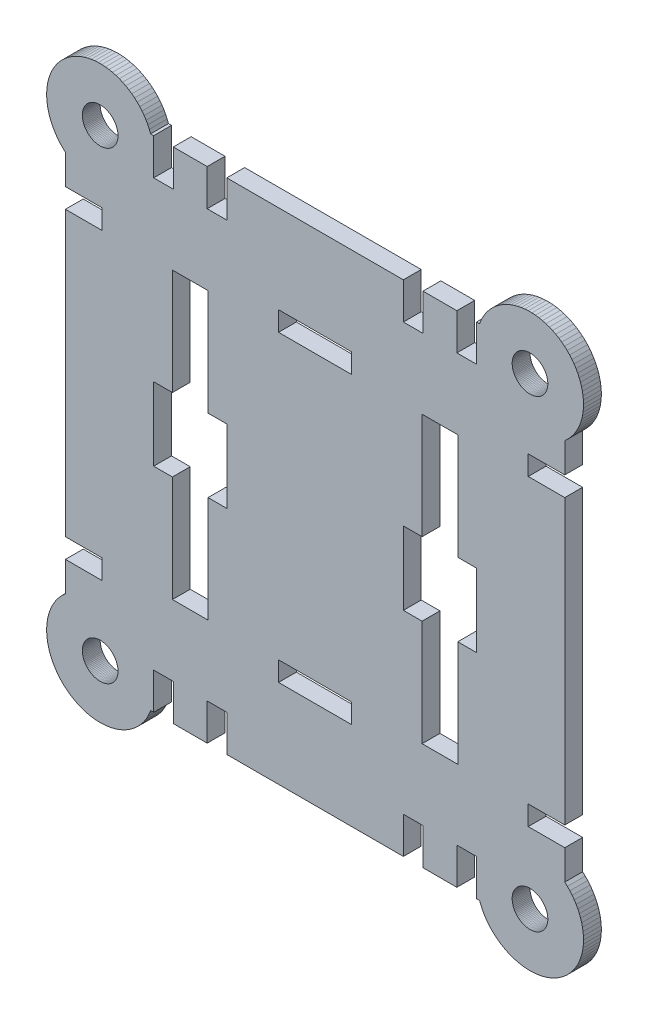
SolidWorks part; units mm, degrees
ref_plane "Front Plane" through (0, 0, 0) normal (0, 0, 1) x (1, 0, 0)
ref_plane "Top Plane" through (0, 0, 0) normal (0, 1, 0) x (1, 0, 0)
ref_plane "Right Plane" through (0, 0, 0) normal (1, 0, 0) x (0, 0, -1)
sketch "Model" plane through (0, 0, 0) normal (0, 0, 1) x (1, 0, 0)
  line L0 (-1586.2043, -182.047) -> (-1586.2043, -187.547)
  line L1 (-1586.2043, -102.547) -> (-1586.2043, -97.047)
  line L2 (-1606.7043, -102.547) -> (-1586.2043, -102.547)
  line L3 (-1566.4543, -182.297) -> (-1556.4543, -182.297)
  line L4 (-1566.2043, -212.297) -> (-1556.7043, -212.297)
  line L5 (-1658.2273, -62.3746) -> (-1657.2303, -62.3063)
  line L6 (-1636.4543, -132.047) -> (-1636.4543, -102.297)
  line L7 (-1648.6775, -64.6251) -> (-1647.8516, -65.1876)
  line L8 (-1606.7043, -187.547) -> (-1606.7043, -182.047)
  line L9 (-1643.3515, -70.4622) -> (-1642.926, -71.3664)
  line L10 (-1642.926, -71.3664) -> (-1642.5617, -72.297)
  line L11 (-1649.5391, -64.1187) -> (-1648.6775, -64.6251)
  line L12 (-1566.4543, -152.547) -> (-1571.7043, -152.547)
  line L13 (-1606.7043, -97.047) -> (-1606.7043, -102.547)
  line L14 (-1663.0238, -63.6934) -> (-1662.104, -63.3028)
  line L15 (-1652.2987, -62.9584) -> (-1651.3537, -63.2836)
  line L16 (-1645.6232, -67.1866) -> (-1644.9746, -67.9469)
  line L17 (-1643.8362, -69.5883) -> (-1643.3515, -70.4622)
  line L18 (-1636.2043, -212.297) -> (-1636.2043, -202.047)
  line L19 (-1659.2175, -62.5091) -> (-1658.2273, -62.3746)
  line L20 (-1539.5016, -73.5378) -> (-1539.2487, -73.3303)
  line L21 (-1566.4543, -102.297) -> (-1556.4543, -102.297)
  line L22 (-1539.9641, -74.0003) -> (-1539.7404, -73.7615)
  line L23 (-1667.8205, -67.2263) -> (-1667.1253, -66.5084)
  line L24 (-1665.5993, -65.2193) -> (-1664.7754, -64.6538)
  line L25 (-1540.3622, -74.5192) -> (-1540.1716, -74.2532)
  line L26 (-1566.2043, -212.297) -> (-1566.2043, -202.047)
  line L27 (-1621.2043, -212.297) -> (-1571.7043, -212.297)
  line L28 (-1636.2043, -212.297) -> (-1626.7043, -212.297)
  line L29 (-1536.8575, -72.3398) -> (-1536.5319, -72.3077)
  line L30 (-1641.7043, -82.547) -> (-1641.7043, -72.297)
  line L31 (-1621.2043, -202.047) -> (-1626.7043, -202.047)
  line L32 (-1653.2632, -62.6969) -> (-1652.2987, -62.9584)
  line L33 (-1663.9156, -64.1444) -> (-1663.0238, -63.6934)
  line L34 (-1654.243, -62.5002) -> (-1653.2632, -62.6969)
  line L35 (-1586.2043, -187.547) -> (-1606.7043, -187.547)
  line L36 (-1666.3838, -65.8384) -> (-1665.5993, -65.2193)
  line L37 (-1551.2043, -72.297) -> (-1550.347, -72.297)
  line L38 (-1551.2043, -212.297) -> (-1551.2043, -202.047)
  line L39 (-1551.2043, -212.297) -> (-1550.347, -212.297)
  line L40 (-1556.7043, -202.047) -> (-1556.7043, -212.297)
  line L41 (-1662.104, -63.3028) -> (-1661.1602, -62.9743)
  line L42 (-1626.7043, -202.047) -> (-1626.7043, -212.297)
  line L43 (-1642.5617, -212.297) -> (-1641.7043, -212.297)
  line L44 (-1644.378, -68.7486) -> (-1643.8362, -69.5883)
  line L45 (-1660.1966, -62.7093) -> (-1659.2175, -62.5091)
  line L46 (-1646.321, -66.4712) -> (-1645.6232, -67.1866)
  line L47 (-1586.2043, -97.047) -> (-1606.7043, -97.047)
  line L48 (-1551.2043, -152.547) -> (-1556.4543, -152.547)
  line L49 (-1667.1253, -66.5084) -> (-1666.3838, -65.8384)
  line L50 (-1650.4325, -63.6709) -> (-1649.5391, -64.1187)
  line L51 (-1538.4163, -72.8127) -> (-1538.1183, -72.6776)
  line L52 (-1571.7043, -202.047) -> (-1571.7043, -212.297)
  line L53 (-1647.0649, -65.8039) -> (-1646.321, -66.4712)
  line L54 (-1657.2303, -62.3063) -> (-1656.2309, -62.3045)
  line L55 (-1537.8121, -72.5624) -> (-1537.499, -72.4674)
  line L56 (-1531.8747, -79.797) -> (-1532.0475, -80.0749)
  line L57 (-1540.535, -74.797) -> (-1540.3622, -74.5192)
  line L58 (-1656.2043, -187.547) -> (-1656.2043, -182.047)
  line L59 (-1636.2043, -72.297) -> (-1636.2043, -82.547)
  line L60 (-1644.9746, -67.9469) -> (-1644.378, -68.7486)
  line L61 (-1566.4543, -152.547) -> (-1566.4543, -182.297)
  line L62 (-1551.2043, -202.047) -> (-1556.7043, -202.047)
  line L63 (-1636.4543, -102.297) -> (-1626.4543, -102.297)
  line L64 (-1651.3537, -63.2836) -> (-1650.4325, -63.6709)
  line L65 (-1656.2043, -182.047) -> (-1666.4543, -182.047)
  line L66 (-1526.4543, -88.6956) -> (-1526.4543, -97.047)
  line L67 (-1666.4543, -97.047) -> (-1656.2043, -97.047)
  line L68 (-1537.1803, -72.3931) -> (-1536.8575, -72.3398)
  line L69 (-1536.7043, -97.047) -> (-1536.7043, -102.547)
  line L70 (-1566.2043, -202.047) -> (-1571.7043, -202.047)
  line L71 (-1531.2476, -76.6444) -> (-1531.2156, -76.97)
  line L72 (-1666.4543, -187.547) -> (-1666.4543, -195.8984)
  line L73 (-1606.7043, -182.047) -> (-1586.2043, -182.047)
  line L74 (-1636.2043, -72.297) -> (-1626.7043, -72.297)
  line L75 (-1621.2043, -72.297) -> (-1621.2043, -82.547)
  line L76 (-1535.2294, -72.3931) -> (-1534.9108, -72.4674)
  line L77 (-1566.2043, -72.297) -> (-1556.7043, -72.297)
  line L78 (-1556.4543, -102.297) -> (-1556.4543, -132.047)
  line L79 (-1666.4543, -187.547) -> (-1656.2043, -187.547)
  line L80 (-1551.2043, -82.547) -> (-1556.7043, -82.547)
  line L81 (-1541.1942, -76.97) -> (-1541.1621, -76.6444)
  line L82 (-1664.7754, -64.6538) -> (-1663.9156, -64.1444)
  line L83 (-1524.4423, -67.9888) -> (-1523.8486, -68.7927)
  line L84 (-1626.4543, -102.297) -> (-1626.4543, -132.047)
  line L85 (-1641.7043, -202.047) -> (-1641.7043, -212.297)
  line L86 (-1536.5319, -82.2863) -> (-1536.8575, -82.2542)
  line L87 (-1532.0475, -80.0749) -> (-1532.2381, -80.3408)
  line L88 (-1531.7205, -75.0856) -> (-1531.5855, -75.3836)
  line L89 (-1540.6892, -75.0856) -> (-1540.535, -74.797)
  line L90 (-1666.4543, -97.047) -> (-1666.4543, -88.6956)
  line L91 (-1551.2043, -72.297) -> (-1551.2043, -82.547)
  line L92 (-1539.5016, -81.0562) -> (-1539.7404, -80.8326)
  line L93 (-1636.2043, -202.047) -> (-1641.7043, -202.047)
  line L94 (-1538.7049, -81.6271) -> (-1538.9827, -81.4544)
  line L95 (-1537.499, -82.1266) -> (-1537.8121, -82.0317)
  line L96 (-1661.1602, -62.9743) -> (-1660.1966, -62.7093)
  line L97 (-1526.4543, -195.8984) -> (-1526.4543, -187.547)
  line L98 (-1526.4543, -187.547) -> (-1536.7043, -187.547)
  line L99 (-1621.2043, -212.297) -> (-1621.2043, -202.047)
  line L100 (-1536.7043, -187.547) -> (-1536.7043, -182.047)
  line L101 (-1647.8516, -65.1876) -> (-1647.0649, -65.8039)
  line L102 (-1536.7043, -182.047) -> (-1526.4543, -182.047)
  line L103 (-1532.6693, -73.7615) -> (-1532.4457, -74.0003)
  line L104 (-1566.4543, -132.047) -> (-1571.7043, -132.047)
  line L105 (-1655.2337, -62.3692) -> (-1654.243, -62.5002)
  line L106 (-1532.4457, -80.5937) -> (-1532.6693, -80.8326)
  line L107 (-1541.1088, -76.3216) -> (-1541.0345, -76.0029)
  line L108 (-1656.2309, -62.3045) -> (-1655.2337, -62.3692)
  line L109 (-1523.7963, -85.7248) -> (-1524.385, -86.5324)
  line L110 (-1537.499, -72.4674) -> (-1537.1803, -72.3931)
  line L111 (-1551.2043, -132.047) -> (-1556.4543, -132.047)
  line L112 (-1656.2043, -102.547) -> (-1666.4543, -102.547)
  line L113 (-1536.2049, -72.297) -> (-1535.8779, -72.3077)
  line L114 (-1538.1183, -72.6776) -> (-1537.8121, -72.5624)
  line L115 (-1540.9395, -78.9042) -> (-1541.0345, -78.5911)
  line L116 (-1533.9934, -81.7814) -> (-1534.2915, -81.9164)
  line L117 (-1534.9108, -72.4674) -> (-1534.5977, -72.5624)
  line L118 (-1544.2312, -64.6251) -> (-1543.3696, -64.1187)
  line L119 (-1540.8243, -75.3836) -> (-1540.6892, -75.0856)
  line L120 (-1531.2156, -77.624) -> (-1531.2476, -77.9496)
  line L121 (-1642.5617, -72.297) -> (-1641.7043, -72.297)
  line L122 (-1621.2043, -82.547) -> (-1626.7043, -82.547)
  line L123 (-1539.2487, -73.3303) -> (-1538.9827, -73.1397)
  line L124 (-1540.3622, -80.0749) -> (-1540.535, -79.797)
  line L125 (-1566.2043, -82.547) -> (-1571.7043, -82.547)
  line L126 (-1531.5855, -79.2104) -> (-1531.7205, -79.5085)
  line L127 (-1538.1183, -81.9164) -> (-1538.4163, -81.7814)
  line L128 (-1536.5319, -72.3077) -> (-1536.2049, -72.297)
  line L129 (-1656.2043, -97.047) -> (-1656.2043, -102.547)
  line L130 (-1566.2043, -72.297) -> (-1566.2043, -82.547)
  line L131 (-1571.7043, -132.047) -> (-1571.7043, -152.547)
  line L132 (-1532.9081, -81.0562) -> (-1533.1611, -81.2638)
  line L133 (-1556.7043, -82.547) -> (-1556.7043, -72.297)
  line L134 (-1531.3752, -78.5911) -> (-1531.4702, -78.9042)
  line L135 (-1541.2049, -77.297) -> (-1541.1942, -76.97)
  line L136 (-1621.2043, -132.047) -> (-1626.4543, -132.047)
  line L137 (-1531.4702, -78.9042) -> (-1531.5855, -79.2104)
  line L138 (-1540.1716, -80.3408) -> (-1540.3622, -80.0749)
  line L139 (-1626.7043, -82.547) -> (-1626.7043, -72.297)
  line L140 (-1535.8779, -72.3077) -> (-1535.5522, -72.3398)
  line L141 (-1539.7404, -73.7615) -> (-1539.5016, -73.5378)
  line L142 (-1538.4163, -81.7814) -> (-1538.7049, -81.6271)
  line L143 (-1532.0475, -74.5192) -> (-1531.8747, -74.797)
  line L144 (-1531.8747, -74.797) -> (-1531.7205, -75.0856)
  line L145 (-1538.9827, -73.1397) -> (-1538.7049, -72.9669)
  line L146 (-1541.0345, -76.0029) -> (-1540.9395, -75.6898)
  line L147 (-1535.5522, -72.3398) -> (-1535.2294, -72.3931)
  line L148 (-1531.3009, -76.3216) -> (-1531.2476, -76.6444)
  line L149 (-1534.5977, -72.5624) -> (-1534.2915, -72.6776)
  line L150 (-1530.8047, -63.3028) -> (-1529.8849, -63.6934)
  line L151 (-1636.4543, -132.047) -> (-1641.7043, -132.047)
  line L152 (-1536.7043, -102.547) -> (-1526.4543, -102.547)
  line L153 (-1621.2043, -72.297) -> (-1571.7043, -72.297)
  line L154 (-1540.8243, -79.2104) -> (-1540.9395, -78.9042)
  line L155 (-1532.4457, -74.0003) -> (-1532.2381, -74.2532)
  line L156 (-1533.1611, -81.2638) -> (-1533.427, -81.4544)
  line L157 (-1534.2915, -81.9164) -> (-1534.5977, -82.0317)
  line L158 (-1540.9395, -75.6898) -> (-1540.8243, -75.3836)
  line L159 (-1540.1716, -74.2532) -> (-1539.9641, -74.0003)
  line L160 (-1522.3699, -83.093) -> (-1522.7865, -84.0013)
  line L161 (-1531.2476, -77.9496) -> (-1531.3009, -78.2725)
  line L162 (-1535.8779, -82.2863) -> (-1536.2049, -82.297)
  line L163 (-1526.4543, -97.047) -> (-1536.7043, -97.047)
  line L164 (-1636.2043, -82.547) -> (-1641.7043, -82.547)
  line L165 (-1535.5522, -82.2542) -> (-1535.8779, -82.2863)
  line L166 (-1536.2049, -82.297) -> (-1536.5319, -82.2863)
  line L167 (-1566.4543, -132.047) -> (-1566.4543, -102.297)
  line L168 (-1541.0345, -78.5911) -> (-1541.1088, -78.2725)
  line L169 (-1571.7043, -82.547) -> (-1571.7043, -72.297)
  line L170 (-1533.7049, -81.6271) -> (-1533.9934, -81.7814)
  line L171 (-1533.427, -81.4544) -> (-1533.7049, -81.6271)
  line L172 (-1531.3009, -78.2725) -> (-1531.3752, -78.5911)
  line L173 (-1547.2855, -67.1866) -> (-1546.5877, -66.4712)
  line L174 (-1541.1621, -76.6444) -> (-1541.1088, -76.3216)
  line L175 (-1540.6892, -79.5085) -> (-1540.8243, -79.2104)
  line L176 (-1538.7049, -72.9669) -> (-1538.4163, -72.8127)
  line L177 (-1535.6784, -62.3063) -> (-1534.6814, -62.3746)
  line L178 (-1531.2156, -76.97) -> (-1531.2049, -77.297)
  line L179 (-1545.0571, -65.1876) -> (-1544.2312, -64.6251)
  line L180 (-1539.2487, -81.2638) -> (-1539.5016, -81.0562)
  line L181 (-1537.675, -62.3692) -> (-1536.6777, -62.3045)
  line L182 (-1533.1611, -73.3303) -> (-1532.9081, -73.5378)
  line L183 (-1652.0844, -75.3836) -> (-1651.9692, -75.6898)
  line L184 (-1531.2049, -77.297) -> (-1531.2156, -77.624)
  line L185 (-1539.6455, -62.6969) -> (-1538.6657, -62.5002)
  line L186 (-1542.4762, -63.6709) -> (-1541.555, -63.2836)
  line L187 (-1521.5129, -74.273) -> (-1521.3441, -75.258)
  line L188 (-1523.3098, -69.6343) -> (-1522.8282, -70.51)
  line L189 (-1651.7145, -76.97) -> (-1651.7038, -77.297)
  line L190 (-1653.4071, -81.0562) -> (-1653.66, -81.2638)
  line L191 (-1533.427, -73.1397) -> (-1533.1611, -73.3303)
  line L192 (-1531.4702, -75.6898) -> (-1531.3752, -76.0029)
  line L193 (-1549.9827, -71.3664) -> (-1549.5572, -70.4622)
  line L194 (-1533.9934, -72.8127) -> (-1533.7049, -72.9669)
  line L195 (-1661.6077, -76.3216) -> (-1661.5334, -76.0029)
  line L196 (-1533.7049, -72.9669) -> (-1533.427, -73.1397)
  line L197 (-1535.2294, -82.2009) -> (-1535.5522, -82.2542)
  line L198 (-1539.7404, -80.8326) -> (-1539.9641, -80.5937)
  line L199 (-1529.8849, -63.6934) -> (-1528.9931, -64.1444)
  line L200 (-1523.8486, -68.7927) -> (-1523.3098, -69.6343)
  line L201 (-1537.1803, -82.2009) -> (-1537.499, -82.1266)
  line L202 (-1524.385, -86.5324) -> (-1525.0262, -87.2989)
  line L203 (-1522.0147, -82.1589) -> (-1522.3699, -83.093)
  line L204 (-1522.4059, -71.4157) -> (-1522.045, -72.3476)
  line L205 (-1652.3737, -74.797) -> (-1652.2195, -75.0856)
  line L206 (-1546.5877, -66.4712) -> (-1545.8438, -65.8039)
  line L207 (-1538.6657, -62.5002) -> (-1537.675, -62.3692)
  line L208 (-1654.4924, -72.8127) -> (-1654.2038, -72.9669)
  line L209 (-1660.463, -74.0003) -> (-1660.2394, -73.7615)
  line L210 (-1532.2381, -74.2532) -> (-1532.0475, -74.5192)
  line L211 (-1532.2381, -80.3408) -> (-1532.4457, -80.5937)
  line L212 (-1540.535, -79.797) -> (-1540.6892, -79.5085)
  line L213 (-1522.7865, -84.0013) -> (-1523.2627, -84.8799)
  line L214 (-1534.5977, -82.0317) -> (-1534.9108, -82.1266)
  line L215 (-1528.1333, -64.6538) -> (-1527.3094, -65.2193)
  line L216 (-1656.7038, -82.297) -> (-1657.0308, -82.2863)
  line L217 (-1531.7205, -79.5085) -> (-1531.8747, -79.797)
  line L218 (-1521.7468, -73.3014) -> (-1521.5129, -74.273)
  line L219 (-1534.2915, -72.6776) -> (-1533.9934, -72.8127)
  line L220 (-1536.8575, -82.2542) -> (-1537.1803, -82.2009)
  line L221 (-1521.3318, -79.2442) -> (-1521.4945, -80.2302)
  line L222 (-1534.9108, -82.1266) -> (-1535.2294, -82.2009)
  line L223 (-1549.5572, -70.4622) -> (-1549.0725, -69.5883)
  line L224 (-1537.8121, -82.0317) -> (-1538.1183, -81.9164)
  line L225 (-1538.9827, -81.4544) -> (-1539.2487, -81.2638)
  line L226 (-1523.2627, -84.8799) -> (-1523.7963, -85.7248)
  line L227 (-1541.1942, -77.624) -> (-1541.2049, -77.297)
  line L228 (-1531.5855, -75.3836) -> (-1531.4702, -75.6898)
  line L229 (-1521.7224, -81.2032) -> (-1522.0147, -82.1589)
  line L230 (-1532.6693, -80.8326) -> (-1532.9081, -81.0562)
  line L231 (-1549.0725, -69.5883) -> (-1548.5306, -68.7486)
  line L232 (-1532.9081, -73.5378) -> (-1532.6693, -73.7615)
  line L233 (-1539.9641, -80.5937) -> (-1540.1716, -80.3408)
  line L234 (-1541.1621, -77.9496) -> (-1541.1942, -77.624)
  line L235 (-1531.3752, -76.0029) -> (-1531.3009, -76.3216)
  line L236 (-1548.5306, -68.7486) -> (-1547.9341, -67.9469)
  line L237 (-1540.61, -62.9584) -> (-1539.6455, -62.6969)
  line L238 (-1661.4385, -75.6898) -> (-1661.3232, -75.3836)
  line L239 (-1657.6793, -72.3931) -> (-1657.3565, -72.3398)
  line L240 (-1550.347, -72.297) -> (-1549.9827, -71.3664)
  line L241 (-1658.311, -82.0317) -> (-1658.6172, -81.9164)
  line L242 (-1651.9692, -75.6898) -> (-1651.8742, -76.0029)
  line L243 (-1547.9341, -67.9469) -> (-1547.2855, -67.1866)
  line L244 (-1527.3094, -65.2193) -> (-1526.5249, -65.8384)
  line L245 (-1654.7904, -81.9164) -> (-1655.0966, -82.0317)
  line L246 (-1659.7476, -73.3303) -> (-1659.4817, -73.1397)
  line L247 (-1521.2049, -77.2507) -> (-1521.2351, -78.2496)
  line L248 (-1522.8282, -70.51) -> (-1522.4059, -71.4157)
  line L249 (-1651.7466, -76.6444) -> (-1651.7145, -76.97)
  line L250 (-1525.7834, -66.5084) -> (-1525.0882, -67.2263)
  line L251 (-1658.9153, -72.8127) -> (-1658.6172, -72.6776)
  line L252 (-1651.8742, -76.0029) -> (-1651.7999, -76.3216)
  line L253 (-1657.6793, -82.2009) -> (-1657.9979, -82.1266)
  line L254 (-1656.7038, -72.297) -> (-1656.3768, -72.3077)
  line L255 (-1660.0005, -73.5378) -> (-1659.7476, -73.3303)
  line L256 (-1653.66, -81.2638) -> (-1653.926, -81.4544)
  line L257 (-1525.717, -88.021) -> (-1526.4543, -88.6956)
  line L258 (-1657.9979, -72.4674) -> (-1657.6793, -72.3931)
  line L259 (-1651.7999, -78.2725) -> (-1651.8742, -78.5911)
  line L260 (-1532.7121, -62.7093) -> (-1531.7485, -62.9743)
  line L261 (-1526.5249, -65.8384) -> (-1525.7834, -66.5084)
  line L262 (-1653.66, -73.3303) -> (-1653.4071, -73.5378)
  line L263 (-1651.7145, -77.624) -> (-1651.7466, -77.9496)
  line L264 (-1669.0601, -68.7927) -> (-1668.4664, -67.9888)
  line L265 (-1670.0805, -70.51) -> (-1669.5989, -69.6343)
  line L266 (-1651.7038, -77.297) -> (-1651.7145, -77.624)
  line L267 (-1531.7485, -62.9743) -> (-1530.8047, -63.3028)
  line L268 (-1651.8742, -78.5911) -> (-1651.9692, -78.9042)
  line L269 (-1654.4924, -81.7814) -> (-1654.7904, -81.9164)
  line L270 (-1533.6912, -62.5091) -> (-1532.7121, -62.7093)
  line L271 (-1670.1222, -84.0013) -> (-1670.5388, -83.093)
  line L272 (-1670.8637, -72.3476) -> (-1670.5028, -71.4157)
  line L273 (-1661.6931, -76.97) -> (-1661.661, -76.6444)
  line L274 (-1661.661, -76.6444) -> (-1661.6077, -76.3216)
  line L275 (-1661.7038, -77.297) -> (-1661.6931, -76.97)
  line L276 (-1657.3565, -72.3398) -> (-1657.0308, -72.3077)
  line L277 (-1545.8438, -65.8039) -> (-1545.0571, -65.1876)
  line L278 (-1652.3737, -79.797) -> (-1652.5465, -80.0749)
  line L279 (-1651.9692, -78.9042) -> (-1652.0844, -79.2104)
  line L280 (-1541.555, -63.2836) -> (-1540.61, -62.9584)
  line L281 (-1657.0308, -72.3077) -> (-1656.7038, -72.297)
  line L282 (-1541.1088, -78.2725) -> (-1541.1621, -77.9496)
  line L283 (-1661.5334, -78.5911) -> (-1661.6077, -78.2725)
  line L284 (-1528.9931, -64.1444) -> (-1528.1333, -64.6538)
  line L285 (-1660.6706, -74.2532) -> (-1660.463, -74.0003)
  line L286 (-1525.0262, -87.2989) -> (-1525.717, -88.021)
  line L287 (-1653.1683, -80.8326) -> (-1653.4071, -81.0562)
  line L288 (-1661.5334, -76.0029) -> (-1661.4385, -75.6898)
  line L289 (-1521.2351, -78.2496) -> (-1521.3318, -79.2442)
  line L290 (-1521.4945, -80.2302) -> (-1521.7224, -81.2032)
  line L291 (-1521.3441, -75.258) -> (-1521.2413, -76.252)
  line L292 (-1652.0844, -79.2104) -> (-1652.2195, -79.5085)
  line L293 (-1668.4664, -67.9888) -> (-1667.8205, -67.2263)
  line L294 (-1656.3768, -72.3077) -> (-1656.0512, -72.3398)
  line L295 (-1525.0882, -67.2263) -> (-1524.4423, -67.9888)
  line L296 (-1661.0339, -74.797) -> (-1660.8612, -74.5192)
  line L297 (-1522.045, -72.3476) -> (-1521.7468, -73.3014)
  line L298 (-1671.5646, -75.258) -> (-1671.3958, -74.273)
  line L299 (-1543.3696, -64.1187) -> (-1542.4762, -63.6709)
  line L300 (-1536.6777, -62.3045) -> (-1535.6784, -62.3063)
  line L301 (-1652.2195, -79.5085) -> (-1652.3737, -79.797)
  line L302 (-1651.7999, -76.3216) -> (-1651.7466, -76.6444)
  line L303 (-1656.0512, -72.3398) -> (-1655.7284, -72.3931)
  line L304 (-1521.2413, -76.252) -> (-1521.2049, -77.2507)
  line L305 (-1534.6814, -62.3746) -> (-1533.6912, -62.5091)
  line L306 (-1671.5769, -79.2442) -> (-1671.6735, -78.2496)
  line L307 (-1656.0512, -82.2542) -> (-1656.3768, -82.2863)
  line L308 (-1659.4817, -73.1397) -> (-1659.2038, -72.9669)
  line L309 (-1657.9979, -82.1266) -> (-1658.311, -82.0317)
  line L310 (-1655.0966, -82.0317) -> (-1655.4097, -82.1266)
  line L311 (-1654.7904, -72.6776) -> (-1654.4924, -72.8127)
  line L312 (-1661.6931, -77.624) -> (-1661.7038, -77.297)
  line L313 (-1665.5993, -219.3747) -> (-1666.3838, -218.7556)
  line L314 (-1652.5465, -74.5192) -> (-1652.3737, -74.797)
  line L315 (-1659.2038, -81.6271) -> (-1659.4817, -81.4544)
  line L316 (-1660.8612, -74.5192) -> (-1660.6706, -74.2532)
  line L317 (-1523.3098, -214.9597) -> (-1523.8486, -215.8013)
  line L318 (-1661.0339, -79.797) -> (-1661.1882, -79.5085)
  line L319 (-1661.6077, -78.2725) -> (-1661.661, -77.9496)
  line L320 (-1668.5236, -86.5324) -> (-1669.1124, -85.7248)
  line L321 (-1658.311, -72.5624) -> (-1657.9979, -72.4674)
  line L322 (-1651.7466, -77.9496) -> (-1651.7999, -78.2725)
  line L323 (-1652.5465, -80.0749) -> (-1652.7371, -80.3408)
  line L324 (-1655.4097, -72.4674) -> (-1655.0966, -72.5624)
  line L325 (-1661.4385, -78.9042) -> (-1661.5334, -78.5911)
  line L326 (-1661.1882, -75.0856) -> (-1661.0339, -74.797)
  line L327 (-1653.926, -81.4544) -> (-1654.2038, -81.6271)
  line L328 (-1548.5306, -215.8454) -> (-1549.0725, -215.0057)
  line L329 (-1546.5877, -218.1228) -> (-1547.2855, -217.4074)
  line L330 (-1652.9446, -74.0003) -> (-1652.7371, -74.2532)
  line L331 (-1658.6172, -72.6776) -> (-1658.311, -72.5624)
  line L332 (-1657.0308, -82.2863) -> (-1657.3565, -82.2542)
  line L333 (-1660.6706, -80.3408) -> (-1660.8612, -80.0749)
  line L334 (-1652.7371, -74.2532) -> (-1652.5465, -74.5192)
  line L335 (-1545.8438, -218.7901) -> (-1546.5877, -218.1228)
  line L336 (-1545.0571, -219.4064) -> (-1545.8438, -218.7901)
  line L337 (-1660.463, -80.5937) -> (-1660.6706, -80.3408)
  line L338 (-1547.2855, -217.4074) -> (-1547.9341, -216.6472)
  line L339 (-1544.2312, -219.969) -> (-1545.0571, -219.4064)
  line L340 (-1658.6172, -81.9164) -> (-1658.9153, -81.7814)
  line L341 (-1549.9827, -213.2276) -> (-1550.347, -212.297)
  line L342 (-1543.3696, -220.4753) -> (-1544.2312, -219.969)
  line L343 (-1659.2038, -72.9669) -> (-1658.9153, -72.8127)
  line L344 (-1659.4817, -81.4544) -> (-1659.7476, -81.2638)
  line L345 (-1549.0725, -215.0057) -> (-1549.5572, -214.1318)
  line L346 (-1542.4762, -220.9231) -> (-1543.3696, -220.4753)
  line L347 (-1653.926, -73.1397) -> (-1653.66, -73.3303)
  line L348 (-1661.3232, -75.3836) -> (-1661.1882, -75.0856)
  line L349 (-1671.6674, -76.252) -> (-1671.5646, -75.258)
  line L350 (-1660.2394, -73.7615) -> (-1660.0005, -73.5378)
  line L351 (-1660.2394, -80.8326) -> (-1660.463, -80.5937)
  line L352 (-1654.2038, -81.6271) -> (-1654.4924, -81.7814)
  line L353 (-1533.6912, -222.0849) -> (-1534.6814, -222.2194)
  line L354 (-1549.5572, -214.1318) -> (-1549.9827, -213.2276)
  line L355 (-1547.9341, -216.6472) -> (-1548.5306, -215.8454)
  line L356 (-1541.555, -221.3104) -> (-1542.4762, -220.9231)
  line L357 (-1540.61, -221.6356) -> (-1541.555, -221.3104)
  line L358 (-1539.6455, -221.8971) -> (-1540.61, -221.6356)
  line L359 (-1538.6657, -222.0938) -> (-1539.6455, -221.8971)
  line L360 (-1537.675, -222.2248) -> (-1538.6657, -222.0938)
  line L361 (-1536.6777, -222.2895) -> (-1537.675, -222.2248)
  line L362 (-1535.6784, -222.2878) -> (-1536.6777, -222.2895)
  line L363 (-1534.6814, -222.2194) -> (-1535.6784, -222.2878)
  line L364 (-1532.7121, -221.8847) -> (-1533.6912, -222.0849)
  line L365 (-1531.7485, -221.6197) -> (-1532.7121, -221.8847)
  line L366 (-1530.8047, -221.2912) -> (-1531.7485, -221.6197)
  line L367 (-1529.8849, -220.9006) -> (-1530.8047, -221.2912)
  line L368 (-1528.9931, -220.4496) -> (-1529.8849, -220.9006)
  line L369 (-1528.1333, -219.9402) -> (-1528.9931, -220.4496)
  line L370 (-1527.3094, -219.3747) -> (-1528.1333, -219.9402)
  line L371 (-1526.5249, -218.7556) -> (-1527.3094, -219.3747)
  line L372 (-1525.7834, -218.0856) -> (-1526.5249, -218.7556)
  line L373 (-1525.0882, -217.3677) -> (-1525.7834, -218.0856)
  line L374 (-1524.4423, -216.6052) -> (-1525.0882, -217.3677)
  line L375 (-1523.8486, -215.8013) -> (-1524.4423, -216.6052)
  line L376 (-1522.8282, -214.084) -> (-1523.3098, -214.9597)
  line L377 (-1522.4059, -213.1783) -> (-1522.8282, -214.084)
  line L378 (-1522.045, -212.2464) -> (-1522.4059, -213.1783)
  line L379 (-1521.7468, -211.2926) -> (-1522.045, -212.2464)
  line L380 (-1521.5129, -210.321) -> (-1521.7468, -211.2926)
  line L381 (-1521.3441, -209.336) -> (-1521.5129, -210.321)
  line L382 (-1521.2413, -208.342) -> (-1521.3441, -209.336)
  line L383 (-1521.2049, -207.3433) -> (-1521.2413, -208.342)
  line L384 (-1521.2351, -206.3444) -> (-1521.2049, -207.3433)
  line L385 (-1521.3318, -205.3498) -> (-1521.2351, -206.3444)
  line L386 (-1521.4945, -204.3638) -> (-1521.3318, -205.3498)
  line L387 (-1521.7224, -203.3908) -> (-1521.4945, -204.3638)
  line L388 (-1522.0147, -202.4351) -> (-1521.7224, -203.3908)
  line L389 (-1522.3699, -201.501) -> (-1522.0147, -202.4351)
  line L390 (-1522.7865, -200.5927) -> (-1522.3699, -201.501)
  line L391 (-1523.2627, -199.7141) -> (-1522.7865, -200.5927)
  line L392 (-1523.7963, -198.8692) -> (-1523.2627, -199.7141)
  line L393 (-1524.385, -198.0616) -> (-1523.7963, -198.8692)
  line L394 (-1525.0262, -197.2951) -> (-1524.385, -198.0616)
  line L395 (-1525.717, -196.573) -> (-1525.0262, -197.2951)
  line L396 (-1526.4543, -195.8984) -> (-1525.717, -196.573)
  line L397 (-1526.4543, -182.047) -> (-1526.4543, -102.547)
  line L398 (-1669.5989, -69.6343) -> (-1669.0601, -68.7927)
  line L399 (-1670.5028, -71.4157) -> (-1670.0805, -70.51)
  line L400 (-1671.1619, -73.3014) -> (-1670.8637, -72.3476)
  line L401 (-1671.3958, -74.273) -> (-1671.1619, -73.3014)
  line L402 (-1671.7037, -77.2507) -> (-1671.6674, -76.252)
  line L403 (-1671.6735, -78.2496) -> (-1671.7037, -77.2507)
  line L404 (-1671.4142, -80.2302) -> (-1671.5769, -79.2442)
  line L405 (-1671.1863, -81.2032) -> (-1671.4142, -80.2302)
  line L406 (-1670.894, -82.1589) -> (-1671.1863, -81.2032)
  line L407 (-1670.5388, -83.093) -> (-1670.894, -82.1589)
  line L408 (-1669.646, -84.8799) -> (-1670.1222, -84.0013)
  line L409 (-1669.1124, -85.7248) -> (-1669.646, -84.8799)
  line L410 (-1667.8825, -87.2989) -> (-1668.5236, -86.5324)
  line L411 (-1667.1917, -88.021) -> (-1667.8825, -87.2989)
  line L412 (-1666.4543, -88.6956) -> (-1667.1917, -88.021)
  line L413 (-1666.4543, -102.547) -> (-1666.4543, -182.047)
  line L414 (-1667.1917, -196.573) -> (-1666.4543, -195.8984)
  line L415 (-1667.8825, -197.2951) -> (-1667.1917, -196.573)
  line L416 (-1668.5236, -198.0616) -> (-1667.8825, -197.2951)
  line L417 (-1669.1124, -198.8692) -> (-1668.5236, -198.0616)
  line L418 (-1669.646, -199.7141) -> (-1669.1124, -198.8692)
  line L419 (-1670.1222, -200.5927) -> (-1669.646, -199.7141)
  line L420 (-1670.5388, -201.501) -> (-1670.1222, -200.5927)
  line L421 (-1670.894, -202.4351) -> (-1670.5388, -201.501)
  line L422 (-1671.1863, -203.3908) -> (-1670.894, -202.4351)
  line L423 (-1671.4142, -204.3638) -> (-1671.1863, -203.3908)
  line L424 (-1671.5769, -205.3498) -> (-1671.4142, -204.3638)
  line L425 (-1671.6735, -206.3444) -> (-1671.5769, -205.3498)
  line L426 (-1671.7037, -207.3433) -> (-1671.6735, -206.3444)
  line L427 (-1671.6674, -208.342) -> (-1671.7037, -207.3433)
  line L428 (-1671.5646, -209.336) -> (-1671.6674, -208.342)
  line L429 (-1671.3958, -210.321) -> (-1671.5646, -209.336)
  line L430 (-1671.1619, -211.2926) -> (-1671.3958, -210.321)
  line L431 (-1670.8637, -212.2464) -> (-1671.1619, -211.2926)
  line L432 (-1670.5028, -213.1783) -> (-1670.8637, -212.2464)
  line L433 (-1670.0805, -214.084) -> (-1670.5028, -213.1783)
  line L434 (-1669.5989, -214.9597) -> (-1670.0805, -214.084)
  line L435 (-1669.0601, -215.8013) -> (-1669.5989, -214.9597)
  line L436 (-1668.4664, -216.6052) -> (-1669.0601, -215.8013)
  line L437 (-1667.8205, -217.3677) -> (-1668.4664, -216.6052)
  line L438 (-1667.1253, -218.0856) -> (-1667.8205, -217.3677)
  line L439 (-1666.3838, -218.7556) -> (-1667.1253, -218.0856)
  line L440 (-1664.7754, -219.9402) -> (-1665.5993, -219.3747)
  line L441 (-1663.9156, -220.4496) -> (-1664.7754, -219.9402)
  line L442 (-1663.0238, -220.9006) -> (-1663.9156, -220.4496)
  line L443 (-1662.104, -221.2912) -> (-1663.0238, -220.9006)
  line L444 (-1661.1602, -221.6197) -> (-1662.104, -221.2912)
  line L445 (-1660.1966, -221.8847) -> (-1661.1602, -221.6197)
  line L446 (-1659.2175, -222.0849) -> (-1660.1966, -221.8847)
  line L447 (-1658.2273, -222.2194) -> (-1659.2175, -222.0849)
  line L448 (-1657.2303, -222.2878) -> (-1658.2273, -222.2194)
  line L449 (-1656.2309, -222.2895) -> (-1657.2303, -222.2878)
  line L450 (-1655.2337, -222.2248) -> (-1656.2309, -222.2895)
  line L451 (-1654.243, -222.0938) -> (-1655.2337, -222.2248)
  line L452 (-1653.2632, -221.8971) -> (-1654.243, -222.0938)
  line L453 (-1652.2987, -221.6356) -> (-1653.2632, -221.8971)
  line L454 (-1651.3537, -221.3104) -> (-1652.2987, -221.6356)
  line L455 (-1650.4325, -220.9231) -> (-1651.3537, -221.3104)
  line L456 (-1649.5391, -220.4753) -> (-1650.4325, -220.9231)
  line L457 (-1648.6775, -219.969) -> (-1649.5391, -220.4753)
  line L458 (-1647.8516, -219.4064) -> (-1648.6775, -219.969)
  line L459 (-1647.0649, -218.7901) -> (-1647.8516, -219.4064)
  line L460 (-1646.321, -218.1228) -> (-1647.0649, -218.7901)
  line L461 (-1645.6232, -217.4074) -> (-1646.321, -218.1228)
  line L462 (-1644.9746, -216.6472) -> (-1645.6232, -217.4074)
  line L463 (-1644.378, -215.8454) -> (-1644.9746, -216.6472)
  line L464 (-1643.8362, -215.0057) -> (-1644.378, -215.8454)
  line L465 (-1643.3515, -214.1318) -> (-1643.8362, -215.0057)
  line L466 (-1642.926, -213.2276) -> (-1643.3515, -214.1318)
  line L467 (-1642.5617, -212.297) -> (-1642.926, -213.2276)
  line L468 (-1551.2043, -152.547) -> (-1551.2043, -132.047)
  line L469 (-1556.4543, -182.297) -> (-1556.4543, -152.547)
  line L470 (-1621.2043, -152.547) -> (-1621.2043, -132.047)
  line L471 (-1621.2043, -152.547) -> (-1626.4543, -152.547)
  line L472 (-1626.4543, -182.297) -> (-1626.4543, -152.547)
  line L473 (-1636.4543, -182.297) -> (-1626.4543, -182.297)
  line L474 (-1636.4543, -152.547) -> (-1636.4543, -182.297)
  line L475 (-1636.4543, -152.547) -> (-1641.7043, -152.547)
  line L476 (-1641.7043, -152.547) -> (-1641.7043, -132.047)
  line L477 (-1655.7284, -72.3931) -> (-1655.4097, -72.4674)
  line L478 (-1655.0966, -72.5624) -> (-1654.7904, -72.6776)
  line L479 (-1654.2038, -72.9669) -> (-1653.926, -73.1397)
  line L480 (-1653.4071, -73.5378) -> (-1653.1683, -73.7615)
  line L481 (-1653.1683, -73.7615) -> (-1652.9446, -74.0003)
  line L482 (-1652.2195, -75.0856) -> (-1652.0844, -75.3836)
  line L483 (-1652.7371, -80.3408) -> (-1652.9446, -80.5937)
  line L484 (-1652.9446, -80.5937) -> (-1653.1683, -80.8326)
  line L485 (-1655.4097, -82.1266) -> (-1655.7284, -82.2009)
  line L486 (-1655.7284, -82.2009) -> (-1656.0512, -82.2542)
  line L487 (-1656.3768, -82.2863) -> (-1656.7038, -82.297)
  line L488 (-1657.3565, -82.2542) -> (-1657.6793, -82.2009)
  line L489 (-1658.9153, -81.7814) -> (-1659.2038, -81.6271)
  line L490 (-1659.7476, -81.2638) -> (-1660.0005, -81.0562)
  line L491 (-1660.0005, -81.0562) -> (-1660.2394, -80.8326)
  line L492 (-1660.8612, -80.0749) -> (-1661.0339, -79.797)
  line L493 (-1661.1882, -79.5085) -> (-1661.3232, -79.2104)
  line L494 (-1661.3232, -79.2104) -> (-1661.4385, -78.9042)
  line L495 (-1661.661, -77.9496) -> (-1661.6931, -77.624)
  line L496 (-1538.4163, -202.8126) -> (-1538.1183, -202.6776)
  line L497 (-1538.1183, -202.6776) -> (-1537.8121, -202.5623)
  line L498 (-1537.8121, -202.5623) -> (-1537.499, -202.4674)
  line L499 (-1537.499, -202.4674) -> (-1537.1803, -202.3931)
  line L500 (-1537.1803, -202.3931) -> (-1536.8575, -202.3398)
  line L501 (-1536.8575, -202.3398) -> (-1536.5319, -202.3077)
  line L502 (-1536.5319, -202.3077) -> (-1536.2049, -202.297)
  line L503 (-1536.2049, -202.297) -> (-1535.8779, -202.3077)
  line L504 (-1535.8779, -202.3077) -> (-1535.5522, -202.3398)
  line L505 (-1535.5522, -202.3398) -> (-1535.2294, -202.3931)
  line L506 (-1535.2294, -202.3931) -> (-1534.9108, -202.4674)
  line L507 (-1534.9108, -202.4674) -> (-1534.5977, -202.5623)
  line L508 (-1534.5977, -202.5623) -> (-1534.2915, -202.6776)
  line L509 (-1534.2915, -202.6776) -> (-1533.9934, -202.8126)
  line L510 (-1533.9934, -202.8126) -> (-1533.7049, -202.9669)
  line L511 (-1533.7049, -202.9669) -> (-1533.427, -203.1396)
  line L512 (-1533.427, -203.1396) -> (-1533.1611, -203.3302)
  line L513 (-1533.1611, -203.3302) -> (-1532.9081, -203.5378)
  line L514 (-1532.9081, -203.5378) -> (-1532.6693, -203.7615)
  line L515 (-1532.6693, -203.7615) -> (-1532.4457, -204.0003)
  line L516 (-1532.4457, -204.0003) -> (-1532.2381, -204.2532)
  line L517 (-1532.2381, -204.2532) -> (-1532.0475, -204.5191)
  line L518 (-1532.0475, -204.5191) -> (-1531.8747, -204.797)
  line L519 (-1531.8747, -204.797) -> (-1531.7205, -205.0856)
  line L520 (-1531.7205, -205.0856) -> (-1531.5855, -205.3836)
  line L521 (-1531.5855, -205.3836) -> (-1531.4702, -205.6898)
  line L522 (-1531.4702, -205.6898) -> (-1531.3752, -206.0029)
  line L523 (-1531.3752, -206.0029) -> (-1531.3009, -206.3215)
  line L524 (-1531.3009, -206.3215) -> (-1531.2476, -206.6444)
  line L525 (-1531.2476, -206.6444) -> (-1531.2156, -206.97)
  line L526 (-1531.2156, -206.97) -> (-1531.2049, -207.297)
  line L527 (-1531.2049, -207.297) -> (-1531.2156, -207.624)
  line L528 (-1531.2156, -207.624) -> (-1531.2476, -207.9496)
  line L529 (-1531.2476, -207.9496) -> (-1531.3009, -208.2724)
  line L530 (-1531.3009, -208.2724) -> (-1531.3752, -208.5911)
  line L531 (-1531.3752, -208.5911) -> (-1531.4702, -208.9042)
  line L532 (-1531.4702, -208.9042) -> (-1531.5855, -209.2104)
  line L533 (-1531.5855, -209.2104) -> (-1531.7205, -209.5084)
  line L534 (-1531.7205, -209.5084) -> (-1531.8747, -209.797)
  line L535 (-1531.8747, -209.797) -> (-1532.0475, -210.0748)
  line L536 (-1532.0475, -210.0748) -> (-1532.2381, -210.3408)
  line L537 (-1532.2381, -210.3408) -> (-1532.4457, -210.5937)
  line L538 (-1532.4457, -210.5937) -> (-1532.6693, -210.8325)
  line L539 (-1532.6693, -210.8325) -> (-1532.9081, -211.0562)
  line L540 (-1532.9081, -211.0562) -> (-1533.1611, -211.2638)
  line L541 (-1533.1611, -211.2638) -> (-1533.427, -211.4543)
  line L542 (-1533.427, -211.4543) -> (-1533.7049, -211.6271)
  line L543 (-1533.7049, -211.6271) -> (-1533.9934, -211.7814)
  line L544 (-1533.9934, -211.7814) -> (-1534.2915, -211.9164)
  line L545 (-1534.2915, -211.9164) -> (-1534.5977, -212.0316)
  line L546 (-1534.5977, -212.0316) -> (-1534.9108, -212.1266)
  line L547 (-1534.9108, -212.1266) -> (-1535.2294, -212.2009)
  line L548 (-1535.2294, -212.2009) -> (-1535.5522, -212.2542)
  line L549 (-1535.5522, -212.2542) -> (-1535.8779, -212.2863)
  line L550 (-1535.8779, -212.2863) -> (-1536.2049, -212.297)
  line L551 (-1536.2049, -212.297) -> (-1536.5319, -212.2863)
  line L552 (-1536.5319, -212.2863) -> (-1536.8575, -212.2542)
  line L553 (-1536.8575, -212.2542) -> (-1537.1803, -212.2009)
  line L554 (-1537.1803, -212.2009) -> (-1537.499, -212.1266)
  line L555 (-1537.499, -212.1266) -> (-1537.8121, -212.0316)
  line L556 (-1537.8121, -212.0316) -> (-1538.1183, -211.9164)
  line L557 (-1538.1183, -211.9164) -> (-1538.4163, -211.7814)
  line L558 (-1538.4163, -211.7814) -> (-1538.7049, -211.6271)
  line L559 (-1538.7049, -211.6271) -> (-1538.9827, -211.4543)
  line L560 (-1538.9827, -211.4543) -> (-1539.2487, -211.2638)
  line L561 (-1539.2487, -211.2638) -> (-1539.5016, -211.0562)
  line L562 (-1539.5016, -211.0562) -> (-1539.7404, -210.8325)
  line L563 (-1539.7404, -210.8325) -> (-1539.9641, -210.5937)
  line L564 (-1539.9641, -210.5937) -> (-1540.1716, -210.3408)
  line L565 (-1540.1716, -210.3408) -> (-1540.3622, -210.0748)
  line L566 (-1540.3622, -210.0748) -> (-1540.535, -209.797)
  line L567 (-1540.535, -209.797) -> (-1540.6892, -209.5084)
  line L568 (-1540.6892, -209.5084) -> (-1540.8243, -209.2104)
  line L569 (-1540.8243, -209.2104) -> (-1540.9395, -208.9042)
  line L570 (-1540.9395, -208.9042) -> (-1541.0345, -208.5911)
  line L571 (-1541.0345, -208.5911) -> (-1541.1088, -208.2724)
  line L572 (-1541.1088, -208.2724) -> (-1541.1621, -207.9496)
  line L573 (-1541.1621, -207.9496) -> (-1541.1942, -207.624)
  line L574 (-1541.1942, -207.624) -> (-1541.2049, -207.297)
  line L575 (-1541.2049, -207.297) -> (-1541.1942, -206.97)
  line L576 (-1541.1942, -206.97) -> (-1541.1621, -206.6444)
  line L577 (-1541.1621, -206.6444) -> (-1541.1088, -206.3215)
  line L578 (-1541.1088, -206.3215) -> (-1541.0345, -206.0029)
  line L579 (-1541.0345, -206.0029) -> (-1540.9395, -205.6898)
  line L580 (-1540.9395, -205.6898) -> (-1540.8243, -205.3836)
  line L581 (-1540.8243, -205.3836) -> (-1540.6892, -205.0856)
  line L582 (-1540.6892, -205.0856) -> (-1540.535, -204.797)
  line L583 (-1540.535, -204.797) -> (-1540.3622, -204.5191)
  line L584 (-1540.3622, -204.5191) -> (-1540.1716, -204.2532)
  line L585 (-1540.1716, -204.2532) -> (-1539.9641, -204.0003)
  line L586 (-1539.9641, -204.0003) -> (-1539.7404, -203.7615)
  line L587 (-1539.7404, -203.7615) -> (-1539.5016, -203.5378)
  line L588 (-1539.5016, -203.5378) -> (-1539.2487, -203.3302)
  line L589 (-1539.2487, -203.3302) -> (-1538.9827, -203.1396)
  line L590 (-1538.9827, -203.1396) -> (-1538.7049, -202.9669)
  line L591 (-1538.7049, -202.9669) -> (-1538.4163, -202.8126)
  line L592 (-1661.3232, -205.3836) -> (-1661.1882, -205.0856)
  line L593 (-1661.1882, -205.0856) -> (-1661.0339, -204.797)
  line L594 (-1661.0339, -204.797) -> (-1660.8612, -204.5191)
  line L595 (-1660.8612, -204.5191) -> (-1660.6706, -204.2532)
  line L596 (-1660.6706, -204.2532) -> (-1660.463, -204.0003)
  line L597 (-1660.463, -204.0003) -> (-1660.2394, -203.7615)
  line L598 (-1660.2394, -203.7615) -> (-1660.0005, -203.5378)
  line L599 (-1660.0005, -203.5378) -> (-1659.7476, -203.3302)
  line L600 (-1659.7476, -203.3302) -> (-1659.4817, -203.1396)
  line L601 (-1659.4817, -203.1396) -> (-1659.2038, -202.9669)
  line L602 (-1659.2038, -202.9669) -> (-1658.9153, -202.8126)
  line L603 (-1658.9153, -202.8126) -> (-1658.6172, -202.6776)
  line L604 (-1658.6172, -202.6776) -> (-1658.311, -202.5623)
  line L605 (-1658.311, -202.5623) -> (-1657.9979, -202.4674)
  line L606 (-1657.9979, -202.4674) -> (-1657.6793, -202.3931)
  line L607 (-1657.6793, -202.3931) -> (-1657.3565, -202.3398)
  line L608 (-1657.3565, -202.3398) -> (-1657.0308, -202.3077)
  line L609 (-1657.0308, -202.3077) -> (-1656.7038, -202.297)
  line L610 (-1656.7038, -202.297) -> (-1656.3768, -202.3077)
  line L611 (-1656.3768, -202.3077) -> (-1656.0512, -202.3398)
  line L612 (-1656.0512, -202.3398) -> (-1655.7284, -202.3931)
  line L613 (-1655.7284, -202.3931) -> (-1655.4097, -202.4674)
  line L614 (-1655.4097, -202.4674) -> (-1655.0966, -202.5623)
  line L615 (-1655.0966, -202.5623) -> (-1654.7904, -202.6776)
  line L616 (-1654.7904, -202.6776) -> (-1654.4924, -202.8126)
  line L617 (-1654.4924, -202.8126) -> (-1654.2038, -202.9669)
  line L618 (-1654.2038, -202.9669) -> (-1653.926, -203.1396)
  line L619 (-1653.926, -203.1396) -> (-1653.66, -203.3302)
  line L620 (-1653.66, -203.3302) -> (-1653.4071, -203.5378)
  line L621 (-1653.4071, -203.5378) -> (-1653.1683, -203.7615)
  line L622 (-1653.1683, -203.7615) -> (-1652.9446, -204.0003)
  line L623 (-1652.9446, -204.0003) -> (-1652.7371, -204.2532)
  line L624 (-1652.7371, -204.2532) -> (-1652.5465, -204.5191)
  line L625 (-1652.5465, -204.5191) -> (-1652.3737, -204.797)
  line L626 (-1652.3737, -204.797) -> (-1652.2195, -205.0856)
  line L627 (-1652.2195, -205.0856) -> (-1652.0844, -205.3836)
  line L628 (-1652.0844, -205.3836) -> (-1651.9692, -205.6898)
  line L629 (-1651.9692, -205.6898) -> (-1651.8742, -206.0029)
  line L630 (-1651.8742, -206.0029) -> (-1651.7999, -206.3215)
  line L631 (-1651.7999, -206.3215) -> (-1651.7466, -206.6444)
  line L632 (-1651.7466, -206.6444) -> (-1651.7145, -206.97)
  line L633 (-1651.7145, -206.97) -> (-1651.7038, -207.297)
  line L634 (-1651.7038, -207.297) -> (-1651.7145, -207.624)
  line L635 (-1651.7145, -207.624) -> (-1651.7466, -207.9496)
  line L636 (-1651.7466, -207.9496) -> (-1651.7999, -208.2724)
  line L637 (-1651.7999, -208.2724) -> (-1651.8742, -208.5911)
  line L638 (-1651.8742, -208.5911) -> (-1651.9692, -208.9042)
  line L639 (-1651.9692, -208.9042) -> (-1652.0844, -209.2104)
  line L640 (-1652.0844, -209.2104) -> (-1652.2195, -209.5084)
  line L641 (-1652.2195, -209.5084) -> (-1652.3737, -209.797)
  line L642 (-1652.3737, -209.797) -> (-1652.5465, -210.0748)
  line L643 (-1652.5465, -210.0748) -> (-1652.7371, -210.3408)
  line L644 (-1652.7371, -210.3408) -> (-1652.9446, -210.5937)
  line L645 (-1652.9446, -210.5937) -> (-1653.1683, -210.8325)
  line L646 (-1653.1683, -210.8325) -> (-1653.4071, -211.0562)
  line L647 (-1653.4071, -211.0562) -> (-1653.66, -211.2638)
  line L648 (-1653.66, -211.2638) -> (-1653.926, -211.4543)
  line L649 (-1653.926, -211.4543) -> (-1654.2038, -211.6271)
  line L650 (-1654.2038, -211.6271) -> (-1654.4924, -211.7814)
  line L651 (-1654.4924, -211.7814) -> (-1654.7904, -211.9164)
  line L652 (-1654.7904, -211.9164) -> (-1655.0966, -212.0316)
  line L653 (-1655.0966, -212.0316) -> (-1655.4097, -212.1266)
  line L654 (-1655.4097, -212.1266) -> (-1655.7284, -212.2009)
  line L655 (-1655.7284, -212.2009) -> (-1656.0512, -212.2542)
  line L656 (-1656.0512, -212.2542) -> (-1656.3768, -212.2863)
  line L657 (-1656.3768, -212.2863) -> (-1656.7038, -212.297)
  line L658 (-1656.7038, -212.297) -> (-1657.0308, -212.2863)
  line L659 (-1657.0308, -212.2863) -> (-1657.3565, -212.2542)
  line L660 (-1657.3565, -212.2542) -> (-1657.6793, -212.2009)
  line L661 (-1657.6793, -212.2009) -> (-1657.9979, -212.1266)
  line L662 (-1657.9979, -212.1266) -> (-1658.311, -212.0316)
  line L663 (-1658.311, -212.0316) -> (-1658.6172, -211.9164)
  line L664 (-1658.6172, -211.9164) -> (-1658.9153, -211.7814)
  line L665 (-1658.9153, -211.7814) -> (-1659.2038, -211.6271)
  line L666 (-1659.2038, -211.6271) -> (-1659.4817, -211.4543)
  line L667 (-1659.4817, -211.4543) -> (-1659.7476, -211.2638)
  line L668 (-1659.7476, -211.2638) -> (-1660.0005, -211.0562)
  line L669 (-1660.0005, -211.0562) -> (-1660.2394, -210.8325)
  line L670 (-1660.2394, -210.8325) -> (-1660.463, -210.5937)
  line L671 (-1660.463, -210.5937) -> (-1660.6706, -210.3408)
  line L672 (-1660.6706, -210.3408) -> (-1660.8612, -210.0748)
  line L673 (-1660.8612, -210.0748) -> (-1661.0339, -209.797)
  line L674 (-1661.0339, -209.797) -> (-1661.1882, -209.5084)
  line L675 (-1661.1882, -209.5084) -> (-1661.3232, -209.2104)
  line L676 (-1661.3232, -209.2104) -> (-1661.4385, -208.9042)
  line L677 (-1661.4385, -208.9042) -> (-1661.5334, -208.5911)
  line L678 (-1661.5334, -208.5911) -> (-1661.6077, -208.2724)
  line L679 (-1661.6077, -208.2724) -> (-1661.661, -207.9496)
  line L680 (-1661.661, -207.9496) -> (-1661.6931, -207.624)
  line L681 (-1661.6931, -207.624) -> (-1661.7038, -207.297)
  line L682 (-1661.7038, -207.297) -> (-1661.6931, -206.97)
  line L683 (-1661.6931, -206.97) -> (-1661.661, -206.6444)
  line L684 (-1661.661, -206.6444) -> (-1661.6077, -206.3215)
  line L685 (-1661.6077, -206.3215) -> (-1661.5334, -206.0029)
  line L686 (-1661.5334, -206.0029) -> (-1661.4385, -205.6898)
  line L687 (-1661.4385, -205.6898) -> (-1661.3232, -205.3836)
  line L688 (-1593.6316, -150.4638) -> (-1593.6316, -134.1302)
  line L689 (-1648.7043, -142.297) -> (-1643.7043, -142.297)
  line L690 (-1645.7043, -143.297) -> (-1643.7043, -142.297)
  line L691 (-1645.7043, -141.297) -> (-1643.7043, -142.297)
  line L692 (-1653.6275, -143.3605) -> (-1653.7157, -143.3008)
  line L693 (-1653.7126, -141.2138) -> (-1653.8687, -141.4573)
  line L694 (-1653.9764, -142.6951) -> (-1653.8687, -143.0619)
  line L695 (-1653.6252, -141.1529) -> (-1653.7126, -141.2138)
  line L696 (-1651.5213, -144.6665) -> (-1654.0184, -145.3159)
  line L697 (-1653.9764, -141.8226) -> (-1654.0123, -142.2565)
  line L698 (-1653.8687, -141.4573) -> (-1653.9764, -141.8226)
  line L699 (-1649.7043, -144.192) -> (-1651.5213, -144.6665)
  line L700 (-1654.0123, -142.2565) -> (-1653.9764, -142.6951)
  line L701 (-1651.527, -145.9278) -> (-1649.7043, -146.3773)
  line L702 (-1653.6252, -141.1529) -> (-1653.5315, -141.1326)
  line L703 (-1653.6275, -143.3605) -> (-1653.5315, -143.3804)
  line L704 (-1654.0184, -145.3159) -> (-1651.527, -145.9278)
  line L705 (-1651.527, -145.9278) -> (-1651.5213, -144.6665)
  line L706 (-1653.8687, -143.0619) -> (-1653.7157, -143.3008)
  line L707 (-1649.9962, -143.3008) -> (-1649.8417, -143.0619)
  line L708 (-1651.8957, -140.3895) -> (-1654.0123, -140.3895)
  line L709 (-1649.7395, -138.8246) -> (-1649.7043, -139.2656)
  line L710 (-1649.8417, -143.0619) -> (-1649.7387, -142.7014)
  line L711 (-1649.7043, -139.2656) -> (-1649.7395, -139.7066)
  line L712 (-1653.5315, -141.1326) -> (-1653.2256, -141.1326)
  line L713 (-1650.0864, -143.3605) -> (-1649.9962, -143.3008)
  line L714 (-1650.0889, -138.1618) -> (-1650.1851, -138.1417)
  line L715 (-1652.2766, -139.94) -> (-1652.1502, -140.171)
  line L716 (-1649.7387, -141.8132) -> (-1649.8417, -141.4573)
  line L717 (-1652.2361, -138.4633) -> (-1652.0807, -138.2221)
  line L718 (-1651.8957, -138.1417) -> (-1650.1851, -138.1417)
  line L719 (-1650.0889, -138.1618) -> (-1650.0001, -138.2221)
  line L720 (-1649.8448, -140.068) -> (-1649.7395, -139.7066)
  line L721 (-1653.5315, -143.3804) -> (-1650.1851, -143.3804)
  line L722 (-1651.8957, -138.1417) -> (-1651.992, -138.1618)
  line L723 (-1650.1851, -141.1326) -> (-1650.491, -141.1326)
  line L724 (-1649.7387, -142.7014) -> (-1649.7043, -142.2565)
  line L725 (-1654.0123, -138.2167) -> (-1654.0123, -140.3895)
  line L726 (-1651.992, -138.1618) -> (-1652.0807, -138.2221)
  line L727 (-1649.7395, -138.8246) -> (-1649.8448, -138.4633)
  line L728 (-1650.0889, -140.3694) -> (-1650.1851, -140.3895)
  line L729 (-1650.0887, -141.1529) -> (-1650.1851, -141.1326)
  line L730 (-1650.0001, -140.3092) -> (-1650.0889, -140.3694)
  line L731 (-1649.8417, -141.4573) -> (-1649.9993, -141.2138)
  line L732 (-1650.0001, -140.3092) -> (-1649.8448, -140.068)
  line L733 (-1649.7043, -142.2565) -> (-1649.7387, -141.8132)
  line L734 (-1652.3765, -139.2656) -> (-1652.2766, -139.94)
  line L735 (-1652.3414, -138.8246) -> (-1652.3765, -139.2656)
  line L736 (-1650.1851, -143.3804) -> (-1650.0864, -143.3605)
  line L737 (-1652.1502, -140.171) -> (-1651.8957, -140.3895)
  line L738 (-1649.9993, -141.2138) -> (-1650.0887, -141.1529)
  line L739 (-1652.2361, -138.4633) -> (-1652.3414, -138.8246)
  line L740 (-1649.8448, -138.4633) -> (-1650.0001, -138.2221)
  line L741 (-1544.2043, -142.297) -> (-1549.2043, -142.297)
  line L742 (-1547.2043, -141.297) -> (-1549.2043, -142.297)
  line L743 (-1547.2043, -143.297) -> (-1549.2043, -142.297)
  line L744 (-1542.8135, -143.4354) -> (-1542.9017, -143.3757)
  line L745 (-1542.8986, -141.2887) -> (-1543.0547, -141.5322)
  line L746 (-1543.1624, -142.7701) -> (-1543.0547, -143.1369)
  line L747 (-1542.8111, -141.2278) -> (-1542.8986, -141.2887)
  line L748 (-1540.7073, -144.7414) -> (-1543.2043, -145.3908)
  line L749 (-1543.1624, -141.8975) -> (-1543.1982, -142.3314)
  line L750 (-1543.0547, -141.5322) -> (-1543.1624, -141.8975)
  line L751 (-1538.8903, -144.2669) -> (-1540.7073, -144.7414)
  line L752 (-1543.1982, -142.3314) -> (-1543.1624, -142.7701)
  line L753 (-1540.713, -146.0027) -> (-1538.8903, -146.4523)
  line L754 (-1542.8111, -141.2278) -> (-1542.7175, -141.2075)
  line L755 (-1542.8135, -143.4354) -> (-1542.7175, -143.4553)
  line L756 (-1543.2043, -145.3908) -> (-1540.713, -146.0027)
  line L757 (-1540.713, -146.0027) -> (-1540.7073, -144.7414)
  line L758 (-1543.0547, -143.1369) -> (-1542.9017, -143.3757)
  line L759 (-1539.1822, -143.3757) -> (-1539.0277, -143.1369)
  line L760 (-1541.0817, -140.4645) -> (-1543.1982, -140.4645)
  line L761 (-1538.9254, -138.8996) -> (-1538.8903, -139.3406)
  line L762 (-1539.0277, -143.1369) -> (-1538.9247, -142.7763)
  line L763 (-1538.8903, -139.3406) -> (-1538.9254, -139.7816)
  line L764 (-1542.7175, -141.2075) -> (-1542.4116, -141.2075)
  line L765 (-1539.2724, -143.4354) -> (-1539.1822, -143.3757)
  line L766 (-1539.2749, -138.2368) -> (-1539.3711, -138.2167)
  line L767 (-1541.4626, -140.0149) -> (-1541.3362, -140.246)
  line L768 (-1538.9247, -141.8881) -> (-1539.0277, -141.5322)
  line L769 (-1541.422, -138.5382) -> (-1541.2667, -138.2971)
  line L770 (-1541.0817, -138.2167) -> (-1539.3711, -138.2167)
  line L771 (-1539.2749, -138.2368) -> (-1539.1861, -138.2971)
  line L772 (-1539.0308, -140.1429) -> (-1538.9254, -139.7816)
  line L773 (-1542.7175, -143.4553) -> (-1539.3711, -143.4553)
  line L774 (-1541.0817, -138.2167) -> (-1541.1779, -138.2368)
  line L775 (-1539.3711, -141.2075) -> (-1539.677, -141.2075)
  line L776 (-1538.9247, -142.7763) -> (-1538.8903, -142.3314)
  line L777 (-1543.1982, -138.2916) -> (-1543.1982, -140.4645)
  line L778 (-1541.1779, -138.2368) -> (-1541.2667, -138.2971)
  line L779 (-1538.9254, -138.8996) -> (-1539.0308, -138.5382)
  line L780 (-1539.2749, -140.4444) -> (-1539.3711, -140.4645)
  line L781 (-1539.2747, -141.2278) -> (-1539.3711, -141.2075)
  line L782 (-1539.1861, -140.3841) -> (-1539.2749, -140.4444)
  line L783 (-1539.0277, -141.5322) -> (-1539.1853, -141.2887)
  line L784 (-1539.1861, -140.3841) -> (-1539.0308, -140.1429)
  line L785 (-1538.8903, -142.3314) -> (-1538.9247, -141.8881)
  line L786 (-1541.5625, -139.3406) -> (-1541.4626, -140.0149)
  line L787 (-1541.5274, -138.8996) -> (-1541.5625, -139.3406)
  line L788 (-1539.3711, -143.4553) -> (-1539.2724, -143.4354)
  line L789 (-1541.3362, -140.246) -> (-1541.0817, -140.4645)
  line L790 (-1539.1853, -141.2887) -> (-1539.2747, -141.2278)
  line L791 (-1541.422, -138.5382) -> (-1541.5274, -138.8996)
  line L792 (-1539.0308, -138.5382) -> (-1539.1861, -138.2971)
  line L793 (-1660.652, -119.7642) -> (-1663.1434, -119.1523)
  line L794 (-1663.1434, -119.1523) -> (-1660.652, -118.5029)
  line L795 (-1660.652, -118.5029) -> (-1660.652, -119.7642)
  line L796 (-1658.8293, -118.0284) -> (-1663.1434, -119.1523)
  line L797 (-1663.1434, -119.1523) -> (-1658.8293, -120.2138)
  line L798 (-1658.8293, -120.2138) -> (-1660.6463, -119.7642)
  line L799 (-1660.6463, -119.7642) -> (-1660.6463, -118.5029)
  line L800 (-1660.6463, -118.5029) -> (-1658.8293, -118.0284)
  line L801 (-1658.8293, -113.096) -> (-1658.8645, -113.537)
  line L802 (-1658.8645, -113.537) -> (-1658.9698, -113.8983)
  line L803 (-1658.9698, -113.8983) -> (-1659.1251, -114.1395)
  line L804 (-1659.1251, -114.1395) -> (-1659.2139, -114.1998)
  line L805 (-1659.2139, -114.1998) -> (-1659.3101, -114.2199)
  line L806 (-1659.3101, -114.2199) -> (-1659.2139, -114.1998)
  line L807 (-1659.2139, -114.1998) -> (-1659.1251, -114.1395)
  line L808 (-1659.1251, -114.1395) -> (-1658.9698, -113.8983)
  line L809 (-1658.9698, -113.8983) -> (-1658.8645, -113.537)
  line L810 (-1658.8645, -112.655) -> (-1658.9698, -112.2936)
  line L811 (-1658.9698, -112.2936) -> (-1659.1251, -112.0525)
  line L812 (-1659.1251, -112.0525) -> (-1659.2139, -111.9922)
  line L813 (-1659.2139, -111.9922) -> (-1659.3101, -111.9721)
  line L814 (-1659.3101, -111.9721) -> (-1661.0207, -111.9721)
  line L815 (-1661.0207, -111.9721) -> (-1661.117, -111.9922)
  line L816 (-1661.117, -111.9922) -> (-1661.2057, -112.0525)
  line L817 (-1661.2057, -112.0525) -> (-1661.3611, -112.2936)
  line L818 (-1661.3611, -112.2936) -> (-1661.4664, -112.655)
  line L819 (-1661.4664, -112.655) -> (-1661.5015, -113.096)
  line L820 (-1661.5015, -113.096) -> (-1661.4016, -113.7703)
  line L821 (-1661.4016, -113.7703) -> (-1661.2752, -114.0014)
  line L822 (-1661.2752, -114.0014) -> (-1661.0207, -114.2199)
  line L823 (-1661.0207, -114.2199) -> (-1663.1373, -114.2199)
  line L824 (-1663.1373, -114.2199) -> (-1663.1373, -112.047)
  line L825 (-1663.1373, -112.047) -> (-1663.1373, -114.2199)
  line L826 (-1663.1373, -114.2199) -> (-1661.0207, -114.2199)
  line L827 (-1661.0207, -114.2199) -> (-1661.2752, -114.0014)
  line L828 (-1661.2752, -114.0014) -> (-1661.4016, -113.7703)
  line L829 (-1661.4016, -113.7703) -> (-1661.5015, -113.096)
  line L830 (-1661.5015, -113.096) -> (-1661.4664, -112.655)
  line L831 (-1661.4664, -112.655) -> (-1661.3611, -112.2936)
  line L832 (-1661.3611, -112.2936) -> (-1661.2057, -112.0525)
  line L833 (-1661.2057, -112.0525) -> (-1661.117, -111.9922)
  line L834 (-1661.117, -111.9922) -> (-1661.0207, -111.9721)
  line L835 (-1661.0207, -111.9721) -> (-1659.3101, -111.9721)
  line L836 (-1659.3101, -111.9721) -> (-1659.2139, -111.9922)
  line L837 (-1659.2139, -111.9922) -> (-1659.1251, -112.0525)
  line L838 (-1659.1251, -112.0525) -> (-1658.9698, -112.2936)
  line L839 (-1658.9698, -112.2936) -> (-1658.8645, -112.655)
  line L840 (-1658.8645, -112.655) -> (-1658.8293, -113.096)
  line L841 (-1658.8293, -117.2168) -> (-1661.0272, -117.2168)
  line L842 (-1661.0272, -117.2168) -> (-1661.0272, -116.1991)
  line L843 (-1661.0272, -116.1991) -> (-1660.9585, -115.6418)
  line L844 (-1660.9585, -115.6418) -> (-1660.8523, -115.3062)
  line L845 (-1660.8523, -115.3062) -> (-1660.7181, -115.1329)
  line L846 (-1663.1373, -116.1991) -> (-1663.1373, -117.2168)
  line L847 (-1658.8293, -116.1991) -> (-1658.8293, -117.2168)
  line L848 (-1658.9667, -115.4061) -> (-1658.8637, -115.7667)
  line L849 (-1661.0908, -115.6481) -> (-1661.0268, -116.1991)
  line L850 (-1661.1956, -115.3062) -> (-1661.3345, -115.1329)
  line L851 (-1659.3101, -115.0752) -> (-1660.565, -115.0752)
  line L852 (-1658.8293, -116.1991) -> (-1658.8637, -115.7667)
  line L853 (-1659.1212, -115.1579) -> (-1659.2114, -115.0958)
  line L854 (-1661.4889, -115.0752) -> (-1661.3343, -115.1329)
  line L855 (-1659.2114, -115.0958) -> (-1659.1212, -115.1579)
  line L856 (-1662.6565, -115.0752) -> (-1661.4889, -115.0752)
  line L857 (-1661.3343, -115.1329) -> (-1661.1954, -115.3062)
  line L858 (-1658.9667, -115.4061) -> (-1659.1212, -115.1579)
  line L859 (-1662.7502, -115.0958) -> (-1662.8376, -115.1579)
  line L860 (-1658.8637, -115.7667) -> (-1658.9667, -115.4061)
  line L861 (-1661.091, -115.6481) -> (-1661.1956, -115.3062)
  line L862 (-1660.7179, -115.1329) -> (-1660.8522, -115.3062)
  line L863 (-1660.7181, -115.1329) -> (-1660.5651, -115.0752)
  line L864 (-1659.1212, -115.1579) -> (-1658.9667, -115.4061)
  line L865 (-1662.9937, -115.4061) -> (-1663.1014, -115.7698)
  line L866 (-1661.027, -116.1991) -> (-1661.091, -115.6481)
  line L867 (-1661.0268, -116.1991) -> (-1661.0268, -117.2168)
  line L868 (-1663.1373, -116.1991) -> (-1663.1014, -115.7698)
  line L869 (-1661.1954, -115.3062) -> (-1661.0908, -115.6481)
  line L870 (-1663.1014, -115.7698) -> (-1663.1373, -116.1991)
  line L871 (-1663.1373, -117.2168) -> (-1658.8293, -117.2168)
  line L872 (-1662.8376, -115.1579) -> (-1662.9937, -115.4061)
  line L873 (-1662.9936, -115.4061) -> (-1662.8375, -115.1579)
  line L874 (-1662.7501, -115.0958) -> (-1662.6565, -115.0752)
  line L875 (-1661.3345, -115.1329) -> (-1661.489, -115.0752)
  line L876 (-1659.3101, -115.0752) -> (-1659.2114, -115.0958)
  line L877 (-1660.5651, -115.0752) -> (-1659.3101, -115.0752)
  line L878 (-1660.8522, -115.3062) -> (-1660.9583, -115.6418)
  line L879 (-1661.0268, -117.2168) -> (-1663.1373, -117.2168)
  line L880 (-1662.8375, -115.1579) -> (-1662.7501, -115.0958)
  line L881 (-1660.9583, -115.6418) -> (-1661.027, -116.1991)
  line L882 (-1658.8293, -117.2168) -> (-1658.8293, -116.1991)
  line L883 (-1662.6565, -115.0752) -> (-1662.7502, -115.0958)
  line L884 (-1663.1014, -115.7698) -> (-1662.9936, -115.4061)
  line L885 (-1659.2114, -115.0958) -> (-1659.3101, -115.0752)
  line L886 (-1660.565, -115.0752) -> (-1660.7179, -115.1329)
  line L887 (-1661.489, -115.0752) -> (-1662.6565, -115.0752)
  line L888 (-1663.1373, -117.2168) -> (-1663.1373, -116.1991)
  line L889 (-1658.8637, -115.7667) -> (-1658.8293, -116.1991)
  line L890 (-1661.3293, -109.547) -> (-1661.3293, -104.547)
  line L891 (-1660.3293, -106.547) -> (-1661.3293, -104.547)
  line L892 (-1662.3293, -106.547) -> (-1661.3293, -104.547)
  line L893 (-1614.2043, -142.297) -> (-1619.2043, -142.297)
  line L894 (-1617.2043, -141.297) -> (-1619.2043, -142.297)
  line L895 (-1617.2043, -143.297) -> (-1619.2043, -142.297)
  line L896 (-1612.8135, -143.4354) -> (-1612.9017, -143.3757)
  line L897 (-1612.8986, -141.2887) -> (-1613.0547, -141.5322)
  line L898 (-1613.1623, -142.7701) -> (-1613.0547, -143.1369)
  line L899 (-1612.8111, -141.2278) -> (-1612.8986, -141.2887)
  line L900 (-1610.7073, -144.7414) -> (-1613.2043, -145.3908)
  line L901 (-1613.1623, -141.8975) -> (-1613.1982, -142.3314)
  line L902 (-1613.0547, -141.5322) -> (-1613.1623, -141.8975)
  line L903 (-1608.8903, -144.2669) -> (-1610.7073, -144.7414)
  line L904 (-1613.1982, -142.3314) -> (-1613.1623, -142.7701)
  line L905 (-1610.713, -146.0027) -> (-1608.8903, -146.4523)
  line L906 (-1612.8111, -141.2278) -> (-1612.7175, -141.2075)
  line L907 (-1612.8135, -143.4354) -> (-1612.7175, -143.4553)
  line L908 (-1613.2043, -145.3908) -> (-1610.713, -146.0027)
  line L909 (-1610.713, -146.0027) -> (-1610.7073, -144.7414)
  line L910 (-1613.0547, -143.1369) -> (-1612.9017, -143.3757)
  line L911 (-1609.1822, -143.3757) -> (-1609.0277, -143.1369)
  line L912 (-1611.0817, -140.4645) -> (-1613.1982, -140.4645)
  line L913 (-1608.9254, -138.8996) -> (-1608.8903, -139.3406)
  line L914 (-1609.0277, -143.1369) -> (-1608.9247, -142.7763)
  line L915 (-1608.8903, -139.3406) -> (-1608.9254, -139.7816)
  line L916 (-1612.7175, -141.2075) -> (-1612.4116, -141.2075)
  line L917 (-1609.2723, -143.4354) -> (-1609.1822, -143.3757)
  line L918 (-1609.2749, -138.2368) -> (-1609.3711, -138.2167)
  line L919 (-1611.4626, -140.0149) -> (-1611.3362, -140.246)
  line L920 (-1608.9247, -141.8881) -> (-1609.0277, -141.5322)
  line L921 (-1611.422, -138.5382) -> (-1611.2667, -138.2971)
  line L922 (-1611.0817, -138.2167) -> (-1609.3711, -138.2167)
  line L923 (-1609.2749, -138.2368) -> (-1609.1861, -138.2971)
  line L924 (-1609.0308, -140.1429) -> (-1608.9254, -139.7816)
  line L925 (-1612.7175, -143.4553) -> (-1609.3711, -143.4553)
  line L926 (-1611.0817, -138.2167) -> (-1611.1779, -138.2368)
  line L927 (-1609.3711, -141.2075) -> (-1609.677, -141.2075)
  line L928 (-1608.9247, -142.7763) -> (-1608.8903, -142.3314)
  line L929 (-1613.1982, -138.2916) -> (-1613.1982, -140.4645)
  line L930 (-1611.1779, -138.2368) -> (-1611.2667, -138.2971)
  line L931 (-1608.9254, -138.8996) -> (-1609.0308, -138.5382)
  line L932 (-1609.2749, -140.4444) -> (-1609.3711, -140.4645)
  line L933 (-1609.2747, -141.2278) -> (-1609.3711, -141.2075)
  line L934 (-1609.1861, -140.3841) -> (-1609.2749, -140.4444)
  line L935 (-1609.0277, -141.5322) -> (-1609.1853, -141.2887)
  line L936 (-1609.1861, -140.3841) -> (-1609.0308, -140.1429)
  line L937 (-1608.8903, -142.3314) -> (-1608.9247, -141.8881)
  line L938 (-1611.5625, -139.3406) -> (-1611.4626, -140.0149)
  line L939 (-1611.5274, -138.8996) -> (-1611.5625, -139.3406)
  line L940 (-1609.3711, -143.4553) -> (-1609.2723, -143.4354)
  line L941 (-1611.3362, -140.246) -> (-1611.0817, -140.4645)
  line L942 (-1609.1853, -141.2887) -> (-1609.2747, -141.2278)
  line L943 (-1611.422, -138.5382) -> (-1611.5274, -138.8996)
  line L944 (-1609.0308, -138.5382) -> (-1609.1861, -138.2971)
  line L945 (-1530.902, -119.7642) -> (-1533.3934, -119.1523)
  line L946 (-1533.3934, -119.1523) -> (-1530.902, -118.5029)
  line L947 (-1530.902, -118.5029) -> (-1530.902, -119.7642)
  line L948 (-1529.0793, -118.0284) -> (-1533.3934, -119.1523)
  line L949 (-1533.3934, -119.1523) -> (-1529.0793, -120.2138)
  line L950 (-1529.0793, -120.2138) -> (-1530.8963, -119.7642)
  line L951 (-1530.8963, -119.7642) -> (-1530.8963, -118.5029)
  line L952 (-1530.8963, -118.5029) -> (-1529.0793, -118.0284)
  line L953 (-1529.0793, -113.096) -> (-1529.1145, -113.537)
  line L954 (-1529.1145, -113.537) -> (-1529.2198, -113.8983)
  line L955 (-1529.2198, -113.8983) -> (-1529.3751, -114.1395)
  line L956 (-1529.3751, -114.1395) -> (-1529.4639, -114.1998)
  line L957 (-1529.4639, -114.1998) -> (-1529.5601, -114.2199)
  line L958 (-1529.5601, -114.2199) -> (-1529.4639, -114.1998)
  line L959 (-1529.4639, -114.1998) -> (-1529.3751, -114.1395)
  line L960 (-1529.3751, -114.1395) -> (-1529.2198, -113.8983)
  line L961 (-1529.2198, -113.8983) -> (-1529.1145, -113.537)
  line L962 (-1529.1145, -112.655) -> (-1529.2198, -112.2936)
  line L963 (-1529.2198, -112.2936) -> (-1529.3751, -112.0525)
  line L964 (-1529.3751, -112.0525) -> (-1529.4639, -111.9922)
  line L965 (-1529.4639, -111.9922) -> (-1529.5601, -111.9721)
  line L966 (-1529.5601, -111.9721) -> (-1531.2708, -111.9721)
  line L967 (-1531.2708, -111.9721) -> (-1531.367, -111.9922)
  line L968 (-1531.367, -111.9922) -> (-1531.4558, -112.0525)
  line L969 (-1531.4558, -112.0525) -> (-1531.6111, -112.2936)
  line L970 (-1531.6111, -112.2936) -> (-1531.7164, -112.655)
  line L971 (-1531.7164, -112.655) -> (-1531.7516, -113.096)
  line L972 (-1531.7516, -113.096) -> (-1531.6516, -113.7703)
  line L973 (-1531.6516, -113.7703) -> (-1531.5252, -114.0014)
  line L974 (-1531.5252, -114.0014) -> (-1531.2708, -114.2199)
  line L975 (-1531.2708, -114.2199) -> (-1533.3873, -114.2199)
  line L976 (-1533.3873, -114.2199) -> (-1533.3873, -112.047)
  line L977 (-1533.3873, -112.047) -> (-1533.3873, -114.2199)
  line L978 (-1533.3873, -114.2199) -> (-1531.2708, -114.2199)
  line L979 (-1531.2708, -114.2199) -> (-1531.5252, -114.0014)
  line L980 (-1531.5252, -114.0014) -> (-1531.6516, -113.7703)
  line L981 (-1531.6516, -113.7703) -> (-1531.7516, -113.096)
  line L982 (-1531.7516, -113.096) -> (-1531.7164, -112.655)
  line L983 (-1531.7164, -112.655) -> (-1531.6111, -112.2936)
  line L984 (-1531.6111, -112.2936) -> (-1531.4558, -112.0525)
  line L985 (-1531.4558, -112.0525) -> (-1531.367, -111.9922)
  line L986 (-1531.367, -111.9922) -> (-1531.2708, -111.9721)
  line L987 (-1531.2708, -111.9721) -> (-1529.5601, -111.9721)
  line L988 (-1529.5601, -111.9721) -> (-1529.4639, -111.9922)
  line L989 (-1529.4639, -111.9922) -> (-1529.3751, -112.0525)
  line L990 (-1529.3751, -112.0525) -> (-1529.2198, -112.2936)
  line L991 (-1529.2198, -112.2936) -> (-1529.1145, -112.655)
  line L992 (-1529.1145, -112.655) -> (-1529.0793, -113.096)
  line L993 (-1529.0793, -117.2168) -> (-1531.2772, -117.2168)
  line L994 (-1531.2772, -117.2168) -> (-1531.2772, -116.1991)
  line L995 (-1531.2772, -116.1991) -> (-1531.2085, -115.6418)
  line L996 (-1531.2085, -115.6418) -> (-1531.1024, -115.3062)
  line L997 (-1531.1024, -115.3062) -> (-1530.9681, -115.1329)
  line L998 (-1533.3873, -116.1991) -> (-1533.3873, -117.2168)
  line L999 (-1529.0793, -116.1991) -> (-1529.0793, -117.2168)
  line L1000 (-1529.2167, -115.4061) -> (-1529.1137, -115.7667)
  line L1001 (-1531.3408, -115.6481) -> (-1531.2768, -116.1991)
  line L1002 (-1531.4456, -115.3062) -> (-1531.5845, -115.1329)
  line L1003 (-1529.5601, -115.0752) -> (-1530.815, -115.0752)
  line L1004 (-1529.0793, -116.1991) -> (-1529.1137, -115.7667)
  line L1005 (-1529.3712, -115.1579) -> (-1529.4614, -115.0958)
  line L1006 (-1531.7389, -115.0752) -> (-1531.5843, -115.1329)
  line L1007 (-1529.4614, -115.0958) -> (-1529.3713, -115.1579)
  line L1008 (-1532.9065, -115.0752) -> (-1531.7389, -115.0752)
  line L1009 (-1531.5843, -115.1329) -> (-1531.4454, -115.3062)
  line L1010 (-1529.2167, -115.4061) -> (-1529.3712, -115.1579)
  line L1011 (-1533.0002, -115.0958) -> (-1533.0876, -115.1579)
  line L1012 (-1529.1137, -115.7667) -> (-1529.2167, -115.4061)
  line L1013 (-1531.341, -115.6481) -> (-1531.4456, -115.3062)
  line L1014 (-1530.9679, -115.1329) -> (-1531.1022, -115.3062)
  line L1015 (-1530.9681, -115.1329) -> (-1530.8152, -115.0752)
  line L1016 (-1529.3713, -115.1579) -> (-1529.2167, -115.4061)
  line L1017 (-1533.2437, -115.4061) -> (-1533.3514, -115.7698)
  line L1018 (-1531.277, -116.1991) -> (-1531.341, -115.6481)
  line L1019 (-1531.2768, -116.1991) -> (-1531.2768, -117.2168)
  line L1020 (-1533.3873, -116.1991) -> (-1533.3514, -115.7698)
  line L1021 (-1531.4454, -115.3062) -> (-1531.3408, -115.6481)
  line L1022 (-1533.3514, -115.7698) -> (-1533.3873, -116.1991)
  line L1023 (-1533.3873, -117.2168) -> (-1529.0793, -117.2168)
  line L1024 (-1533.0876, -115.1579) -> (-1533.2437, -115.4061)
  line L1025 (-1533.2436, -115.4061) -> (-1533.0875, -115.1579)
  line L1026 (-1533.0001, -115.0958) -> (-1532.9065, -115.0752)
  line L1027 (-1531.5845, -115.1329) -> (-1531.739, -115.0752)
  line L1028 (-1529.5601, -115.0752) -> (-1529.4614, -115.0958)
  line L1029 (-1530.8152, -115.0752) -> (-1529.5601, -115.0752)
  line L1030 (-1531.1022, -115.3062) -> (-1531.2083, -115.6418)
  line L1031 (-1531.2768, -117.2168) -> (-1533.3873, -117.2168)
  line L1032 (-1533.0875, -115.1579) -> (-1533.0001, -115.0958)
  line L1033 (-1531.2083, -115.6418) -> (-1531.277, -116.1991)
  line L1034 (-1529.0793, -117.2168) -> (-1529.0793, -116.1991)
  line L1035 (-1532.9065, -115.0752) -> (-1533.0002, -115.0958)
  line L1036 (-1533.3514, -115.7698) -> (-1533.2436, -115.4061)
  line L1037 (-1529.4614, -115.0958) -> (-1529.5601, -115.0752)
  line L1038 (-1530.815, -115.0752) -> (-1530.9679, -115.1329)
  line L1039 (-1531.739, -115.0752) -> (-1532.9065, -115.0752)
  line L1040 (-1533.3873, -117.2168) -> (-1533.3873, -116.1991)
  line L1041 (-1529.1137, -115.7667) -> (-1529.0793, -116.1991)
  line L1042 (-1531.5793, -109.547) -> (-1531.5793, -104.547)
  line L1043 (-1530.5793, -106.547) -> (-1531.5793, -104.547)
  line L1044 (-1532.5793, -106.547) -> (-1531.5793, -104.547)
  line L1045 (-1638.9543, -194.797) -> (-1638.9543, -199.797)
  line L1046 (-1639.9543, -197.797) -> (-1638.9543, -199.797)
  line L1047 (-1637.9543, -197.797) -> (-1638.9543, -199.797)
  line L1048 (-1632.5583, -195.8738) -> (-1632.4986, -195.7856)
  line L1049 (-1630.4116, -195.7888) -> (-1630.6551, -195.6327)
  line L1050 (-1631.893, -195.525) -> (-1632.2598, -195.6327)
  line L1051 (-1630.3507, -195.8762) -> (-1630.4116, -195.7888)
  line L1052 (-1633.8644, -197.98) -> (-1634.5137, -195.483)
  line L1053 (-1631.0204, -195.525) -> (-1631.4543, -195.4891)
  line L1054 (-1630.6551, -195.6327) -> (-1631.0204, -195.525)
  line L1055 (-1633.3898, -199.797) -> (-1633.8644, -197.98)
  line L1056 (-1631.4543, -195.4891) -> (-1631.893, -195.525)
  line L1057 (-1635.1256, -197.9743) -> (-1635.5752, -199.797)
  line L1058 (-1630.3507, -195.8762) -> (-1630.3304, -195.9698)
  line L1059 (-1632.5583, -195.8738) -> (-1632.5782, -195.9698)
  line L1060 (-1634.5137, -195.483) -> (-1635.1256, -197.9743)
  line L1061 (-1635.1256, -197.9743) -> (-1633.8644, -197.98)
  line L1062 (-1632.2598, -195.6327) -> (-1632.4986, -195.7856)
  line L1063 (-1632.4986, -199.5051) -> (-1632.2598, -199.6597)
  line L1064 (-1629.5874, -197.6056) -> (-1629.5874, -195.4891)
  line L1065 (-1628.0225, -199.7619) -> (-1628.4635, -199.797)
  line L1066 (-1632.2598, -199.6597) -> (-1631.8992, -199.7627)
  line L1067 (-1628.4635, -199.797) -> (-1628.9045, -199.7619)
  line L1068 (-1630.3304, -195.9698) -> (-1630.3304, -196.2758)
  line L1069 (-1632.5583, -199.415) -> (-1632.4986, -199.5051)
  line L1070 (-1627.3597, -199.4124) -> (-1627.3396, -199.3163)
  line L1071 (-1629.1378, -197.2247) -> (-1629.3689, -197.3512)
  line L1072 (-1631.011, -199.7627) -> (-1630.6551, -199.6597)
  line L1073 (-1627.6611, -197.2653) -> (-1627.42, -197.4206)
  line L1074 (-1627.3396, -197.6056) -> (-1627.3396, -199.3163)
  line L1075 (-1627.3597, -199.4124) -> (-1627.42, -199.5012)
  line L1076 (-1629.2658, -199.6565) -> (-1628.9045, -199.7619)
  line L1077 (-1632.5782, -195.9698) -> (-1632.5782, -199.3163)
  line L1078 (-1627.3396, -197.6056) -> (-1627.3597, -197.5094)
  line L1079 (-1630.3304, -199.3163) -> (-1630.3304, -199.0103)
  line L1080 (-1631.8992, -199.7627) -> (-1631.4543, -199.797)
  line L1081 (-1627.4145, -195.4891) -> (-1629.5874, -195.4891)
  line L1082 (-1627.3597, -197.5094) -> (-1627.42, -197.4206)
  line L1083 (-1628.0225, -199.7619) -> (-1627.6611, -199.6565)
  line L1084 (-1629.5673, -199.4124) -> (-1629.5874, -199.3163)
  line L1085 (-1630.3507, -199.4126) -> (-1630.3304, -199.3163)
  line L1086 (-1629.507, -199.5012) -> (-1629.5673, -199.4124)
  line L1087 (-1630.6551, -199.6597) -> (-1630.4116, -199.502)
  line L1088 (-1629.507, -199.5012) -> (-1629.2658, -199.6565)
  line L1089 (-1631.4543, -199.797) -> (-1631.011, -199.7627)
  line L1090 (-1628.4635, -197.1248) -> (-1629.1378, -197.2247)
  line L1091 (-1628.0225, -197.1599) -> (-1628.4635, -197.1248)
  line L1092 (-1632.5782, -199.3163) -> (-1632.5583, -199.415)
  line L1093 (-1629.3689, -197.3512) -> (-1629.5874, -197.6056)
  line L1094 (-1630.4116, -199.502) -> (-1630.3507, -199.4126)
  line L1095 (-1627.6611, -197.2653) -> (-1628.0225, -197.1599)
  line L1096 (-1627.6611, -199.6565) -> (-1627.42, -199.5012)
  line L1097 (-1623.9543, -194.797) -> (-1623.9543, -199.797)
  line L1098 (-1624.9543, -197.797) -> (-1623.9543, -199.797)
  line L1099 (-1622.9543, -197.797) -> (-1623.9543, -199.797)
  line L1100 (-1596.463, -172.1724) -> (-1598.9543, -171.5605)
  line L1101 (-1598.9543, -171.5605) -> (-1596.463, -170.9111)
  line L1102 (-1596.463, -170.9111) -> (-1596.463, -172.1724)
  line L1103 (-1594.6403, -170.4366) -> (-1598.9543, -171.5605)
  line L1104 (-1598.9543, -171.5605) -> (-1594.6403, -172.6219)
  line L1105 (-1594.6403, -172.6219) -> (-1596.4573, -172.1724)
  line L1106 (-1596.4573, -172.1724) -> (-1596.4573, -170.9111)
  line L1107 (-1596.4573, -170.9111) -> (-1594.6403, -170.4366)
  line L1108 (-1594.6403, -165.5041) -> (-1594.6754, -165.9451)
  line L1109 (-1594.6754, -165.9451) -> (-1594.7808, -166.3065)
  line L1110 (-1594.7808, -166.3065) -> (-1594.9361, -166.5476)
  line L1111 (-1594.9361, -166.5476) -> (-1595.0249, -166.6079)
  line L1112 (-1595.0249, -166.6079) -> (-1595.1211, -166.628)
  line L1113 (-1595.1211, -166.628) -> (-1595.0249, -166.6079)
  line L1114 (-1595.0249, -166.6079) -> (-1594.9361, -166.5476)
  line L1115 (-1594.9361, -166.5476) -> (-1594.7808, -166.3065)
  line L1116 (-1594.7808, -166.3065) -> (-1594.6754, -165.9451)
  line L1117 (-1594.6754, -165.0631) -> (-1594.7808, -164.7018)
  line L1118 (-1594.7808, -164.7018) -> (-1594.9361, -164.4606)
  line L1119 (-1594.9361, -164.4606) -> (-1595.0249, -164.4003)
  line L1120 (-1595.0249, -164.4003) -> (-1595.1211, -164.3802)
  line L1121 (-1595.1211, -164.3802) -> (-1596.8317, -164.3802)
  line L1122 (-1596.8317, -164.3802) -> (-1596.9279, -164.4003)
  line L1123 (-1596.9279, -164.4003) -> (-1597.0167, -164.4606)
  line L1124 (-1597.0167, -164.4606) -> (-1597.172, -164.7018)
  line L1125 (-1597.172, -164.7018) -> (-1597.2774, -165.0631)
  line L1126 (-1597.2774, -165.0631) -> (-1597.3125, -165.5041)
  line L1127 (-1597.3125, -165.5041) -> (-1597.2126, -166.1785)
  line L1128 (-1597.2126, -166.1785) -> (-1597.0862, -166.4095)
  line L1129 (-1597.0862, -166.4095) -> (-1596.8317, -166.628)
  line L1130 (-1596.8317, -166.628) -> (-1598.9482, -166.628)
  line L1131 (-1598.9482, -166.628) -> (-1598.9482, -164.4552)
  line L1132 (-1598.9482, -164.4552) -> (-1598.9482, -166.628)
  line L1133 (-1598.9482, -166.628) -> (-1596.8317, -166.628)
  line L1134 (-1596.8317, -166.628) -> (-1597.0862, -166.4095)
  line L1135 (-1597.0862, -166.4095) -> (-1597.2126, -166.1785)
  line L1136 (-1597.2126, -166.1785) -> (-1597.3125, -165.5041)
  line L1137 (-1597.3125, -165.5041) -> (-1597.2774, -165.0631)
  line L1138 (-1597.2774, -165.0631) -> (-1597.172, -164.7018)
  line L1139 (-1597.172, -164.7018) -> (-1597.0167, -164.4606)
  line L1140 (-1597.0167, -164.4606) -> (-1596.9279, -164.4003)
  line L1141 (-1596.9279, -164.4003) -> (-1596.8317, -164.3802)
  line L1142 (-1596.8317, -164.3802) -> (-1595.1211, -164.3802)
  line L1143 (-1595.1211, -164.3802) -> (-1595.0249, -164.4003)
  line L1144 (-1595.0249, -164.4003) -> (-1594.9361, -164.4606)
  line L1145 (-1594.9361, -164.4606) -> (-1594.7808, -164.7018)
  line L1146 (-1594.7808, -164.7018) -> (-1594.6754, -165.0631)
  line L1147 (-1594.6754, -165.0631) -> (-1594.6403, -165.5041)
  line L1148 (-1594.6403, -169.625) -> (-1596.8382, -169.625)
  line L1149 (-1596.8382, -169.625) -> (-1596.8382, -168.6072)
  line L1150 (-1596.8382, -168.6072) -> (-1596.7695, -168.05)
  line L1151 (-1596.7695, -168.05) -> (-1596.6633, -167.7144)
  line L1152 (-1596.6633, -167.7144) -> (-1596.5291, -167.5411)
  line L1153 (-1598.9482, -168.6072) -> (-1598.9482, -169.625)
  line L1154 (-1594.6403, -168.6072) -> (-1594.6403, -169.625)
  line L1155 (-1594.7777, -167.8142) -> (-1594.6747, -168.1748)
  line L1156 (-1596.9018, -168.0562) -> (-1596.8378, -168.6072)
  line L1157 (-1597.0066, -167.7144) -> (-1597.1455, -167.5411)
  line L1158 (-1595.1211, -167.4833) -> (-1596.376, -167.4833)
  line L1159 (-1594.6403, -168.6072) -> (-1594.6747, -168.1748)
  line L1160 (-1594.9322, -167.566) -> (-1595.0223, -167.504)
  line L1161 (-1597.2999, -167.4833) -> (-1597.1453, -167.5411)
  line L1162 (-1595.0224, -167.504) -> (-1594.9322, -167.566)
  line L1163 (-1598.4674, -167.4833) -> (-1597.2999, -167.4833)
  line L1164 (-1597.1453, -167.5411) -> (-1597.0064, -167.7144)
  line L1165 (-1594.7777, -167.8142) -> (-1594.9322, -167.566)
  line L1166 (-1598.5611, -167.504) -> (-1598.6486, -167.566)
  line L1167 (-1594.6747, -168.1748) -> (-1594.7777, -167.8142)
  line L1168 (-1596.902, -168.0562) -> (-1597.0066, -167.7144)
  line L1169 (-1596.5289, -167.5411) -> (-1596.6631, -167.7144)
  line L1170 (-1596.5291, -167.5411) -> (-1596.3761, -167.4833)
  line L1171 (-1594.9322, -167.566) -> (-1594.7777, -167.8142)
  line L1172 (-1598.8047, -167.8142) -> (-1598.9124, -168.178)
  line L1173 (-1596.838, -168.6072) -> (-1596.902, -168.0562)
  line L1174 (-1596.8378, -168.6072) -> (-1596.8378, -169.625)
  line L1175 (-1598.9482, -168.6072) -> (-1598.9123, -168.178)
  line L1176 (-1597.0064, -167.7144) -> (-1596.9018, -168.0562)
  line L1177 (-1598.9124, -168.178) -> (-1598.9482, -168.6072)
  line L1178 (-1598.9482, -169.625) -> (-1594.6403, -169.625)
  line L1179 (-1598.6486, -167.566) -> (-1598.8047, -167.8142)
  line L1180 (-1598.8046, -167.8142) -> (-1598.6485, -167.566)
  line L1181 (-1598.5611, -167.504) -> (-1598.4674, -167.4833)
  line L1182 (-1597.1455, -167.5411) -> (-1597.3, -167.4833)
  line L1183 (-1595.1211, -167.4833) -> (-1595.0224, -167.504)
  line L1184 (-1596.3761, -167.4833) -> (-1595.1211, -167.4833)
  line L1185 (-1596.6631, -167.7144) -> (-1596.7693, -168.05)
  line L1186 (-1596.8378, -169.625) -> (-1598.9482, -169.625)
  line L1187 (-1598.6485, -167.566) -> (-1598.5611, -167.504)
  line L1188 (-1596.7693, -168.05) -> (-1596.838, -168.6072)
  line L1189 (-1594.6403, -169.625) -> (-1594.6403, -168.6072)
  line L1190 (-1598.4675, -167.4833) -> (-1598.5611, -167.504)
  line L1191 (-1598.9123, -168.178) -> (-1598.8046, -167.8142)
  line L1192 (-1595.0223, -167.504) -> (-1595.1211, -167.4833)
  line L1193 (-1596.376, -167.4833) -> (-1596.5289, -167.5411)
  line L1194 (-1597.3, -167.4833) -> (-1598.4675, -167.4833)
  line L1195 (-1598.9482, -169.625) -> (-1598.9482, -168.6072)
  line L1196 (-1594.6747, -168.1748) -> (-1594.6403, -168.6072)
  line L1197 (-1596.4543, -175.047) -> (-1596.4543, -180.047)
  line L1198 (-1597.4543, -178.047) -> (-1596.4543, -180.047)
  line L1199 (-1595.4543, -178.047) -> (-1596.4543, -180.047)
  line L1200 (-1578.7043, -142.297) -> (-1573.7043, -142.297)
  line L1201 (-1575.7043, -143.297) -> (-1573.7043, -142.297)
  line L1202 (-1575.7043, -141.297) -> (-1573.7043, -142.297)
  line L1203 (-1583.6275, -143.3605) -> (-1583.7157, -143.3008)
  line L1204 (-1583.7126, -141.2138) -> (-1583.8687, -141.4573)
  line L1205 (-1583.9764, -142.6951) -> (-1583.8687, -143.0619)
  line L1206 (-1583.6252, -141.1529) -> (-1583.7126, -141.2138)
  line L1207 (-1581.5213, -144.6665) -> (-1584.0184, -145.3159)
  line L1208 (-1583.9764, -141.8226) -> (-1584.0123, -142.2565)
  line L1209 (-1583.8687, -141.4573) -> (-1583.9764, -141.8226)
  line L1210 (-1579.7043, -144.192) -> (-1581.5213, -144.6665)
  line L1211 (-1584.0123, -142.2565) -> (-1583.9764, -142.6951)
  line L1212 (-1581.527, -145.9278) -> (-1579.7043, -146.3773)
  line L1213 (-1583.6252, -141.1529) -> (-1583.5315, -141.1326)
  line L1214 (-1583.6275, -143.3605) -> (-1583.5315, -143.3804)
  line L1215 (-1584.0184, -145.3159) -> (-1581.527, -145.9278)
  line L1216 (-1581.527, -145.9278) -> (-1581.5213, -144.6665)
  line L1217 (-1583.8687, -143.0619) -> (-1583.7157, -143.3008)
  line L1218 (-1579.9962, -143.3008) -> (-1579.8417, -143.0619)
  line L1219 (-1581.8958, -140.3895) -> (-1584.0123, -140.3895)
  line L1220 (-1579.7395, -138.8246) -> (-1579.7043, -139.2656)
  line L1221 (-1579.8417, -143.0619) -> (-1579.7387, -142.7014)
  line L1222 (-1579.7043, -139.2656) -> (-1579.7395, -139.7066)
  line L1223 (-1583.5315, -141.1326) -> (-1583.2256, -141.1326)
  line L1224 (-1580.0864, -143.3605) -> (-1579.9962, -143.3008)
  line L1225 (-1580.0889, -138.1618) -> (-1580.1851, -138.1417)
  line L1226 (-1582.2766, -139.94) -> (-1582.1502, -140.171)
  line L1227 (-1579.7387, -141.8132) -> (-1579.8417, -141.4573)
  line L1228 (-1582.2361, -138.4633) -> (-1582.0808, -138.2221)
  line L1229 (-1581.8958, -138.1417) -> (-1580.1851, -138.1417)
  line L1230 (-1580.0889, -138.1618) -> (-1580.0001, -138.2221)
  line L1231 (-1579.8448, -140.068) -> (-1579.7395, -139.7066)
  line L1232 (-1583.5315, -143.3804) -> (-1580.1851, -143.3804)
  line L1233 (-1581.8958, -138.1417) -> (-1581.992, -138.1618)
  line L1234 (-1580.1851, -141.1326) -> (-1580.491, -141.1326)
  line L1235 (-1579.7387, -142.7014) -> (-1579.7043, -142.2565)
  line L1236 (-1584.0123, -138.2167) -> (-1584.0123, -140.3895)
  line L1237 (-1581.992, -138.1618) -> (-1582.0808, -138.2221)
  line L1238 (-1579.7395, -138.8246) -> (-1579.8448, -138.4633)
  line L1239 (-1580.0889, -140.3694) -> (-1580.1851, -140.3895)
  line L1240 (-1580.0887, -141.1529) -> (-1580.1851, -141.1326)
  line L1241 (-1580.0001, -140.3092) -> (-1580.0889, -140.3694)
  line L1242 (-1579.8417, -141.4573) -> (-1579.9994, -141.2138)
  line L1243 (-1580.0001, -140.3092) -> (-1579.8448, -140.068)
  line L1244 (-1579.7043, -142.2565) -> (-1579.7387, -141.8132)
  line L1245 (-1582.3766, -139.2656) -> (-1582.2766, -139.94)
  line L1246 (-1582.3414, -138.8246) -> (-1582.3766, -139.2656)
  line L1247 (-1580.1851, -143.3804) -> (-1580.0864, -143.3605)
  line L1248 (-1582.1502, -140.171) -> (-1581.8958, -140.3895)
  line L1249 (-1579.9994, -141.2138) -> (-1580.0887, -141.1529)
  line L1250 (-1582.2361, -138.4633) -> (-1582.3414, -138.8246)
  line L1251 (-1579.8448, -138.4633) -> (-1580.0001, -138.2221)
  line L1252 (-1553.9543, -89.547) -> (-1553.9543, -84.547)
  line L1253 (-1552.9543, -86.547) -> (-1553.9543, -84.547)
  line L1254 (-1554.9543, -86.547) -> (-1553.9543, -84.547)
  line L1255 (-1560.3503, -88.4702) -> (-1560.4101, -88.5584)
  line L1256 (-1562.4971, -88.5553) -> (-1562.2536, -88.7114)
  line L1257 (-1561.0157, -88.819) -> (-1560.6489, -88.7114)
  line L1258 (-1562.558, -88.4678) -> (-1562.4971, -88.5553)
  line L1259 (-1559.0443, -86.364) -> (-1558.3949, -88.861)
  line L1260 (-1561.8883, -88.819) -> (-1561.4543, -88.8549)
  line L1261 (-1562.2536, -88.7114) -> (-1561.8883, -88.819)
  line L1262 (-1559.5188, -84.547) -> (-1559.0443, -86.364)
  line L1263 (-1561.4543, -88.8549) -> (-1561.0157, -88.819)
  line L1264 (-1557.783, -86.3697) -> (-1557.3335, -84.547)
  line L1265 (-1562.558, -88.4678) -> (-1562.5783, -88.3742)
  line L1266 (-1560.3503, -88.4702) -> (-1560.3304, -88.3742)
  line L1267 (-1558.3949, -88.861) -> (-1557.783, -86.3697)
  line L1268 (-1557.783, -86.3697) -> (-1559.0443, -86.364)
  line L1269 (-1560.6489, -88.7114) -> (-1560.4101, -88.5584)
  line L1270 (-1560.4101, -84.8389) -> (-1560.6489, -84.6844)
  line L1271 (-1563.3213, -86.7384) -> (-1563.3213, -88.8549)
  line L1272 (-1564.8862, -84.5821) -> (-1564.4452, -84.547)
  line L1273 (-1560.6489, -84.6844) -> (-1561.0095, -84.5813)
  line L1274 (-1564.4452, -84.547) -> (-1564.0042, -84.5821)
  line L1275 (-1562.5783, -88.3742) -> (-1562.5783, -88.0683)
  line L1276 (-1560.3503, -84.929) -> (-1560.4101, -84.8389)
  line L1277 (-1565.549, -84.9316) -> (-1565.5691, -85.0278)
  line L1278 (-1563.7708, -87.1193) -> (-1563.5398, -86.9929)
  line L1279 (-1561.8977, -84.5813) -> (-1562.2536, -84.6844)
  line L1280 (-1565.2476, -87.0787) -> (-1565.4887, -86.9234)
  line L1281 (-1565.5691, -86.7384) -> (-1565.5691, -85.0278)
  line L1282 (-1565.549, -84.9316) -> (-1565.4887, -84.8428)
  line L1283 (-1563.6428, -84.6875) -> (-1564.0042, -84.5821)
  line L1284 (-1560.3304, -88.3742) -> (-1560.3304, -85.0278)
  line L1285 (-1565.5691, -86.7384) -> (-1565.549, -86.8346)
  line L1286 (-1562.5783, -85.0278) -> (-1562.5783, -85.3337)
  line L1287 (-1561.0095, -84.5813) -> (-1561.4543, -84.547)
  line L1288 (-1565.4942, -88.8549) -> (-1563.3213, -88.8549)
  line L1289 (-1565.549, -86.8346) -> (-1565.4887, -86.9234)
  line L1290 (-1564.8862, -84.5821) -> (-1565.2476, -84.6875)
  line L1291 (-1563.3414, -84.9316) -> (-1563.3213, -85.0278)
  line L1292 (-1562.558, -84.9314) -> (-1562.5783, -85.0278)
  line L1293 (-1563.4017, -84.8428) -> (-1563.3414, -84.9316)
  line L1294 (-1562.2536, -84.6844) -> (-1562.4971, -84.842)
  line L1295 (-1563.4017, -84.8428) -> (-1563.6428, -84.6875)
  line L1296 (-1561.4543, -84.547) -> (-1561.8977, -84.5813)
  line L1297 (-1564.4452, -87.2192) -> (-1563.7708, -87.1193)
  line L1298 (-1564.8862, -87.1841) -> (-1564.4452, -87.2192)
  line L1299 (-1560.3304, -85.0278) -> (-1560.3503, -84.929)
  line L1300 (-1563.5398, -86.9929) -> (-1563.3213, -86.7384)
  line L1301 (-1562.4971, -84.842) -> (-1562.558, -84.9314)
  line L1302 (-1565.2476, -87.0787) -> (-1564.8862, -87.1841)
  line L1303 (-1565.2476, -84.6875) -> (-1565.4887, -84.8428)
  line L1304 (-1568.9543, -89.547) -> (-1568.9543, -84.547)
  line L1305 (-1567.9543, -86.547) -> (-1568.9543, -84.547)
  line L1306 (-1569.9543, -86.547) -> (-1568.9543, -84.547)
  line L1307 (-1568.9543, -194.797) -> (-1568.9543, -199.797)
  line L1308 (-1569.9543, -197.797) -> (-1568.9543, -199.797)
  line L1309 (-1567.9543, -197.797) -> (-1568.9543, -199.797)
  line L1310 (-1562.5583, -195.8738) -> (-1562.4986, -195.7856)
  line L1311 (-1560.4116, -195.7888) -> (-1560.6551, -195.6327)
  line L1312 (-1561.893, -195.525) -> (-1562.2598, -195.6327)
  line L1313 (-1560.3507, -195.8762) -> (-1560.4116, -195.7888)
  line L1314 (-1563.8644, -197.98) -> (-1564.5138, -195.483)
  line L1315 (-1561.0204, -195.525) -> (-1561.4543, -195.4891)
  line L1316 (-1560.6551, -195.6327) -> (-1561.0204, -195.525)
  line L1317 (-1563.3898, -199.797) -> (-1563.8644, -197.98)
  line L1318 (-1561.4543, -195.4891) -> (-1561.893, -195.525)
  line L1319 (-1565.1257, -197.9743) -> (-1565.5752, -199.797)
  line L1320 (-1560.3507, -195.8762) -> (-1560.3304, -195.9698)
  line L1321 (-1562.5583, -195.8738) -> (-1562.5783, -195.9698)
  line L1322 (-1564.5138, -195.483) -> (-1565.1257, -197.9743)
  line L1323 (-1565.1257, -197.9743) -> (-1563.8644, -197.98)
  line L1324 (-1562.2598, -195.6327) -> (-1562.4986, -195.7856)
  line L1325 (-1562.4986, -199.5051) -> (-1562.2598, -199.6597)
  line L1326 (-1559.5874, -197.6056) -> (-1559.5874, -195.4891)
  line L1327 (-1558.0225, -199.7619) -> (-1558.4635, -199.797)
  line L1328 (-1562.2598, -199.6597) -> (-1561.8992, -199.7627)
  line L1329 (-1558.4635, -199.797) -> (-1558.9045, -199.7619)
  line L1330 (-1560.3304, -195.9698) -> (-1560.3304, -196.2758)
  line L1331 (-1562.5583, -199.415) -> (-1562.4986, -199.5051)
  line L1332 (-1557.3597, -199.4124) -> (-1557.3396, -199.3163)
  line L1333 (-1559.1378, -197.2247) -> (-1559.3689, -197.3512)
  line L1334 (-1561.011, -199.7627) -> (-1560.6551, -199.6597)
  line L1335 (-1557.6611, -197.2653) -> (-1557.42, -197.4206)
  line L1336 (-1557.3396, -197.6056) -> (-1557.3396, -199.3163)
  line L1337 (-1557.3597, -199.4124) -> (-1557.42, -199.5012)
  line L1338 (-1559.2658, -199.6565) -> (-1558.9045, -199.7619)
  line L1339 (-1562.5783, -195.9698) -> (-1562.5783, -199.3163)
  line L1340 (-1557.3396, -197.6056) -> (-1557.3597, -197.5094)
  line L1341 (-1560.3304, -199.3163) -> (-1560.3304, -199.0103)
  line L1342 (-1561.8992, -199.7627) -> (-1561.4543, -199.797)
  line L1343 (-1557.4145, -195.4891) -> (-1559.5874, -195.4891)
  line L1344 (-1557.3597, -197.5094) -> (-1557.42, -197.4206)
  line L1345 (-1558.0225, -199.7619) -> (-1557.6611, -199.6565)
  line L1346 (-1559.5673, -199.4124) -> (-1559.5874, -199.3163)
  line L1347 (-1560.3507, -199.4126) -> (-1560.3304, -199.3163)
  line L1348 (-1559.507, -199.5012) -> (-1559.5673, -199.4124)
  line L1349 (-1560.6551, -199.6597) -> (-1560.4116, -199.502)
  line L1350 (-1559.507, -199.5012) -> (-1559.2658, -199.6565)
  line L1351 (-1561.4543, -199.797) -> (-1561.011, -199.7627)
  line L1352 (-1558.4635, -197.1248) -> (-1559.1378, -197.2247)
  line L1353 (-1558.0225, -197.1599) -> (-1558.4635, -197.1248)
  line L1354 (-1562.5783, -199.3163) -> (-1562.5583, -199.415)
  line L1355 (-1559.3689, -197.3512) -> (-1559.5874, -197.6056)
  line L1356 (-1560.4116, -199.502) -> (-1560.3507, -199.4126)
  line L1357 (-1557.6611, -197.2653) -> (-1558.0225, -197.1599)
  line L1358 (-1557.6611, -199.6565) -> (-1557.42, -199.5012)
  line L1359 (-1553.9543, -194.797) -> (-1553.9543, -199.797)
  line L1360 (-1554.9543, -197.797) -> (-1553.9543, -199.797)
  line L1361 (-1552.9543, -197.797) -> (-1553.9543, -199.797)
  line L1362 (-1531.588, -172.1724) -> (-1534.0793, -171.5605)
  line L1363 (-1534.0793, -171.5605) -> (-1531.588, -170.9111)
  line L1364 (-1531.588, -170.9111) -> (-1531.588, -172.1724)
  line L1365 (-1529.7653, -170.4366) -> (-1534.0793, -171.5605)
  line L1366 (-1534.0793, -171.5605) -> (-1529.7653, -172.6219)
  line L1367 (-1529.7653, -172.6219) -> (-1531.5823, -172.1724)
  line L1368 (-1531.5823, -172.1724) -> (-1531.5823, -170.9111)
  line L1369 (-1531.5823, -170.9111) -> (-1529.7653, -170.4366)
  line L1370 (-1529.7653, -165.5041) -> (-1529.8004, -165.9451)
  line L1371 (-1529.8004, -165.9451) -> (-1529.9058, -166.3065)
  line L1372 (-1529.9058, -166.3065) -> (-1530.0611, -166.5476)
  line L1373 (-1530.0611, -166.5476) -> (-1530.1499, -166.6079)
  line L1374 (-1530.1499, -166.6079) -> (-1530.2461, -166.628)
  line L1375 (-1530.2461, -166.628) -> (-1530.1499, -166.6079)
  line L1376 (-1530.1499, -166.6079) -> (-1530.0611, -166.5476)
  line L1377 (-1530.0611, -166.5476) -> (-1529.9058, -166.3065)
  line L1378 (-1529.9058, -166.3065) -> (-1529.8004, -165.9451)
  line L1379 (-1529.8004, -165.0631) -> (-1529.9058, -164.7018)
  line L1380 (-1529.9058, -164.7018) -> (-1530.0611, -164.4606)
  line L1381 (-1530.0611, -164.4606) -> (-1530.1499, -164.4003)
  line L1382 (-1530.1499, -164.4003) -> (-1530.2461, -164.3802)
  line L1383 (-1530.2461, -164.3802) -> (-1531.9567, -164.3802)
  line L1384 (-1531.9567, -164.3802) -> (-1532.0529, -164.4003)
  line L1385 (-1532.0529, -164.4003) -> (-1532.1417, -164.4606)
  line L1386 (-1532.1417, -164.4606) -> (-1532.297, -164.7018)
  line L1387 (-1532.297, -164.7018) -> (-1532.4024, -165.0631)
  line L1388 (-1532.4024, -165.0631) -> (-1532.4375, -165.5041)
  line L1389 (-1532.4375, -165.5041) -> (-1532.3376, -166.1785)
  line L1390 (-1532.3376, -166.1785) -> (-1532.2112, -166.4095)
  line L1391 (-1532.2112, -166.4095) -> (-1531.9567, -166.628)
  line L1392 (-1531.9567, -166.628) -> (-1534.0732, -166.628)
  line L1393 (-1534.0732, -166.628) -> (-1534.0732, -164.4552)
  line L1394 (-1534.0732, -164.4552) -> (-1534.0732, -166.628)
  line L1395 (-1534.0732, -166.628) -> (-1531.9567, -166.628)
  line L1396 (-1531.9567, -166.628) -> (-1532.2112, -166.4095)
  line L1397 (-1532.2112, -166.4095) -> (-1532.3376, -166.1785)
  line L1398 (-1532.3376, -166.1785) -> (-1532.4375, -165.5041)
  line L1399 (-1532.4375, -165.5041) -> (-1532.4024, -165.0631)
  line L1400 (-1532.4024, -165.0631) -> (-1532.297, -164.7018)
  line L1401 (-1532.297, -164.7018) -> (-1532.1417, -164.4606)
  line L1402 (-1532.1417, -164.4606) -> (-1532.0529, -164.4003)
  line L1403 (-1532.0529, -164.4003) -> (-1531.9567, -164.3802)
  line L1404 (-1531.9567, -164.3802) -> (-1530.2461, -164.3802)
  line L1405 (-1530.2461, -164.3802) -> (-1530.1499, -164.4003)
  line L1406 (-1530.1499, -164.4003) -> (-1530.0611, -164.4606)
  line L1407 (-1530.0611, -164.4606) -> (-1529.9058, -164.7018)
  line L1408 (-1529.9058, -164.7018) -> (-1529.8004, -165.0631)
  line L1409 (-1529.8004, -165.0631) -> (-1529.7653, -165.5041)
  line L1410 (-1529.7653, -169.625) -> (-1531.9632, -169.625)
  line L1411 (-1531.9632, -169.625) -> (-1531.9632, -168.6072)
  line L1412 (-1531.9632, -168.6072) -> (-1531.8945, -168.05)
  line L1413 (-1531.8945, -168.05) -> (-1531.7883, -167.7144)
  line L1414 (-1531.7883, -167.7144) -> (-1531.6541, -167.5411)
  line L1415 (-1534.0732, -168.6072) -> (-1534.0732, -169.625)
  line L1416 (-1529.7653, -168.6072) -> (-1529.7653, -169.625)
  line L1417 (-1529.9027, -167.8142) -> (-1529.7997, -168.1748)
  line L1418 (-1532.0268, -168.0562) -> (-1531.9628, -168.6072)
  line L1419 (-1532.1316, -167.7144) -> (-1532.2705, -167.5411)
  line L1420 (-1530.2461, -167.4833) -> (-1531.501, -167.4833)
  line L1421 (-1529.7653, -168.6072) -> (-1529.7997, -168.1748)
  line L1422 (-1530.0572, -167.566) -> (-1530.1474, -167.504)
  line L1423 (-1532.4249, -167.4833) -> (-1532.2703, -167.5411)
  line L1424 (-1530.1474, -167.504) -> (-1530.0572, -167.566)
  line L1425 (-1533.5924, -167.4833) -> (-1532.4249, -167.4833)
  line L1426 (-1532.2703, -167.5411) -> (-1532.1314, -167.7144)
  line L1427 (-1529.9027, -167.8142) -> (-1530.0572, -167.566)
  line L1428 (-1533.6861, -167.504) -> (-1533.7736, -167.566)
  line L1429 (-1529.7997, -168.1748) -> (-1529.9027, -167.8142)
  line L1430 (-1532.027, -168.0562) -> (-1532.1316, -167.7144)
  line L1431 (-1531.6539, -167.5411) -> (-1531.7881, -167.7144)
  line L1432 (-1531.6541, -167.5411) -> (-1531.5011, -167.4833)
  line L1433 (-1530.0572, -167.566) -> (-1529.9027, -167.8142)
  line L1434 (-1533.9297, -167.8142) -> (-1534.0374, -168.178)
  line L1435 (-1531.963, -168.6072) -> (-1532.027, -168.0562)
  line L1436 (-1531.9628, -168.6072) -> (-1531.9628, -169.625)
  line L1437 (-1534.0732, -168.6072) -> (-1534.0373, -168.178)
  line L1438 (-1532.1314, -167.7144) -> (-1532.0268, -168.0562)
  line L1439 (-1534.0374, -168.178) -> (-1534.0732, -168.6072)
  line L1440 (-1534.0732, -169.625) -> (-1529.7653, -169.625)
  line L1441 (-1533.7736, -167.566) -> (-1533.9297, -167.8142)
  line L1442 (-1533.9296, -167.8142) -> (-1533.7735, -167.566)
  line L1443 (-1533.6861, -167.504) -> (-1533.5924, -167.4833)
  line L1444 (-1532.2705, -167.5411) -> (-1532.425, -167.4833)
  line L1445 (-1530.2461, -167.4833) -> (-1530.1474, -167.504)
  line L1446 (-1531.5011, -167.4833) -> (-1530.2461, -167.4833)
  line L1447 (-1531.7881, -167.7144) -> (-1531.8943, -168.05)
  line L1448 (-1531.9628, -169.625) -> (-1534.0732, -169.625)
  line L1449 (-1533.7735, -167.566) -> (-1533.6861, -167.504)
  line L1450 (-1531.8943, -168.05) -> (-1531.963, -168.6072)
  line L1451 (-1529.7653, -169.625) -> (-1529.7653, -168.6072)
  line L1452 (-1533.5925, -167.4833) -> (-1533.6861, -167.504)
  line L1453 (-1534.0373, -168.178) -> (-1533.9296, -167.8142)
  line L1454 (-1530.1474, -167.504) -> (-1530.2461, -167.4833)
  line L1455 (-1531.501, -167.4833) -> (-1531.6539, -167.5411)
  line L1456 (-1532.425, -167.4833) -> (-1533.5925, -167.4833)
  line L1457 (-1534.0732, -169.625) -> (-1534.0732, -168.6072)
  line L1458 (-1529.7997, -168.1748) -> (-1529.7653, -168.6072)
  line L1459 (-1531.5793, -175.047) -> (-1531.5793, -180.047)
  line L1460 (-1532.5793, -178.047) -> (-1531.5793, -180.047)
  line L1461 (-1530.5793, -178.047) -> (-1531.5793, -180.047)
  line L1462 (-1592.7019, -148.9609) -> (-1592.7019, -149.501)
  line L1463 (-1592.7019, -149.501) -> (-1592.7019, -148.4302)
  line L1464 (-1592.7019, -148.4302) -> (-1592.7019, -148.9609)
  line L1465 (-1592.7019, -148.9609) -> (-1590.5479, -148.9609)
  line L1466 (-1590.5479, -148.9609) -> (-1592.7019, -148.9609)
  line L1467 (-1590.5479, -148.0025) -> (-1592.7019, -148.0025)
  line L1468 (-1592.7019, -148.0025) -> (-1591.6404, -148.0025)
  line L1469 (-1591.6404, -148.0025) -> (-1591.6404, -146.8849)
  line L1470 (-1591.6404, -146.8849) -> (-1592.7019, -146.8849)
  line L1471 (-1592.7019, -146.8849) -> (-1590.5479, -146.8849)
  line L1472 (-1590.5479, -146.8849) -> (-1591.6406, -146.8849)
  line L1473 (-1591.6406, -146.8849) -> (-1591.6406, -148.0025)
  line L1474 (-1591.6406, -148.0025) -> (-1590.5479, -148.0025)
  line L1475 (-1592.7049, -146.504) -> (-1590.5479, -146.504)
  line L1476 (-1590.9413, -146.004) -> (-1590.7883, -146.004)
  line L1477 (-1590.7883, -146.004) -> (-1590.7402, -145.994)
  line L1478 (-1590.7402, -145.994) -> (-1590.6958, -145.9638)
  line L1479 (-1590.6958, -145.9638) -> (-1590.6182, -145.8433)
  line L1480 (-1590.6182, -145.8433) -> (-1590.5655, -145.6626)
  line L1481 (-1590.5655, -145.6626) -> (-1590.5479, -145.4421)
  line L1482 (-1590.5479, -145.4421) -> (-1590.5655, -145.2216)
  line L1483 (-1590.5655, -145.2216) -> (-1590.6182, -145.0409)
  line L1484 (-1590.6182, -145.0409) -> (-1590.6958, -144.9203)
  line L1485 (-1590.6958, -144.9203) -> (-1590.7402, -144.8902)
  line L1486 (-1590.7402, -144.8902) -> (-1590.7883, -144.8801)
  line L1487 (-1590.7883, -144.8801) -> (-1591.4251, -144.8739)
  line L1488 (-1591.4251, -144.8739) -> (-1591.551, -144.9021)
  line L1489 (-1591.551, -144.9021) -> (-1591.6413, -144.9836)
  line L1490 (-1591.6413, -144.9836) -> (-1591.6961, -145.1183)
  line L1491 (-1591.6961, -145.1183) -> (-1591.7154, -145.3063)
  line L1492 (-1591.7154, -145.3063) -> (-1591.724, -145.647)
  line L1493 (-1591.724, -145.647) -> (-1591.7435, -145.8105)
  line L1494 (-1591.7435, -145.8105) -> (-1591.8255, -145.9557)
  line L1495 (-1591.8255, -145.9557) -> (-1591.8741, -145.9919)
  line L1496 (-1591.8741, -145.9919) -> (-1591.9277, -146.004)
  line L1497 (-1591.9277, -146.004) -> (-1592.4615, -146.004)
  line L1498 (-1592.4615, -146.004) -> (-1592.5096, -145.994)
  line L1499 (-1592.5096, -145.994) -> (-1592.554, -145.9638)
  line L1500 (-1592.554, -145.9638) -> (-1592.6316, -145.8433)
  line L1501 (-1592.6316, -145.8433) -> (-1592.6843, -145.6626)
  line L1502 (-1592.6843, -145.6626) -> (-1592.7019, -145.4421)
  line L1503 (-1592.7019, -145.4421) -> (-1592.6843, -145.2216)
  line L1504 (-1592.6843, -145.2216) -> (-1592.6316, -145.0409)
  line L1505 (-1592.6316, -145.0409) -> (-1592.554, -144.9203)
  line L1506 (-1592.554, -144.9203) -> (-1592.5096, -144.8902)
  line L1507 (-1592.5096, -144.8902) -> (-1592.4615, -144.8801)
  line L1508 (-1592.4615, -144.8801) -> (-1592.3086, -144.8801)
  line L1509 (-1592.3086, -144.8801) -> (-1592.4615, -144.8801)
  line L1510 (-1592.4615, -144.8801) -> (-1592.5096, -144.8902)
  line L1511 (-1592.5096, -144.8902) -> (-1592.554, -144.9203)
  line L1512 (-1592.554, -144.9203) -> (-1592.6316, -145.0409)
  line L1513 (-1592.6316, -145.0409) -> (-1592.6843, -145.2216)
  line L1514 (-1592.6843, -145.2216) -> (-1592.7019, -145.4421)
  line L1515 (-1592.7019, -145.4421) -> (-1592.6843, -145.6626)
  line L1516 (-1592.6843, -145.6626) -> (-1592.6316, -145.8433)
  line L1517 (-1592.6316, -145.8433) -> (-1592.554, -145.9638)
  line L1518 (-1592.554, -145.9638) -> (-1592.5096, -145.994)
  line L1519 (-1592.5096, -145.994) -> (-1592.4615, -146.004)
  line L1520 (-1592.4615, -146.004) -> (-1591.9277, -146.004)
  line L1521 (-1591.9277, -146.004) -> (-1591.8741, -145.9919)
  line L1522 (-1591.8741, -145.9919) -> (-1591.8255, -145.9557)
  line L1523 (-1591.8255, -145.9557) -> (-1591.7435, -145.8105)
  line L1524 (-1591.7435, -145.8105) -> (-1591.724, -145.647)
  line L1525 (-1591.724, -145.647) -> (-1591.7154, -145.3063)
  line L1526 (-1591.7154, -145.3063) -> (-1591.6961, -145.1183)
  line L1527 (-1591.6961, -145.1183) -> (-1591.6413, -144.9836)
  line L1528 (-1591.6413, -144.9836) -> (-1591.551, -144.9021)
  line L1529 (-1591.551, -144.9021) -> (-1591.4251, -144.8739)
  line L1530 (-1591.4251, -144.8739) -> (-1590.7883, -144.8801)
  line L1531 (-1590.7883, -144.8801) -> (-1590.7402, -144.8902)
  line L1532 (-1590.7402, -144.8902) -> (-1590.6958, -144.9203)
  line L1533 (-1590.6958, -144.9203) -> (-1590.6182, -145.0409)
  line L1534 (-1590.6182, -145.0409) -> (-1590.5655, -145.2216)
  line L1535 (-1590.5655, -145.2216) -> (-1590.5479, -145.4421)
  line L1536 (-1590.5479, -145.4421) -> (-1590.5655, -145.6626)
  line L1537 (-1590.5655, -145.6626) -> (-1590.6182, -145.8433)
  line L1538 (-1590.6182, -145.8433) -> (-1590.6958, -145.9638)
  line L1539 (-1590.6958, -145.9638) -> (-1590.7402, -145.994)
  line L1540 (-1590.7402, -145.994) -> (-1590.7883, -146.004)
  line L1541 (-1590.7883, -146.004) -> (-1590.9413, -146.004)
  line L1542 (-1590.9413, -143.2601) -> (-1590.7883, -143.2601)
  line L1543 (-1590.7883, -143.2601) -> (-1590.7402, -143.2501)
  line L1544 (-1590.7402, -143.2501) -> (-1590.6958, -143.2199)
  line L1545 (-1590.6958, -143.2199) -> (-1590.6182, -143.0994)
  line L1546 (-1590.6182, -143.0994) -> (-1590.5655, -142.9187)
  line L1547 (-1590.5655, -142.9187) -> (-1590.5479, -142.6982)
  line L1548 (-1590.5479, -142.6982) -> (-1590.5655, -142.4777)
  line L1549 (-1590.5655, -142.4777) -> (-1590.6182, -142.297)
  line L1550 (-1590.6182, -142.297) -> (-1590.6958, -142.1764)
  line L1551 (-1590.6958, -142.1764) -> (-1590.7402, -142.1463)
  line L1552 (-1590.7402, -142.1463) -> (-1590.7883, -142.1362)
  line L1553 (-1590.7883, -142.1362) -> (-1591.4251, -142.13)
  line L1554 (-1591.4251, -142.13) -> (-1591.551, -142.1582)
  line L1555 (-1591.551, -142.1582) -> (-1591.6413, -142.2396)
  line L1556 (-1591.6413, -142.2396) -> (-1591.6961, -142.3744)
  line L1557 (-1591.6961, -142.3744) -> (-1591.7154, -142.5624)
  line L1558 (-1591.7154, -142.5624) -> (-1591.724, -142.9031)
  line L1559 (-1591.724, -142.9031) -> (-1591.7435, -143.0666)
  line L1560 (-1591.7435, -143.0666) -> (-1591.8255, -143.2117)
  line L1561 (-1591.8255, -143.2117) -> (-1591.8741, -143.248)
  line L1562 (-1591.8741, -143.248) -> (-1591.9277, -143.2601)
  line L1563 (-1591.9277, -143.2601) -> (-1592.4615, -143.2601)
  line L1564 (-1592.4615, -143.2601) -> (-1592.5096, -143.2501)
  line L1565 (-1592.5096, -143.2501) -> (-1592.554, -143.2199)
  line L1566 (-1592.554, -143.2199) -> (-1592.6316, -143.0994)
  line L1567 (-1592.6316, -143.0994) -> (-1592.6843, -142.9187)
  line L1568 (-1592.6843, -142.9187) -> (-1592.7019, -142.6982)
  line L1569 (-1592.7019, -142.6982) -> (-1592.6843, -142.4777)
  line L1570 (-1592.6843, -142.4777) -> (-1592.6316, -142.297)
  line L1571 (-1592.6316, -142.297) -> (-1592.554, -142.1764)
  line L1572 (-1592.554, -142.1764) -> (-1592.5096, -142.1463)
  line L1573 (-1592.5096, -142.1463) -> (-1592.4615, -142.1362)
  line L1574 (-1592.4615, -142.1362) -> (-1592.3086, -142.1362)
  line L1575 (-1592.3086, -142.1362) -> (-1592.4615, -142.1362)
  line L1576 (-1592.4615, -142.1362) -> (-1592.5096, -142.1463)
  line L1577 (-1592.5096, -142.1463) -> (-1592.554, -142.1764)
  line L1578 (-1592.554, -142.1764) -> (-1592.6316, -142.297)
  line L1579 (-1592.6316, -142.297) -> (-1592.6843, -142.4777)
  line L1580 (-1592.6843, -142.4777) -> (-1592.7019, -142.6982)
  line L1581 (-1592.7019, -142.6982) -> (-1592.6843, -142.9187)
  line L1582 (-1592.6843, -142.9187) -> (-1592.6316, -143.0994)
  line L1583 (-1592.6316, -143.0994) -> (-1592.554, -143.2199)
  line L1584 (-1592.554, -143.2199) -> (-1592.5096, -143.2501)
  line L1585 (-1592.5096, -143.2501) -> (-1592.4615, -143.2601)
  line L1586 (-1592.4615, -143.2601) -> (-1591.9277, -143.2601)
  line L1587 (-1591.9277, -143.2601) -> (-1591.8741, -143.248)
  line L1588 (-1591.8741, -143.248) -> (-1591.8255, -143.2117)
  line L1589 (-1591.8255, -143.2117) -> (-1591.7435, -143.0666)
  line L1590 (-1591.7435, -143.0666) -> (-1591.724, -142.9031)
  line L1591 (-1591.724, -142.9031) -> (-1591.7154, -142.5624)
  line L1592 (-1591.7154, -142.5624) -> (-1591.6961, -142.3744)
  line L1593 (-1591.6961, -142.3744) -> (-1591.6413, -142.2396)
  line L1594 (-1591.6413, -142.2396) -> (-1591.551, -142.1582)
  line L1595 (-1591.551, -142.1582) -> (-1591.4251, -142.13)
  line L1596 (-1591.4251, -142.13) -> (-1590.7883, -142.1362)
  line L1597 (-1590.7883, -142.1362) -> (-1590.7402, -142.1463)
  line L1598 (-1590.7402, -142.1463) -> (-1590.6958, -142.1764)
  line L1599 (-1590.6958, -142.1764) -> (-1590.6182, -142.297)
  line L1600 (-1590.6182, -142.297) -> (-1590.5655, -142.4777)
  line L1601 (-1590.5655, -142.4777) -> (-1590.5479, -142.6982)
  line L1602 (-1590.5479, -142.6982) -> (-1590.5655, -142.9187)
  line L1603 (-1590.5655, -142.9187) -> (-1590.6182, -143.0994)
  line L1604 (-1590.6182, -143.0994) -> (-1590.6958, -143.2199)
  line L1605 (-1590.6958, -143.2199) -> (-1590.7402, -143.2501)
  line L1606 (-1590.7402, -143.2501) -> (-1590.7883, -143.2601)
  line L1607 (-1590.7883, -143.2601) -> (-1590.9413, -143.2601)
  line L1608 (-1592.7049, -141.7647) -> (-1590.5479, -141.7647)
  line L1609 (-1590.5479, -141.2647) -> (-1592.7019, -141.2647)
  line L1610 (-1592.7019, -141.2647) -> (-1592.7019, -140.7558)
  line L1611 (-1592.7019, -140.7558) -> (-1592.6839, -140.5389)
  line L1612 (-1592.6839, -140.5389) -> (-1592.6301, -140.3562)
  line L1613 (-1592.6301, -140.3562) -> (-1592.552, -140.2345)
  line L1614 (-1592.552, -140.2345) -> (-1592.5083, -140.204)
  line L1615 (-1592.5083, -140.204) -> (-1592.4615, -140.1939)
  line L1616 (-1592.4615, -140.1939) -> (-1590.7883, -140.1939)
  line L1617 (-1590.7883, -140.1939) -> (-1590.7401, -140.204)
  line L1618 (-1590.7401, -140.204) -> (-1590.6954, -140.2345)
  line L1619 (-1590.6954, -140.2345) -> (-1590.6166, -140.3562)
  line L1620 (-1590.6166, -140.3562) -> (-1590.5651, -140.5342)
  line L1621 (-1590.5651, -140.5342) -> (-1590.5479, -140.7558)
  line L1622 (-1590.5479, -140.7558) -> (-1590.5479, -141.2647)
  line L1623 (-1592.7019, -141.2647) -> (-1590.5479, -141.2647)
  line L1624 (-1590.5479, -141.2647) -> (-1590.5479, -140.7558)
  line L1625 (-1590.5479, -140.7558) -> (-1590.5651, -140.5342)
  line L1626 (-1590.5651, -140.5342) -> (-1590.6166, -140.3562)
  line L1627 (-1590.6166, -140.3562) -> (-1590.6954, -140.2345)
  line L1628 (-1590.6954, -140.2345) -> (-1590.7401, -140.204)
  line L1629 (-1590.7401, -140.204) -> (-1590.7883, -140.1939)
  line L1630 (-1590.7883, -140.1939) -> (-1592.4615, -140.1939)
  line L1631 (-1592.4615, -140.1939) -> (-1592.5083, -140.204)
  line L1632 (-1592.5083, -140.204) -> (-1592.552, -140.2345)
  line L1633 (-1592.552, -140.2345) -> (-1592.6301, -140.3562)
  line L1634 (-1592.6301, -140.3562) -> (-1592.6839, -140.5389)
  line L1635 (-1592.6839, -140.5389) -> (-1592.7019, -140.7558)
  line L1636 (-1592.7019, -140.7558) -> (-1592.7019, -141.2647)
  line L1637 (-1590.5479, -139.7662) -> (-1592.7019, -139.7662)
  line L1638 (-1592.7019, -139.7662) -> (-1592.7019, -138.7016)
  line L1639 (-1592.7019, -138.7016) -> (-1592.7019, -139.7662)
  line L1640 (-1592.7019, -139.7662) -> (-1591.6561, -139.7662)
  line L1641 (-1591.6561, -139.7662) -> (-1591.6561, -138.8515)
  line L1642 (-1591.6561, -138.8515) -> (-1591.6561, -139.7662)
  line L1643 (-1591.6561, -139.7662) -> (-1590.5479, -139.7662)
  line L1644 (-1590.5479, -139.7662) -> (-1590.5479, -138.7016)
  line L1645 (-1590.5479, -138.7016) -> (-1590.5479, -139.7662)
  line L1646 (-1590.7883, -135.8954) -> (-1590.7402, -135.9054)
  line L1647 (-1590.7402, -135.9054) -> (-1590.6958, -135.9356)
  line L1648 (-1590.6958, -135.9356) -> (-1590.6182, -136.0562)
  line L1649 (-1590.6182, -136.0562) -> (-1590.5655, -136.2368)
  line L1650 (-1590.5655, -136.2368) -> (-1590.5479, -136.4573)
  line L1651 (-1590.5479, -136.4573) -> (-1590.5655, -136.6778)
  line L1652 (-1590.5655, -136.6778) -> (-1590.6182, -136.8585)
  line L1653 (-1590.6182, -136.8585) -> (-1590.6958, -136.9791)
  line L1654 (-1590.6958, -136.9791) -> (-1590.7402, -137.0092)
  line L1655 (-1590.7402, -137.0092) -> (-1590.7883, -137.0193)
  line L1656 (-1590.7883, -137.0193) -> (-1592.6927, -137.0193)
  line L1657 (-1592.6927, -137.0193) -> (-1590.7883, -137.0193)
  line L1658 (-1590.7883, -137.0193) -> (-1590.7402, -137.0092)
  line L1659 (-1590.7402, -137.0092) -> (-1590.6958, -136.9791)
  line L1660 (-1590.6958, -136.9791) -> (-1590.6182, -136.8585)
  line L1661 (-1590.6182, -136.8585) -> (-1590.5655, -136.6778)
  line L1662 (-1590.5655, -136.6778) -> (-1590.5479, -136.4573)
  line L1663 (-1590.5479, -136.4573) -> (-1590.5655, -136.2368)
  line L1664 (-1590.5655, -136.2368) -> (-1590.6182, -136.0562)
  line L1665 (-1590.6182, -136.0562) -> (-1590.6958, -135.9356)
  line L1666 (-1590.6958, -135.9356) -> (-1590.7402, -135.9054)
  line L1667 (-1592.6927, -135.8954) -> (-1590.7883, -135.8954)
  line L1668 (-1591.656, -135.0119) -> (-1591.6713, -134.7953)
  line L1669 (-1591.6713, -134.7953) -> (-1591.7169, -134.6139)
  line L1670 (-1591.7169, -134.6139) -> (-1591.7875, -134.4909)
  line L1671 (-1591.7875, -134.4909) -> (-1591.8302, -134.4602)
  line L1672 (-1591.8302, -134.4602) -> (-1591.8777, -134.45)
  line L1673 (-1591.8777, -134.45) -> (-1592.4615, -134.45)
  line L1674 (-1592.4615, -134.45) -> (-1592.5096, -134.4602)
  line L1675 (-1592.5096, -134.4602) -> (-1592.554, -134.4909)
  line L1676 (-1592.554, -134.4909) -> (-1592.6316, -134.6139)
  line L1677 (-1592.6316, -134.6139) -> (-1592.6843, -134.7953)
  line L1678 (-1592.6843, -134.7953) -> (-1592.7019, -135.0119)
  line L1679 (-1592.7019, -135.0119) -> (-1592.7019, -135.5208)
  line L1680 (-1592.7019, -135.5208) -> (-1591.656, -135.5208)
  line L1681 (-1591.656, -135.5208) -> (-1591.656, -135.0119)
  line L1682 (-1590.5479, -135.5208) -> (-1592.7019, -135.5208)
  line L1683 (-1592.7019, -135.5208) -> (-1592.7019, -135.0119)
  line L1684 (-1592.7019, -135.0119) -> (-1592.6843, -134.7953)
  line L1685 (-1592.6843, -134.7953) -> (-1592.6316, -134.6139)
  line L1686 (-1592.6316, -134.6139) -> (-1592.554, -134.4909)
  line L1687 (-1592.554, -134.4909) -> (-1592.5096, -134.4602)
  line L1688 (-1592.5096, -134.4602) -> (-1592.4615, -134.45)
  line L1689 (-1592.4615, -134.45) -> (-1591.8778, -134.45)
  line L1690 (-1591.8778, -134.45) -> (-1591.8303, -134.4602)
  line L1691 (-1591.8303, -134.4602) -> (-1591.7876, -134.4909)
  line L1692 (-1591.7876, -134.4909) -> (-1591.717, -134.6139)
  line L1693 (-1591.717, -134.6139) -> (-1591.6714, -134.7953)
  line L1694 (-1591.6714, -134.7953) -> (-1591.6561, -135.0119)
  line L1695 (-1591.6561, -135.0119) -> (-1591.6561, -135.5208)
  line L1696 (-1591.6561, -135.5208) -> (-1590.5479, -135.5208)
  line L1697 (-1598.2656, -143.5708) -> (-1594.6316, -144.4699)
  line L1698 (-1594.6316, -146.0931) -> (-1598.277, -147.0421)
  line L1699 (-1603.2597, -142.347) -> (-1598.2656, -143.5708)
  line L1700 (-1594.9126, -134.6235) -> (-1594.7019, -135.3462)
  line L1701 (-1599.9058, -135.3462) -> (-1599.6951, -134.6235)
  line L1702 (-1594.7019, -135.3462) -> (-1594.6316, -136.2282)
  line L1703 (-1598.277, -147.0421) -> (-1603.2597, -148.3409)
  line L1704 (-1594.6316, -140.0992) -> (-1598.2656, -141.0482)
  line L1705 (-1595.5932, -133.9804) -> (-1599.0145, -133.9804)
  line L1706 (-1599.0145, -133.9804) -> (-1599.2069, -134.0206)
  line L1707 (-1594.9126, -137.8329) -> (-1595.2232, -138.3152)
  line L1708 (-1594.7019, -137.1102) -> (-1594.9126, -137.8329)
  line L1709 (-1599.2069, -134.0206) -> (-1599.3845, -134.1411)
  line L1710 (-1599.0145, -138.476) -> (-1599.5234, -138.0389)
  line L1711 (-1598.2656, -141.0482) -> (-1603.2597, -142.347)
  line L1712 (-1595.4008, -138.4358) -> (-1595.2232, -138.3152)
  line L1713 (-1595.5932, -133.9804) -> (-1595.4008, -134.0206)
  line L1714 (-1594.9126, -134.6235) -> (-1595.2232, -134.1411)
  line L1715 (-1599.7762, -137.5769) -> (-1599.5234, -138.0389)
  line L1716 (-1603.2475, -138.476) -> (-1599.0145, -138.476)
  line L1717 (-1603.2597, -148.3409) -> (-1598.277, -149.5647)
  line L1718 (-1594.6316, -136.2282) -> (-1594.7019, -137.1102)
  line L1719 (-1598.277, -149.5647) -> (-1594.6316, -150.4638)
  line L1720 (-1598.277, -149.5647) -> (-1598.277, -147.0421)
  line L1721 (-1598.2656, -141.0482) -> (-1598.2656, -143.5708)
  line L1722 (-1595.2232, -134.1411) -> (-1595.4008, -134.0206)
  line L1723 (-1603.2475, -138.476) -> (-1603.2475, -134.1302)
  line L1724 (-1595.5932, -138.476) -> (-1595.4008, -138.4358)
  line L1725 (-1599.3845, -134.1411) -> (-1599.6951, -134.6235)
  line L1726 (-1599.7762, -137.5769) -> (-1599.9761, -136.2282)
  line L1727 (-1599.9058, -135.3462) -> (-1599.9761, -136.2282)
  line L1728 (-1623.9543, -89.547) -> (-1623.9543, -84.547)
  line L1729 (-1622.9543, -86.547) -> (-1623.9543, -84.547)
  line L1730 (-1624.9543, -86.547) -> (-1623.9543, -84.547)
  line L1731 (-1630.3503, -88.4702) -> (-1630.41, -88.5584)
  line L1732 (-1632.4971, -88.5553) -> (-1632.2535, -88.7114)
  line L1733 (-1631.0157, -88.819) -> (-1630.6489, -88.7114)
  line L1734 (-1632.558, -88.4678) -> (-1632.4971, -88.5553)
  line L1735 (-1629.0443, -86.364) -> (-1628.3949, -88.861)
  line L1736 (-1631.8883, -88.819) -> (-1631.4543, -88.8549)
  line L1737 (-1632.2535, -88.7114) -> (-1631.8883, -88.819)
  line L1738 (-1629.5188, -84.547) -> (-1629.0443, -86.364)
  line L1739 (-1631.4543, -88.8549) -> (-1631.0157, -88.819)
  line L1740 (-1627.783, -86.3697) -> (-1627.3335, -84.547)
  line L1741 (-1632.558, -88.4678) -> (-1632.5782, -88.3742)
  line L1742 (-1630.3503, -88.4702) -> (-1630.3304, -88.3742)
  line L1743 (-1628.3949, -88.861) -> (-1627.783, -86.3697)
  line L1744 (-1627.783, -86.3697) -> (-1629.0443, -86.364)
  line L1745 (-1630.6489, -88.7114) -> (-1630.41, -88.5584)
  line L1746 (-1630.41, -84.8389) -> (-1630.6489, -84.6843)
  line L1747 (-1633.3213, -86.7384) -> (-1633.3213, -88.8549)
  line L1748 (-1634.8862, -84.5821) -> (-1634.4452, -84.547)
  line L1749 (-1630.6489, -84.6843) -> (-1631.0095, -84.5813)
  line L1750 (-1634.4452, -84.547) -> (-1634.0042, -84.5821)
  line L1751 (-1632.5782, -88.3742) -> (-1632.5782, -88.0683)
  line L1752 (-1630.3503, -84.929) -> (-1630.41, -84.8389)
  line L1753 (-1635.549, -84.9316) -> (-1635.5691, -85.0278)
  line L1754 (-1633.7708, -87.1193) -> (-1633.5398, -86.9929)
  line L1755 (-1631.8977, -84.5813) -> (-1632.2535, -84.6843)
  line L1756 (-1635.2475, -87.0787) -> (-1635.4887, -86.9234)
  line L1757 (-1635.5691, -86.7384) -> (-1635.5691, -85.0278)
  line L1758 (-1635.549, -84.9316) -> (-1635.4887, -84.8428)
  line L1759 (-1633.6428, -84.6875) -> (-1634.0042, -84.5821)
  line L1760 (-1630.3304, -88.3742) -> (-1630.3304, -85.0278)
  line L1761 (-1635.5691, -86.7384) -> (-1635.549, -86.8346)
  line L1762 (-1632.5782, -85.0278) -> (-1632.5782, -85.3337)
  line L1763 (-1631.0095, -84.5813) -> (-1631.4543, -84.547)
  line L1764 (-1635.4942, -88.8549) -> (-1633.3213, -88.8549)
  line L1765 (-1635.549, -86.8346) -> (-1635.4887, -86.9234)
  line L1766 (-1634.8862, -84.5821) -> (-1635.2475, -84.6875)
  line L1767 (-1633.3414, -84.9316) -> (-1633.3213, -85.0278)
  line L1768 (-1632.558, -84.9314) -> (-1632.5782, -85.0278)
  line L1769 (-1633.4017, -84.8428) -> (-1633.3414, -84.9316)
  line L1770 (-1632.2535, -84.6843) -> (-1632.4971, -84.842)
  line L1771 (-1633.4017, -84.8428) -> (-1633.6428, -84.6875)
  line L1772 (-1631.4543, -84.547) -> (-1631.8977, -84.5813)
  line L1773 (-1634.4452, -87.2192) -> (-1633.7708, -87.1193)
  line L1774 (-1634.8862, -87.1841) -> (-1634.4452, -87.2192)
  line L1775 (-1630.3304, -85.0278) -> (-1630.3503, -84.929)
  line L1776 (-1633.5398, -86.9929) -> (-1633.3213, -86.7384)
  line L1777 (-1632.4971, -84.842) -> (-1632.558, -84.9314)
  line L1778 (-1635.2475, -87.0787) -> (-1634.8862, -87.1841)
  line L1779 (-1635.2475, -84.6875) -> (-1635.4887, -84.8428)
  line L1780 (-1638.9543, -89.547) -> (-1638.9543, -84.547)
  line L1781 (-1637.9543, -86.547) -> (-1638.9543, -84.547)
  line L1782 (-1639.9543, -86.547) -> (-1638.9543, -84.547)
  line L1783 (-1595.777, -119.7642) -> (-1598.2684, -119.1523)
  line L1784 (-1598.2684, -119.1523) -> (-1595.777, -118.5029)
  line L1785 (-1595.777, -118.5029) -> (-1595.777, -119.7642)
  line L1786 (-1593.9543, -118.0284) -> (-1598.2684, -119.1523)
  line L1787 (-1598.2684, -119.1523) -> (-1593.9543, -120.2138)
  line L1788 (-1593.9543, -120.2138) -> (-1595.7713, -119.7642)
  line L1789 (-1595.7713, -119.7642) -> (-1595.7713, -118.5029)
  line L1790 (-1595.7713, -118.5029) -> (-1593.9543, -118.0284)
  line L1791 (-1593.9543, -113.096) -> (-1593.9895, -113.537)
  line L1792 (-1593.9895, -113.537) -> (-1594.0948, -113.8983)
  line L1793 (-1594.0948, -113.8983) -> (-1594.2501, -114.1395)
  line L1794 (-1594.2501, -114.1395) -> (-1594.3389, -114.1998)
  line L1795 (-1594.3389, -114.1998) -> (-1594.4351, -114.2199)
  line L1796 (-1594.4351, -114.2199) -> (-1594.3389, -114.1998)
  line L1797 (-1594.3389, -114.1998) -> (-1594.2501, -114.1395)
  line L1798 (-1594.2501, -114.1395) -> (-1594.0948, -113.8983)
  line L1799 (-1594.0948, -113.8983) -> (-1593.9895, -113.537)
  line L1800 (-1593.9895, -112.655) -> (-1594.0948, -112.2936)
  line L1801 (-1594.0948, -112.2936) -> (-1594.2501, -112.0525)
  line L1802 (-1594.2501, -112.0525) -> (-1594.3389, -111.9922)
  line L1803 (-1594.3389, -111.9922) -> (-1594.4351, -111.9721)
  line L1804 (-1594.4351, -111.9721) -> (-1596.1458, -111.9721)
  line L1805 (-1596.1458, -111.9721) -> (-1596.242, -111.9922)
  line L1806 (-1596.242, -111.9922) -> (-1596.3307, -112.0525)
  line L1807 (-1596.3307, -112.0525) -> (-1596.4861, -112.2936)
  line L1808 (-1596.4861, -112.2936) -> (-1596.5914, -112.655)
  line L1809 (-1596.5914, -112.655) -> (-1596.6266, -113.096)
  line L1810 (-1596.6266, -113.096) -> (-1596.5266, -113.7703)
  line L1811 (-1596.5266, -113.7703) -> (-1596.4002, -114.0014)
  line L1812 (-1596.4002, -114.0014) -> (-1596.1458, -114.2199)
  line L1813 (-1596.1458, -114.2199) -> (-1598.2623, -114.2199)
  line L1814 (-1598.2623, -114.2199) -> (-1598.2623, -112.047)
  line L1815 (-1598.2623, -112.047) -> (-1598.2623, -114.2199)
  line L1816 (-1598.2623, -114.2199) -> (-1596.1458, -114.2199)
  line L1817 (-1596.1458, -114.2199) -> (-1596.4002, -114.0014)
  line L1818 (-1596.4002, -114.0014) -> (-1596.5266, -113.7703)
  line L1819 (-1596.5266, -113.7703) -> (-1596.6266, -113.096)
  line L1820 (-1596.6266, -113.096) -> (-1596.5914, -112.655)
  line L1821 (-1596.5914, -112.655) -> (-1596.4861, -112.2936)
  line L1822 (-1596.4861, -112.2936) -> (-1596.3307, -112.0525)
  line L1823 (-1596.3307, -112.0525) -> (-1596.242, -111.9922)
  line L1824 (-1596.242, -111.9922) -> (-1596.1458, -111.9721)
  line L1825 (-1596.1458, -111.9721) -> (-1594.4351, -111.9721)
  line L1826 (-1594.4351, -111.9721) -> (-1594.3389, -111.9922)
  line L1827 (-1594.3389, -111.9922) -> (-1594.2501, -112.0525)
  line L1828 (-1594.2501, -112.0525) -> (-1594.0948, -112.2936)
  line L1829 (-1594.0948, -112.2936) -> (-1593.9895, -112.655)
  line L1830 (-1593.9895, -112.655) -> (-1593.9543, -113.096)
  line L1831 (-1593.9543, -117.2168) -> (-1596.1522, -117.2168)
  line L1832 (-1596.1522, -117.2168) -> (-1596.1522, -116.1991)
  line L1833 (-1596.1522, -116.1991) -> (-1596.0835, -115.6418)
  line L1834 (-1596.0835, -115.6418) -> (-1595.9774, -115.3062)
  line L1835 (-1595.9774, -115.3062) -> (-1595.8431, -115.1329)
  line L1836 (-1598.2623, -116.1991) -> (-1598.2623, -117.2168)
  line L1837 (-1593.9543, -116.1991) -> (-1593.9543, -117.2168)
  line L1838 (-1594.0917, -115.4061) -> (-1593.9887, -115.7667)
  line L1839 (-1596.2158, -115.6481) -> (-1596.1518, -116.1991)
  line L1840 (-1596.3206, -115.3062) -> (-1596.4595, -115.1329)
  line L1841 (-1594.4351, -115.0752) -> (-1595.69, -115.0752)
  line L1842 (-1593.9543, -116.1991) -> (-1593.9887, -115.7667)
  line L1843 (-1594.2462, -115.1579) -> (-1594.3364, -115.0958)
  line L1844 (-1596.6139, -115.0752) -> (-1596.4593, -115.1329)
  line L1845 (-1594.3364, -115.0958) -> (-1594.2463, -115.1579)
  line L1846 (-1597.7815, -115.0752) -> (-1596.6139, -115.0752)
  line L1847 (-1596.4593, -115.1329) -> (-1596.3204, -115.3062)
  line L1848 (-1594.0917, -115.4061) -> (-1594.2462, -115.1579)
  line L1849 (-1597.8752, -115.0958) -> (-1597.9626, -115.1579)
  line L1850 (-1593.9887, -115.7667) -> (-1594.0917, -115.4061)
  line L1851 (-1596.216, -115.6481) -> (-1596.3206, -115.3062)
  line L1852 (-1595.8429, -115.1329) -> (-1595.9772, -115.3062)
  line L1853 (-1595.8431, -115.1329) -> (-1595.6901, -115.0752)
  line L1854 (-1594.2463, -115.1579) -> (-1594.0917, -115.4061)
  line L1855 (-1598.1187, -115.4061) -> (-1598.2264, -115.7698)
  line L1856 (-1596.152, -116.1991) -> (-1596.216, -115.6481)
  line L1857 (-1596.1518, -116.1991) -> (-1596.1518, -117.2168)
  line L1858 (-1598.2623, -116.1991) -> (-1598.2264, -115.7698)
  line L1859 (-1596.3204, -115.3062) -> (-1596.2158, -115.6481)
  line L1860 (-1598.2264, -115.7698) -> (-1598.2623, -116.1991)
  line L1861 (-1598.2623, -117.2168) -> (-1593.9543, -117.2168)
  line L1862 (-1597.9626, -115.1579) -> (-1598.1187, -115.4061)
  line L1863 (-1598.1186, -115.4061) -> (-1597.9625, -115.1579)
  line L1864 (-1597.8751, -115.0958) -> (-1597.7815, -115.0752)
  line L1865 (-1596.4595, -115.1329) -> (-1596.614, -115.0752)
  line L1866 (-1594.4351, -115.0752) -> (-1594.3364, -115.0958)
  line L1867 (-1595.6901, -115.0752) -> (-1594.4351, -115.0752)
  line L1868 (-1595.9772, -115.3062) -> (-1596.0833, -115.6418)
  line L1869 (-1596.1518, -117.2168) -> (-1598.2623, -117.2168)
  line L1870 (-1597.9625, -115.1579) -> (-1597.8751, -115.0958)
  line L1871 (-1596.0833, -115.6418) -> (-1596.152, -116.1991)
  line L1872 (-1593.9543, -117.2168) -> (-1593.9543, -116.1991)
  line L1873 (-1597.7815, -115.0752) -> (-1597.8752, -115.0958)
  line L1874 (-1598.2264, -115.7698) -> (-1598.1186, -115.4061)
  line L1875 (-1594.3364, -115.0958) -> (-1594.4351, -115.0752)
  line L1876 (-1595.69, -115.0752) -> (-1595.8429, -115.1329)
  line L1877 (-1596.614, -115.0752) -> (-1597.7815, -115.0752)
  line L1878 (-1598.2623, -117.2168) -> (-1598.2623, -116.1991)
  line L1879 (-1593.9887, -115.7667) -> (-1593.9543, -116.1991)
  line L1880 (-1596.4543, -109.547) -> (-1596.4543, -104.547)
  line L1881 (-1595.4543, -106.547) -> (-1596.4543, -104.547)
  line L1882 (-1597.4543, -106.547) -> (-1596.4543, -104.547)
  line L1883 (-1661.338, -172.1724) -> (-1663.8293, -171.5605)
  line L1884 (-1663.8293, -171.5605) -> (-1661.338, -170.9111)
  line L1885 (-1661.338, -170.9111) -> (-1661.338, -172.1724)
  line L1886 (-1659.5153, -170.4366) -> (-1663.8293, -171.5605)
  line L1887 (-1663.8293, -171.5605) -> (-1659.5153, -172.6219)
  line L1888 (-1659.5153, -172.6219) -> (-1661.3323, -172.1724)
  line L1889 (-1661.3323, -172.1724) -> (-1661.3323, -170.9111)
  line L1890 (-1661.3323, -170.9111) -> (-1659.5153, -170.4366)
  line L1891 (-1659.5153, -165.5041) -> (-1659.5504, -165.9451)
  line L1892 (-1659.5504, -165.9451) -> (-1659.6558, -166.3065)
  line L1893 (-1659.6558, -166.3065) -> (-1659.8111, -166.5476)
  line L1894 (-1659.8111, -166.5476) -> (-1659.8999, -166.6079)
  line L1895 (-1659.8999, -166.6079) -> (-1659.9961, -166.628)
  line L1896 (-1659.9961, -166.628) -> (-1659.8999, -166.6079)
  line L1897 (-1659.8999, -166.6079) -> (-1659.8111, -166.5476)
  line L1898 (-1659.8111, -166.5476) -> (-1659.6558, -166.3065)
  line L1899 (-1659.6558, -166.3065) -> (-1659.5504, -165.9451)
  line L1900 (-1659.5504, -165.0631) -> (-1659.6558, -164.7018)
  line L1901 (-1659.6558, -164.7018) -> (-1659.8111, -164.4606)
  line L1902 (-1659.8111, -164.4606) -> (-1659.8999, -164.4003)
  line L1903 (-1659.8999, -164.4003) -> (-1659.9961, -164.3802)
  line L1904 (-1659.9961, -164.3802) -> (-1661.7067, -164.3802)
  line L1905 (-1661.7067, -164.3802) -> (-1661.8029, -164.4003)
  line L1906 (-1661.8029, -164.4003) -> (-1661.8917, -164.4606)
  line L1907 (-1661.8917, -164.4606) -> (-1662.047, -164.7018)
  line L1908 (-1662.047, -164.7018) -> (-1662.1524, -165.0631)
  line L1909 (-1662.1524, -165.0631) -> (-1662.1875, -165.5041)
  line L1910 (-1662.1875, -165.5041) -> (-1662.0876, -166.1785)
  line L1911 (-1662.0876, -166.1785) -> (-1661.9612, -166.4095)
  line L1912 (-1661.9612, -166.4095) -> (-1661.7067, -166.628)
  line L1913 (-1661.7067, -166.628) -> (-1663.8232, -166.628)
  line L1914 (-1663.8232, -166.628) -> (-1663.8232, -164.4552)
  line L1915 (-1663.8232, -164.4552) -> (-1663.8232, -166.628)
  line L1916 (-1663.8232, -166.628) -> (-1661.7067, -166.628)
  line L1917 (-1661.7067, -166.628) -> (-1661.9612, -166.4095)
  line L1918 (-1661.9612, -166.4095) -> (-1662.0876, -166.1785)
  line L1919 (-1662.0876, -166.1785) -> (-1662.1875, -165.5041)
  line L1920 (-1662.1875, -165.5041) -> (-1662.1524, -165.0631)
  line L1921 (-1662.1524, -165.0631) -> (-1662.047, -164.7018)
  line L1922 (-1662.047, -164.7018) -> (-1661.8917, -164.4606)
  line L1923 (-1661.8917, -164.4606) -> (-1661.8029, -164.4003)
  line L1924 (-1661.8029, -164.4003) -> (-1661.7067, -164.3802)
  line L1925 (-1661.7067, -164.3802) -> (-1659.9961, -164.3802)
  line L1926 (-1659.9961, -164.3802) -> (-1659.8999, -164.4003)
  line L1927 (-1659.8999, -164.4003) -> (-1659.8111, -164.4606)
  line L1928 (-1659.8111, -164.4606) -> (-1659.6558, -164.7018)
  line L1929 (-1659.6558, -164.7018) -> (-1659.5504, -165.0631)
  line L1930 (-1659.5504, -165.0631) -> (-1659.5153, -165.5041)
  line L1931 (-1659.5153, -169.625) -> (-1661.7132, -169.625)
  line L1932 (-1661.7132, -169.625) -> (-1661.7132, -168.6072)
  line L1933 (-1661.7132, -168.6072) -> (-1661.6445, -168.05)
  line L1934 (-1661.6445, -168.05) -> (-1661.5383, -167.7144)
  line L1935 (-1661.5383, -167.7144) -> (-1661.4041, -167.5411)
  line L1936 (-1663.8232, -168.6072) -> (-1663.8232, -169.625)
  line L1937 (-1659.5153, -168.6072) -> (-1659.5153, -169.625)
  line L1938 (-1659.6527, -167.8142) -> (-1659.5497, -168.1748)
  line L1939 (-1661.7768, -168.0562) -> (-1661.7128, -168.6072)
  line L1940 (-1661.8816, -167.7144) -> (-1662.0205, -167.5411)
  line L1941 (-1659.9961, -167.4833) -> (-1661.251, -167.4833)
  line L1942 (-1659.5153, -168.6072) -> (-1659.5497, -168.1748)
  line L1943 (-1659.8072, -167.566) -> (-1659.8973, -167.504)
  line L1944 (-1662.1749, -167.4833) -> (-1662.0203, -167.5411)
  line L1945 (-1659.8974, -167.504) -> (-1659.8072, -167.566)
  line L1946 (-1663.3424, -167.4833) -> (-1662.1749, -167.4833)
  line L1947 (-1662.0203, -167.5411) -> (-1661.8814, -167.7144)
  line L1948 (-1659.6527, -167.8142) -> (-1659.8072, -167.566)
  line L1949 (-1663.4361, -167.504) -> (-1663.5236, -167.566)
  line L1950 (-1659.5497, -168.1748) -> (-1659.6527, -167.8142)
  line L1951 (-1661.777, -168.0562) -> (-1661.8816, -167.7144)
  line L1952 (-1661.4039, -167.5411) -> (-1661.5381, -167.7144)
  line L1953 (-1661.4041, -167.5411) -> (-1661.2511, -167.4833)
  line L1954 (-1659.8072, -167.566) -> (-1659.6527, -167.8142)
  line L1955 (-1663.6797, -167.8142) -> (-1663.7873, -168.178)
  line L1956 (-1661.713, -168.6072) -> (-1661.777, -168.0562)
  line L1957 (-1661.7128, -168.6072) -> (-1661.7128, -169.625)
  line L1958 (-1663.8232, -168.6072) -> (-1663.7873, -168.178)
  line L1959 (-1661.8814, -167.7144) -> (-1661.7768, -168.0562)
  line L1960 (-1663.7873, -168.178) -> (-1663.8232, -168.6072)
  line L1961 (-1663.8232, -169.625) -> (-1659.5153, -169.625)
  line L1962 (-1663.5236, -167.566) -> (-1663.6797, -167.8142)
  line L1963 (-1663.6796, -167.8142) -> (-1663.5235, -167.566)
  line L1964 (-1663.4361, -167.504) -> (-1663.3424, -167.4833)
  line L1965 (-1662.0205, -167.5411) -> (-1662.175, -167.4833)
  line L1966 (-1659.9961, -167.4833) -> (-1659.8974, -167.504)
  line L1967 (-1661.2511, -167.4833) -> (-1659.9961, -167.4833)
  line L1968 (-1661.5381, -167.7144) -> (-1661.6443, -168.05)
  line L1969 (-1661.7128, -169.625) -> (-1663.8232, -169.625)
  line L1970 (-1663.5235, -167.566) -> (-1663.4361, -167.504)
  line L1971 (-1661.6443, -168.05) -> (-1661.713, -168.6072)
  line L1972 (-1659.5153, -169.625) -> (-1659.5153, -168.6072)
  line L1973 (-1663.3425, -167.4833) -> (-1663.4361, -167.504)
  line L1974 (-1663.7873, -168.178) -> (-1663.6796, -167.8142)
  line L1975 (-1659.8973, -167.504) -> (-1659.9961, -167.4833)
  line L1976 (-1661.251, -167.4833) -> (-1661.4039, -167.5411)
  line L1977 (-1662.175, -167.4833) -> (-1663.3425, -167.4833)
  line L1978 (-1663.8232, -169.625) -> (-1663.8232, -168.6072)
  line L1979 (-1659.5497, -168.1748) -> (-1659.5153, -168.6072)
  line L1980 (-1661.3293, -175.047) -> (-1661.3293, -180.047)
  line L1981 (-1662.3293, -178.047) -> (-1661.3293, -180.047)
  line L1982 (-1660.3293, -178.047) -> (-1661.3293, -180.047)
sketch "Sketch2" plane through (0, 0, 0) normal (0, 0, 1) x (1, 0, 0)
  line L0 (-1666.4543, -187.547) -> (-1656.2043, -187.547) construction
  line L1 (-1656.2043, -187.547) -> (-1656.2043, -182.047) construction
  line L2 (-1656.2043, -182.047) -> (-1666.4543, -182.047) construction
  line L3 (-1666.4543, -102.547) -> (-1666.4543, -182.047) construction
  line L4 (-1656.2043, -102.547) -> (-1666.4543, -102.547) construction
  line L5 (-1656.2043, -97.047) -> (-1656.2043, -102.547) construction
  line L6 (-1666.4543, -97.047) -> (-1656.2043, -97.047) construction
  line L7 (-1666.4543, -97.047) -> (-1666.4543, -88.6956) construction
  line L8 (-1666.4543, -88.6956) -> (-1667.1917, -88.021) construction
  line L9 (-1667.1917, -88.021) -> (-1667.8825, -87.2989) construction
  line L10 (-1667.8825, -87.2989) -> (-1668.5236, -86.5324) construction
  line L11 (-1668.5236, -86.5324) -> (-1669.1124, -85.7248) construction
  line L12 (-1669.1124, -85.7248) -> (-1669.646, -84.8799) construction
  line L13 (-1669.646, -84.8799) -> (-1670.1222, -84.0013) construction
  line L14 (-1670.1222, -84.0013) -> (-1670.5388, -83.093) construction
  line L15 (-1670.5388, -83.093) -> (-1670.894, -82.1589) construction
  line L16 (-1670.894, -82.1589) -> (-1671.1863, -81.2032) construction
  line L17 (-1671.1863, -81.2032) -> (-1671.4142, -80.2302) construction
  line L18 (-1671.4142, -80.2302) -> (-1671.5769, -79.2442) construction
  line L19 (-1671.5769, -79.2442) -> (-1671.6735, -78.2496) construction
  line L20 (-1671.6735, -78.2496) -> (-1671.7037, -77.2507) construction
  line L21 (-1671.7037, -77.2507) -> (-1671.6674, -76.252) construction
  line L22 (-1671.6674, -76.252) -> (-1671.5646, -75.258) construction
  line L23 (-1671.5646, -75.258) -> (-1671.3958, -74.273) construction
  line L24 (-1671.3958, -74.273) -> (-1671.1619, -73.3014) construction
  line L25 (-1671.1619, -73.3014) -> (-1670.8637, -72.3476) construction
  line L26 (-1670.8637, -72.3476) -> (-1670.5028, -71.4157) construction
  line L27 (-1670.5028, -71.4157) -> (-1670.0805, -70.51) construction
  line L28 (-1670.0805, -70.51) -> (-1669.5989, -69.6343) construction
  line L29 (-1669.5989, -69.6343) -> (-1669.0601, -68.7927) construction
  line L30 (-1669.0601, -68.7927) -> (-1668.4664, -67.9888) construction
  line L31 (-1668.4664, -67.9888) -> (-1667.8205, -67.2263) construction
  line L32 (-1667.8205, -67.2263) -> (-1667.1253, -66.5084) construction
  line L33 (-1667.1253, -66.5084) -> (-1666.3838, -65.8384) construction
  line L34 (-1666.3838, -65.8384) -> (-1665.5993, -65.2193) construction
  line L35 (-1665.5993, -65.2193) -> (-1664.7754, -64.6538) construction
  line L36 (-1664.7754, -64.6538) -> (-1663.9156, -64.1444) construction
  line L37 (-1663.9156, -64.1444) -> (-1663.0238, -63.6934) construction
  line L38 (-1663.0238, -63.6934) -> (-1662.104, -63.3028) construction
  line L39 (-1662.104, -63.3028) -> (-1661.1602, -62.9743) construction
  line L40 (-1661.1602, -62.9743) -> (-1660.1966, -62.7093) construction
  line L41 (-1660.1966, -62.7093) -> (-1659.2175, -62.5091) construction
  line L42 (-1659.2175, -62.5091) -> (-1658.2273, -62.3746) construction
  line L43 (-1658.2273, -62.3746) -> (-1657.2303, -62.3063) construction
  line L44 (-1657.2303, -62.3063) -> (-1656.2309, -62.3045) construction
  line L45 (-1656.2309, -62.3045) -> (-1655.2337, -62.3692) construction
  line L46 (-1655.2337, -62.3692) -> (-1654.243, -62.5002) construction
  line L47 (-1654.243, -62.5002) -> (-1653.2632, -62.6969) construction
  line L48 (-1653.2632, -62.6969) -> (-1652.2987, -62.9584) construction
  line L49 (-1652.2987, -62.9584) -> (-1651.3537, -63.2836) construction
  line L50 (-1651.3537, -63.2836) -> (-1650.4325, -63.6709) construction
  line L51 (-1650.4325, -63.6709) -> (-1649.5391, -64.1187) construction
  line L52 (-1649.5391, -64.1187) -> (-1648.6775, -64.6251) construction
  line L53 (-1648.6775, -64.6251) -> (-1647.8516, -65.1876) construction
  line L54 (-1647.8516, -65.1876) -> (-1647.0649, -65.8039) construction
  line L55 (-1647.0649, -65.8039) -> (-1646.321, -66.4712) construction
  line L56 (-1646.321, -66.4712) -> (-1645.6232, -67.1866) construction
  line L57 (-1645.6232, -67.1866) -> (-1644.9746, -67.9469) construction
  line L58 (-1644.9746, -67.9469) -> (-1644.378, -68.7486) construction
  line L59 (-1644.378, -68.7486) -> (-1643.8362, -69.5883) construction
  line L60 (-1643.8362, -69.5883) -> (-1643.3515, -70.4622) construction
  line L61 (-1643.3515, -70.4622) -> (-1642.926, -71.3664) construction
  line L62 (-1642.926, -71.3664) -> (-1642.5617, -72.297) construction
  line L63 (-1642.5617, -72.297) -> (-1641.7043, -72.297) construction
  line L64 (-1641.7043, -82.547) -> (-1641.7043, -72.297) construction
  line L65 (-1636.2043, -82.547) -> (-1641.7043, -82.547) construction
  line L66 (-1636.2043, -72.297) -> (-1636.2043, -82.547) construction
  line L67 (-1636.2043, -72.297) -> (-1626.7043, -72.297) construction
  line L68 (-1626.7043, -82.547) -> (-1626.7043, -72.297) construction
  line L69 (-1621.2043, -82.547) -> (-1626.7043, -82.547) construction
  line L70 (-1621.2043, -72.297) -> (-1621.2043, -82.547) construction
  line L71 (-1621.2043, -72.297) -> (-1571.7043, -72.297) construction
  line L72 (-1571.7043, -82.547) -> (-1571.7043, -72.297) construction
  line L73 (-1566.2043, -82.547) -> (-1571.7043, -82.547) construction
  line L74 (-1566.2043, -72.297) -> (-1566.2043, -82.547) construction
  line L75 (-1566.2043, -72.297) -> (-1556.7043, -72.297) construction
  line L76 (-1556.7043, -82.547) -> (-1556.7043, -72.297) construction
  line L77 (-1551.2043, -82.547) -> (-1556.7043, -82.547) construction
  line L78 (-1551.2043, -72.297) -> (-1551.2043, -82.547) construction
  line L79 (-1551.2043, -72.297) -> (-1550.347, -72.297) construction
  line L80 (-1550.347, -72.297) -> (-1549.9827, -71.3664) construction
  line L81 (-1549.9827, -71.3664) -> (-1549.5572, -70.4622) construction
  line L82 (-1549.5572, -70.4622) -> (-1549.0725, -69.5883) construction
  line L83 (-1549.0725, -69.5883) -> (-1548.5306, -68.7486) construction
  line L84 (-1548.5306, -68.7486) -> (-1547.9341, -67.9469) construction
  line L85 (-1547.9341, -67.9469) -> (-1547.2855, -67.1866) construction
  line L86 (-1547.2855, -67.1866) -> (-1546.5877, -66.4712) construction
  line L87 (-1546.5877, -66.4712) -> (-1545.8438, -65.8039) construction
  line L88 (-1545.8438, -65.8039) -> (-1545.0571, -65.1876) construction
  line L89 (-1545.0571, -65.1876) -> (-1544.2312, -64.6251) construction
  line L90 (-1544.2312, -64.6251) -> (-1543.3696, -64.1187) construction
  line L91 (-1543.3696, -64.1187) -> (-1542.4762, -63.6709) construction
  line L92 (-1542.4762, -63.6709) -> (-1541.555, -63.2836) construction
  line L93 (-1541.555, -63.2836) -> (-1540.61, -62.9584) construction
  line L94 (-1540.61, -62.9584) -> (-1539.6455, -62.6969) construction
  line L95 (-1539.6455, -62.6969) -> (-1538.6657, -62.5002) construction
  line L96 (-1538.6657, -62.5002) -> (-1537.675, -62.3692) construction
  line L97 (-1537.675, -62.3692) -> (-1536.6777, -62.3045) construction
  line L98 (-1536.6777, -62.3045) -> (-1535.6784, -62.3063) construction
  line L99 (-1535.6784, -62.3063) -> (-1534.6814, -62.3746) construction
  line L100 (-1534.6814, -62.3746) -> (-1533.6912, -62.5091) construction
  line L101 (-1533.6912, -62.5091) -> (-1532.7121, -62.7093) construction
  line L102 (-1532.7121, -62.7093) -> (-1531.7485, -62.9743) construction
  line L103 (-1531.7485, -62.9743) -> (-1530.8047, -63.3028) construction
  line L104 (-1530.8047, -63.3028) -> (-1529.8849, -63.6934) construction
  line L105 (-1529.8849, -63.6934) -> (-1528.9931, -64.1444) construction
  line L106 (-1528.9931, -64.1444) -> (-1528.1333, -64.6538) construction
  line L107 (-1528.1333, -64.6538) -> (-1527.3094, -65.2193) construction
  line L108 (-1527.3094, -65.2193) -> (-1526.5249, -65.8384) construction
  line L109 (-1526.5249, -65.8384) -> (-1525.7834, -66.5084) construction
  line L110 (-1525.7834, -66.5084) -> (-1525.0882, -67.2263) construction
  line L111 (-1525.0882, -67.2263) -> (-1524.4423, -67.9888) construction
  line L112 (-1524.4423, -67.9888) -> (-1523.8486, -68.7927) construction
  line L113 (-1523.8486, -68.7927) -> (-1523.3098, -69.6343) construction
  line L114 (-1523.3098, -69.6343) -> (-1522.8282, -70.51) construction
  line L115 (-1522.8282, -70.51) -> (-1522.4059, -71.4157) construction
  line L116 (-1522.4059, -71.4157) -> (-1522.045, -72.3476) construction
  line L117 (-1522.045, -72.3476) -> (-1521.7468, -73.3014) construction
  line L118 (-1521.7468, -73.3014) -> (-1521.5129, -74.273) construction
  line L119 (-1521.5129, -74.273) -> (-1521.3441, -75.258) construction
  line L120 (-1521.3441, -75.258) -> (-1521.2413, -76.252) construction
  line L121 (-1521.2413, -76.252) -> (-1521.2049, -77.2507) construction
  line L122 (-1521.2049, -77.2507) -> (-1521.2351, -78.2496) construction
  line L123 (-1521.2351, -78.2496) -> (-1521.3318, -79.2442) construction
  line L124 (-1521.3318, -79.2442) -> (-1521.4945, -80.2302) construction
  line L125 (-1521.4945, -80.2302) -> (-1521.7224, -81.2032) construction
  line L126 (-1521.7224, -81.2032) -> (-1522.0147, -82.1589) construction
  line L127 (-1522.0147, -82.1589) -> (-1522.3699, -83.093) construction
  line L128 (-1522.3699, -83.093) -> (-1522.7865, -84.0013) construction
  line L129 (-1522.7865, -84.0013) -> (-1523.2627, -84.8799) construction
  line L130 (-1523.2627, -84.8799) -> (-1523.7963, -85.7248) construction
  line L131 (-1523.7963, -85.7248) -> (-1524.385, -86.5324) construction
  line L132 (-1524.385, -86.5324) -> (-1525.0262, -87.2989) construction
  line L133 (-1525.0262, -87.2989) -> (-1525.717, -88.021) construction
  line L134 (-1525.717, -88.021) -> (-1526.4543, -88.6956) construction
  line L135 (-1526.4543, -88.6956) -> (-1526.4543, -97.047) construction
  line L136 (-1526.4543, -97.047) -> (-1536.7043, -97.047) construction
  line L137 (-1536.7043, -97.047) -> (-1536.7043, -102.547) construction
  line L138 (-1536.7043, -102.547) -> (-1526.4543, -102.547) construction
  line L139 (-1526.4543, -182.047) -> (-1526.4543, -102.547) construction
  line L140 (-1536.7043, -182.047) -> (-1526.4543, -182.047) construction
  line L141 (-1536.7043, -187.547) -> (-1536.7043, -182.047) construction
  line L142 (-1526.4543, -187.547) -> (-1536.7043, -187.547) construction
  line L143 (-1526.4543, -195.8984) -> (-1526.4543, -187.547) construction
  line L144 (-1526.4543, -195.8984) -> (-1525.717, -196.573) construction
  line L145 (-1525.717, -196.573) -> (-1525.0262, -197.2951) construction
  line L146 (-1525.0262, -197.2951) -> (-1524.385, -198.0616) construction
  line L147 (-1524.385, -198.0616) -> (-1523.7963, -198.8692) construction
  line L148 (-1523.7963, -198.8692) -> (-1523.2627, -199.7141) construction
  line L149 (-1523.2627, -199.7141) -> (-1522.7865, -200.5927) construction
  line L150 (-1522.7865, -200.5927) -> (-1522.3699, -201.501) construction
  line L151 (-1522.3699, -201.501) -> (-1522.0147, -202.4351) construction
  line L152 (-1522.0147, -202.4351) -> (-1521.7224, -203.3908) construction
  line L153 (-1521.7224, -203.3908) -> (-1521.4945, -204.3638) construction
  line L154 (-1521.4945, -204.3638) -> (-1521.3318, -205.3498) construction
  line L155 (-1521.3318, -205.3498) -> (-1521.2351, -206.3444) construction
  line L156 (-1521.2351, -206.3444) -> (-1521.2049, -207.3433) construction
  line L157 (-1521.2049, -207.3433) -> (-1521.2413, -208.342) construction
  line L158 (-1521.2413, -208.342) -> (-1521.3441, -209.336) construction
  line L159 (-1521.3441, -209.336) -> (-1521.5129, -210.321) construction
  line L160 (-1521.5129, -210.321) -> (-1521.7468, -211.2926) construction
  line L161 (-1521.7468, -211.2926) -> (-1522.045, -212.2464) construction
  line L162 (-1522.045, -212.2464) -> (-1522.4059, -213.1783) construction
  line L163 (-1522.4059, -213.1783) -> (-1522.8282, -214.084) construction
  line L164 (-1522.8282, -214.084) -> (-1523.3098, -214.9597) construction
  line L165 (-1523.3098, -214.9597) -> (-1523.8486, -215.8013) construction
  line L166 (-1523.8486, -215.8013) -> (-1524.4423, -216.6052) construction
  line L167 (-1524.4423, -216.6052) -> (-1525.0882, -217.3677) construction
  line L168 (-1525.0882, -217.3677) -> (-1525.7834, -218.0856) construction
  line L169 (-1525.7834, -218.0856) -> (-1526.5249, -218.7556) construction
  line L170 (-1526.5249, -218.7556) -> (-1527.3094, -219.3747) construction
  line L171 (-1527.3094, -219.3747) -> (-1528.1333, -219.9402) construction
  line L172 (-1528.1333, -219.9402) -> (-1528.9931, -220.4496) construction
  line L173 (-1528.9931, -220.4496) -> (-1529.8849, -220.9006) construction
  line L174 (-1529.8849, -220.9006) -> (-1530.8047, -221.2912) construction
  line L175 (-1530.8047, -221.2912) -> (-1531.7485, -221.6197) construction
  line L176 (-1531.7485, -221.6197) -> (-1532.7121, -221.8847) construction
  line L177 (-1532.7121, -221.8847) -> (-1533.6912, -222.0849) construction
  line L178 (-1533.6912, -222.0849) -> (-1534.6814, -222.2194) construction
  line L179 (-1534.6814, -222.2194) -> (-1535.6784, -222.2878) construction
  line L180 (-1535.6784, -222.2878) -> (-1536.6777, -222.2895) construction
  line L181 (-1536.6777, -222.2895) -> (-1537.675, -222.2248) construction
  line L182 (-1537.675, -222.2248) -> (-1538.6657, -222.0938) construction
  line L183 (-1538.6657, -222.0938) -> (-1539.6455, -221.8971) construction
  line L184 (-1539.6455, -221.8971) -> (-1540.61, -221.6356) construction
  line L185 (-1540.61, -221.6356) -> (-1541.555, -221.3104) construction
  line L186 (-1541.555, -221.3104) -> (-1542.4762, -220.9231) construction
  line L187 (-1542.4762, -220.9231) -> (-1543.3696, -220.4753) construction
  line L188 (-1543.3696, -220.4753) -> (-1544.2312, -219.969) construction
  line L189 (-1544.2312, -219.969) -> (-1545.0571, -219.4064) construction
  line L190 (-1545.0571, -219.4064) -> (-1545.8438, -218.7901) construction
  line L191 (-1545.8438, -218.7901) -> (-1546.5877, -218.1228) construction
  line L192 (-1546.5877, -218.1228) -> (-1547.2855, -217.4074) construction
  line L193 (-1547.2855, -217.4074) -> (-1547.9341, -216.6472) construction
  line L194 (-1547.9341, -216.6472) -> (-1548.5306, -215.8454) construction
  line L195 (-1548.5306, -215.8454) -> (-1549.0725, -215.0057) construction
  line L196 (-1549.0725, -215.0057) -> (-1549.5572, -214.1318) construction
  line L197 (-1549.5572, -214.1318) -> (-1549.9827, -213.2276) construction
  line L198 (-1549.9827, -213.2276) -> (-1550.347, -212.297) construction
  line L199 (-1551.2043, -212.297) -> (-1550.347, -212.297) construction
  line L200 (-1551.2043, -212.297) -> (-1551.2043, -202.047) construction
  line L201 (-1551.2043, -202.047) -> (-1556.7043, -202.047) construction
  line L202 (-1556.7043, -202.047) -> (-1556.7043, -212.297) construction
  line L203 (-1566.2043, -212.297) -> (-1556.7043, -212.297) construction
  line L204 (-1566.2043, -212.297) -> (-1566.2043, -202.047) construction
  line L205 (-1566.2043, -202.047) -> (-1571.7043, -202.047) construction
  line L206 (-1571.7043, -202.047) -> (-1571.7043, -212.297) construction
  line L207 (-1621.2043, -212.297) -> (-1571.7043, -212.297) construction
  line L208 (-1621.2043, -212.297) -> (-1621.2043, -202.047) construction
  line L209 (-1621.2043, -202.047) -> (-1626.7043, -202.047) construction
  line L210 (-1626.7043, -202.047) -> (-1626.7043, -212.297) construction
  line L211 (-1636.2043, -212.297) -> (-1626.7043, -212.297) construction
  line L212 (-1636.2043, -212.297) -> (-1636.2043, -202.047) construction
  line L213 (-1636.2043, -202.047) -> (-1641.7043, -202.047) construction
  line L214 (-1641.7043, -202.047) -> (-1641.7043, -212.297) construction
  line L215 (-1642.5617, -212.297) -> (-1641.7043, -212.297) construction
  line L216 (-1642.5617, -212.297) -> (-1642.926, -213.2276) construction
  line L217 (-1642.926, -213.2276) -> (-1643.3515, -214.1318) construction
  line L218 (-1643.3515, -214.1318) -> (-1643.8362, -215.0057) construction
  line L219 (-1643.8362, -215.0057) -> (-1644.378, -215.8454) construction
  line L220 (-1644.378, -215.8454) -> (-1644.9746, -216.6472) construction
  line L221 (-1644.9746, -216.6472) -> (-1645.6232, -217.4074) construction
  line L222 (-1645.6232, -217.4074) -> (-1646.321, -218.1228) construction
  line L223 (-1646.321, -218.1228) -> (-1647.0649, -218.7901) construction
  line L224 (-1647.0649, -218.7901) -> (-1647.8516, -219.4064) construction
  line L225 (-1647.8516, -219.4064) -> (-1648.6775, -219.969) construction
  line L226 (-1648.6775, -219.969) -> (-1649.5391, -220.4753) construction
  line L227 (-1649.5391, -220.4753) -> (-1650.4325, -220.9231) construction
  line L228 (-1650.4325, -220.9231) -> (-1651.3537, -221.3104) construction
  line L229 (-1651.3537, -221.3104) -> (-1652.2987, -221.6356) construction
  line L230 (-1652.2987, -221.6356) -> (-1653.2632, -221.8971) construction
  line L231 (-1653.2632, -221.8971) -> (-1654.243, -222.0938) construction
  line L232 (-1654.243, -222.0938) -> (-1655.2337, -222.2248) construction
  line L233 (-1655.2337, -222.2248) -> (-1656.2309, -222.2895) construction
  line L234 (-1656.2309, -222.2895) -> (-1657.2303, -222.2878) construction
  line L235 (-1657.2303, -222.2878) -> (-1658.2273, -222.2194) construction
  line L236 (-1658.2273, -222.2194) -> (-1659.2175, -222.0849) construction
  line L237 (-1659.2175, -222.0849) -> (-1660.1966, -221.8847) construction
  line L238 (-1660.1966, -221.8847) -> (-1661.1602, -221.6197) construction
  line L239 (-1661.1602, -221.6197) -> (-1662.104, -221.2912) construction
  line L240 (-1662.104, -221.2912) -> (-1663.0238, -220.9006) construction
  line L241 (-1663.0238, -220.9006) -> (-1663.9156, -220.4496) construction
  line L242 (-1663.9156, -220.4496) -> (-1664.7754, -219.9402) construction
  line L243 (-1664.7754, -219.9402) -> (-1665.5993, -219.3747) construction
  line L244 (-1665.5993, -219.3747) -> (-1666.3838, -218.7556) construction
  line L245 (-1666.3838, -218.7556) -> (-1667.1253, -218.0856) construction
  line L246 (-1667.1253, -218.0856) -> (-1667.8205, -217.3677) construction
  line L247 (-1667.8205, -217.3677) -> (-1668.4664, -216.6052) construction
  line L248 (-1668.4664, -216.6052) -> (-1669.0601, -215.8013) construction
  line L249 (-1669.0601, -215.8013) -> (-1669.5989, -214.9597) construction
  line L250 (-1669.5989, -214.9597) -> (-1670.0805, -214.084) construction
  line L251 (-1670.0805, -214.084) -> (-1670.5028, -213.1783) construction
  line L252 (-1670.5028, -213.1783) -> (-1670.8637, -212.2464) construction
  line L253 (-1670.8637, -212.2464) -> (-1671.1619, -211.2926) construction
  line L254 (-1671.1619, -211.2926) -> (-1671.3958, -210.321) construction
  line L255 (-1671.3958, -210.321) -> (-1671.5646, -209.336) construction
  line L256 (-1671.5646, -209.336) -> (-1671.6674, -208.342) construction
  line L257 (-1671.6674, -208.342) -> (-1671.7037, -207.3433) construction
  line L258 (-1671.7037, -207.3433) -> (-1671.6735, -206.3444) construction
  line L259 (-1671.6735, -206.3444) -> (-1671.5769, -205.3498) construction
  line L260 (-1671.5769, -205.3498) -> (-1671.4142, -204.3638) construction
  line L261 (-1671.4142, -204.3638) -> (-1671.1863, -203.3908) construction
  line L262 (-1671.1863, -203.3908) -> (-1670.894, -202.4351) construction
  line L263 (-1670.894, -202.4351) -> (-1670.5388, -201.501) construction
  line L264 (-1670.5388, -201.501) -> (-1670.1222, -200.5927) construction
  line L265 (-1670.1222, -200.5927) -> (-1669.646, -199.7141) construction
  line L266 (-1669.646, -199.7141) -> (-1669.1124, -198.8692) construction
  line L267 (-1669.1124, -198.8692) -> (-1668.5236, -198.0616) construction
  line L268 (-1668.5236, -198.0616) -> (-1667.8825, -197.2951) construction
  line L269 (-1667.8825, -197.2951) -> (-1667.1917, -196.573) construction
  line L270 (-1667.1917, -196.573) -> (-1666.4543, -195.8984) construction
  line L271 (-1666.4543, -187.547) -> (-1666.4543, -195.8984) construction
  line L272 (-1666.4543, -187.547) -> (-1656.2043, -187.547)
  line L273 (-1656.2043, -187.547) -> (-1656.2043, -182.047)
  line L274 (-1656.2043, -182.047) -> (-1666.4543, -182.047)
  line L275 (-1666.4543, -102.547) -> (-1666.4543, -182.047)
  line L276 (-1656.2043, -102.547) -> (-1666.4543, -102.547)
  line L277 (-1656.2043, -97.047) -> (-1656.2043, -102.547)
  line L278 (-1666.4543, -97.047) -> (-1656.2043, -97.047)
  line L279 (-1666.4543, -97.047) -> (-1666.4543, -88.6956)
  line L280 (-1666.4543, -88.6956) -> (-1667.1917, -88.021)
  line L281 (-1667.1917, -88.021) -> (-1667.8825, -87.2989)
  line L282 (-1667.8825, -87.2989) -> (-1668.5236, -86.5324)
  line L283 (-1668.5236, -86.5324) -> (-1669.1124, -85.7248)
  line L284 (-1669.1124, -85.7248) -> (-1669.646, -84.8799)
  line L285 (-1669.646, -84.8799) -> (-1670.1222, -84.0013)
  line L286 (-1670.1222, -84.0013) -> (-1670.5388, -83.093)
  line L287 (-1670.5388, -83.093) -> (-1670.894, -82.1589)
  line L288 (-1670.894, -82.1589) -> (-1671.1863, -81.2032)
  line L289 (-1671.1863, -81.2032) -> (-1671.4142, -80.2302)
  line L290 (-1671.4142, -80.2302) -> (-1671.5769, -79.2442)
  line L291 (-1671.5769, -79.2442) -> (-1671.6735, -78.2496)
  line L292 (-1671.6735, -78.2496) -> (-1671.7037, -77.2507)
  line L293 (-1671.7037, -77.2507) -> (-1671.6674, -76.252)
  line L294 (-1671.6674, -76.252) -> (-1671.5646, -75.258)
  line L295 (-1671.5646, -75.258) -> (-1671.3958, -74.273)
  line L296 (-1671.3958, -74.273) -> (-1671.1619, -73.3014)
  line L297 (-1671.1619, -73.3014) -> (-1670.8637, -72.3476)
  line L298 (-1670.8637, -72.3476) -> (-1670.5028, -71.4157)
  line L299 (-1670.5028, -71.4157) -> (-1670.0805, -70.51)
  line L300 (-1670.0805, -70.51) -> (-1669.5989, -69.6343)
  line L301 (-1669.5989, -69.6343) -> (-1669.0601, -68.7927)
  line L302 (-1669.0601, -68.7927) -> (-1668.4664, -67.9888)
  line L303 (-1668.4664, -67.9888) -> (-1667.8205, -67.2263)
  line L304 (-1667.8205, -67.2263) -> (-1667.1253, -66.5084)
  line L305 (-1667.1253, -66.5084) -> (-1666.3838, -65.8384)
  line L306 (-1666.3838, -65.8384) -> (-1665.5993, -65.2193)
  line L307 (-1665.5993, -65.2193) -> (-1664.7754, -64.6538)
  line L308 (-1664.7754, -64.6538) -> (-1663.9156, -64.1444)
  line L309 (-1663.9156, -64.1444) -> (-1663.0238, -63.6934)
  line L310 (-1663.0238, -63.6934) -> (-1662.104, -63.3028)
  line L311 (-1662.104, -63.3028) -> (-1661.1602, -62.9743)
  line L312 (-1661.1602, -62.9743) -> (-1660.1966, -62.7093)
  line L313 (-1660.1966, -62.7093) -> (-1659.2175, -62.5091)
  line L314 (-1659.2175, -62.5091) -> (-1658.2273, -62.3746)
  line L315 (-1658.2273, -62.3746) -> (-1657.2303, -62.3063)
  line L316 (-1657.2303, -62.3063) -> (-1656.2309, -62.3045)
  line L317 (-1656.2309, -62.3045) -> (-1655.2337, -62.3692)
  line L318 (-1655.2337, -62.3692) -> (-1654.243, -62.5002)
  line L319 (-1654.243, -62.5002) -> (-1653.2632, -62.6969)
  line L320 (-1653.2632, -62.6969) -> (-1652.2987, -62.9584)
  line L321 (-1652.2987, -62.9584) -> (-1651.3537, -63.2836)
  line L322 (-1651.3537, -63.2836) -> (-1650.4325, -63.6709)
  line L323 (-1650.4325, -63.6709) -> (-1649.5391, -64.1187)
  line L324 (-1649.5391, -64.1187) -> (-1648.6775, -64.6251)
  line L325 (-1648.6775, -64.6251) -> (-1647.8516, -65.1876)
  line L326 (-1647.8516, -65.1876) -> (-1647.0649, -65.8039)
  line L327 (-1647.0649, -65.8039) -> (-1646.321, -66.4712)
  line L328 (-1646.321, -66.4712) -> (-1645.6232, -67.1866)
  line L329 (-1645.6232, -67.1866) -> (-1644.9746, -67.9469)
  line L330 (-1644.9746, -67.9469) -> (-1644.378, -68.7486)
  line L331 (-1644.378, -68.7486) -> (-1643.8362, -69.5883)
  line L332 (-1643.8362, -69.5883) -> (-1643.3515, -70.4622)
  line L333 (-1643.3515, -70.4622) -> (-1642.926, -71.3664)
  line L334 (-1642.926, -71.3664) -> (-1642.5617, -72.297)
  line L335 (-1642.5617, -72.297) -> (-1641.7043, -72.297)
  line L336 (-1641.7043, -82.547) -> (-1641.7043, -72.297)
  line L337 (-1636.2043, -82.547) -> (-1641.7043, -82.547)
  line L338 (-1636.2043, -72.297) -> (-1636.2043, -82.547)
  line L339 (-1636.2043, -72.297) -> (-1626.7043, -72.297)
  line L340 (-1626.7043, -82.547) -> (-1626.7043, -72.297)
  line L341 (-1621.2043, -82.547) -> (-1626.7043, -82.547)
  line L342 (-1621.2043, -72.297) -> (-1621.2043, -82.547)
  line L343 (-1621.2043, -72.297) -> (-1571.7043, -72.297)
  line L344 (-1571.7043, -82.547) -> (-1571.7043, -72.297)
  line L345 (-1566.2043, -82.547) -> (-1571.7043, -82.547)
  line L346 (-1566.2043, -72.297) -> (-1566.2043, -82.547)
  line L347 (-1566.2043, -72.297) -> (-1556.7043, -72.297)
  line L348 (-1556.7043, -82.547) -> (-1556.7043, -72.297)
  line L349 (-1551.2043, -82.547) -> (-1556.7043, -82.547)
  line L350 (-1551.2043, -72.297) -> (-1551.2043, -82.547)
  line L351 (-1551.2043, -72.297) -> (-1550.347, -72.297)
  line L352 (-1550.347, -72.297) -> (-1549.9827, -71.3664)
  line L353 (-1549.9827, -71.3664) -> (-1549.5572, -70.4622)
  line L354 (-1549.5572, -70.4622) -> (-1549.0725, -69.5883)
  line L355 (-1549.0725, -69.5883) -> (-1548.5306, -68.7486)
  line L356 (-1548.5306, -68.7486) -> (-1547.9341, -67.9469)
  line L357 (-1547.9341, -67.9469) -> (-1547.2855, -67.1866)
  line L358 (-1547.2855, -67.1866) -> (-1546.5877, -66.4712)
  line L359 (-1546.5877, -66.4712) -> (-1545.8438, -65.8039)
  line L360 (-1545.8438, -65.8039) -> (-1545.0571, -65.1876)
  line L361 (-1545.0571, -65.1876) -> (-1544.2312, -64.6251)
  line L362 (-1544.2312, -64.6251) -> (-1543.3696, -64.1187)
  line L363 (-1543.3696, -64.1187) -> (-1542.4762, -63.6709)
  line L364 (-1542.4762, -63.6709) -> (-1541.555, -63.2836)
  line L365 (-1541.555, -63.2836) -> (-1540.61, -62.9584)
  line L366 (-1540.61, -62.9584) -> (-1539.6455, -62.6969)
  line L367 (-1539.6455, -62.6969) -> (-1538.6657, -62.5002)
  line L368 (-1538.6657, -62.5002) -> (-1537.675, -62.3692)
  line L369 (-1537.675, -62.3692) -> (-1536.6777, -62.3045)
  line L370 (-1536.6777, -62.3045) -> (-1535.6784, -62.3063)
  line L371 (-1535.6784, -62.3063) -> (-1534.6814, -62.3746)
  line L372 (-1534.6814, -62.3746) -> (-1533.6912, -62.5091)
  line L373 (-1533.6912, -62.5091) -> (-1532.7121, -62.7093)
  line L374 (-1532.7121, -62.7093) -> (-1531.7485, -62.9743)
  line L375 (-1531.7485, -62.9743) -> (-1530.8047, -63.3028)
  line L376 (-1530.8047, -63.3028) -> (-1529.8849, -63.6934)
  line L377 (-1529.8849, -63.6934) -> (-1528.9931, -64.1444)
  line L378 (-1528.9931, -64.1444) -> (-1528.1333, -64.6538)
  line L379 (-1528.1333, -64.6538) -> (-1527.3094, -65.2193)
  line L380 (-1527.3094, -65.2193) -> (-1526.5249, -65.8384)
  line L381 (-1526.5249, -65.8384) -> (-1525.7834, -66.5084)
  line L382 (-1525.7834, -66.5084) -> (-1525.0882, -67.2263)
  line L383 (-1525.0882, -67.2263) -> (-1524.4423, -67.9888)
  line L384 (-1524.4423, -67.9888) -> (-1523.8486, -68.7927)
  line L385 (-1523.8486, -68.7927) -> (-1523.3098, -69.6343)
  line L386 (-1523.3098, -69.6343) -> (-1522.8282, -70.51)
  line L387 (-1522.8282, -70.51) -> (-1522.4059, -71.4157)
  line L388 (-1522.4059, -71.4157) -> (-1522.045, -72.3476)
  line L389 (-1522.045, -72.3476) -> (-1521.7468, -73.3014)
  line L390 (-1521.7468, -73.3014) -> (-1521.5129, -74.273)
  line L391 (-1521.5129, -74.273) -> (-1521.3441, -75.258)
  line L392 (-1521.3441, -75.258) -> (-1521.2413, -76.252)
  line L393 (-1521.2413, -76.252) -> (-1521.2049, -77.2507)
  line L394 (-1521.2049, -77.2507) -> (-1521.2351, -78.2496)
  line L395 (-1521.2351, -78.2496) -> (-1521.3318, -79.2442)
  line L396 (-1521.3318, -79.2442) -> (-1521.4945, -80.2302)
  line L397 (-1521.4945, -80.2302) -> (-1521.7224, -81.2032)
  line L398 (-1521.7224, -81.2032) -> (-1522.0147, -82.1589)
  line L399 (-1522.0147, -82.1589) -> (-1522.3699, -83.093)
  line L400 (-1522.3699, -83.093) -> (-1522.7865, -84.0013)
  line L401 (-1522.7865, -84.0013) -> (-1523.2627, -84.8799)
  line L402 (-1523.2627, -84.8799) -> (-1523.7963, -85.7248)
  line L403 (-1523.7963, -85.7248) -> (-1524.385, -86.5324)
  line L404 (-1524.385, -86.5324) -> (-1525.0262, -87.2989)
  line L405 (-1525.0262, -87.2989) -> (-1525.717, -88.021)
  line L406 (-1525.717, -88.021) -> (-1526.4543, -88.6956)
  line L407 (-1526.4543, -88.6956) -> (-1526.4543, -97.047)
  line L408 (-1526.4543, -97.047) -> (-1536.7043, -97.047)
  line L409 (-1536.7043, -97.047) -> (-1536.7043, -102.547)
  line L410 (-1536.7043, -102.547) -> (-1526.4543, -102.547)
  line L411 (-1526.4543, -182.047) -> (-1526.4543, -102.547)
  line L412 (-1536.7043, -182.047) -> (-1526.4543, -182.047)
  line L413 (-1536.7043, -187.547) -> (-1536.7043, -182.047)
  line L414 (-1526.4543, -187.547) -> (-1536.7043, -187.547)
  line L415 (-1526.4543, -195.8984) -> (-1526.4543, -187.547)
  line L416 (-1526.4543, -195.8984) -> (-1525.717, -196.573)
  line L417 (-1525.717, -196.573) -> (-1525.0262, -197.2951)
  line L418 (-1525.0262, -197.2951) -> (-1524.385, -198.0616)
  line L419 (-1524.385, -198.0616) -> (-1523.7963, -198.8692)
  line L420 (-1523.7963, -198.8692) -> (-1523.2627, -199.7141)
  line L421 (-1523.2627, -199.7141) -> (-1522.7865, -200.5927)
  line L422 (-1522.7865, -200.5927) -> (-1522.3699, -201.501)
  line L423 (-1522.3699, -201.501) -> (-1522.0147, -202.4351)
  line L424 (-1522.0147, -202.4351) -> (-1521.7224, -203.3908)
  line L425 (-1521.7224, -203.3908) -> (-1521.4945, -204.3638)
  line L426 (-1521.4945, -204.3638) -> (-1521.3318, -205.3498)
  line L427 (-1521.3318, -205.3498) -> (-1521.2351, -206.3444)
  line L428 (-1521.2351, -206.3444) -> (-1521.2049, -207.3433)
  line L429 (-1521.2049, -207.3433) -> (-1521.2413, -208.342)
  line L430 (-1521.2413, -208.342) -> (-1521.3441, -209.336)
  line L431 (-1521.3441, -209.336) -> (-1521.5129, -210.321)
  line L432 (-1521.5129, -210.321) -> (-1521.7468, -211.2926)
  line L433 (-1521.7468, -211.2926) -> (-1522.045, -212.2464)
  line L434 (-1522.045, -212.2464) -> (-1522.4059, -213.1783)
  line L435 (-1522.4059, -213.1783) -> (-1522.8282, -214.084)
  line L436 (-1522.8282, -214.084) -> (-1523.3098, -214.9597)
  line L437 (-1523.3098, -214.9597) -> (-1523.8486, -215.8013)
  line L438 (-1523.8486, -215.8013) -> (-1524.4423, -216.6052)
  line L439 (-1524.4423, -216.6052) -> (-1525.0882, -217.3677)
  line L440 (-1525.0882, -217.3677) -> (-1525.7834, -218.0856)
  line L441 (-1525.7834, -218.0856) -> (-1526.5249, -218.7556)
  line L442 (-1526.5249, -218.7556) -> (-1527.3094, -219.3747)
  line L443 (-1527.3094, -219.3747) -> (-1528.1333, -219.9402)
  line L444 (-1528.1333, -219.9402) -> (-1528.9931, -220.4496)
  line L445 (-1528.9931, -220.4496) -> (-1529.8849, -220.9006)
  line L446 (-1529.8849, -220.9006) -> (-1530.8047, -221.2912)
  line L447 (-1530.8047, -221.2912) -> (-1531.7485, -221.6197)
  line L448 (-1531.7485, -221.6197) -> (-1532.7121, -221.8847)
  line L449 (-1532.7121, -221.8847) -> (-1533.6912, -222.0849)
  line L450 (-1533.6912, -222.0849) -> (-1534.6814, -222.2194)
  line L451 (-1534.6814, -222.2194) -> (-1535.6784, -222.2878)
  line L452 (-1535.6784, -222.2878) -> (-1536.6777, -222.2895)
  line L453 (-1536.6777, -222.2895) -> (-1537.675, -222.2248)
  line L454 (-1537.675, -222.2248) -> (-1538.6657, -222.0938)
  line L455 (-1538.6657, -222.0938) -> (-1539.6455, -221.8971)
  line L456 (-1539.6455, -221.8971) -> (-1540.61, -221.6356)
  line L457 (-1540.61, -221.6356) -> (-1541.555, -221.3104)
  line L458 (-1541.555, -221.3104) -> (-1542.4762, -220.9231)
  line L459 (-1542.4762, -220.9231) -> (-1543.3696, -220.4753)
  line L460 (-1543.3696, -220.4753) -> (-1544.2312, -219.969)
  line L461 (-1544.2312, -219.969) -> (-1545.0571, -219.4064)
  line L462 (-1545.0571, -219.4064) -> (-1545.8438, -218.7901)
  line L463 (-1545.8438, -218.7901) -> (-1546.5877, -218.1228)
  line L464 (-1546.5877, -218.1228) -> (-1547.2855, -217.4074)
  line L465 (-1547.2855, -217.4074) -> (-1547.9341, -216.6472)
  line L466 (-1547.9341, -216.6472) -> (-1548.5306, -215.8454)
  line L467 (-1548.5306, -215.8454) -> (-1549.0725, -215.0057)
  line L468 (-1549.0725, -215.0057) -> (-1549.5572, -214.1318)
  line L469 (-1549.5572, -214.1318) -> (-1549.9827, -213.2276)
  line L470 (-1549.9827, -213.2276) -> (-1550.347, -212.297)
  line L471 (-1551.2043, -212.297) -> (-1550.347, -212.297)
  line L472 (-1551.2043, -212.297) -> (-1551.2043, -202.047)
  line L473 (-1551.2043, -202.047) -> (-1556.7043, -202.047)
  line L474 (-1556.7043, -202.047) -> (-1556.7043, -212.297)
  line L475 (-1566.2043, -212.297) -> (-1556.7043, -212.297)
  line L476 (-1566.2043, -212.297) -> (-1566.2043, -202.047)
  line L477 (-1566.2043, -202.047) -> (-1571.7043, -202.047)
  line L478 (-1571.7043, -202.047) -> (-1571.7043, -212.297)
  line L479 (-1621.2043, -212.297) -> (-1571.7043, -212.297)
  line L480 (-1621.2043, -212.297) -> (-1621.2043, -202.047)
  line L481 (-1621.2043, -202.047) -> (-1626.7043, -202.047)
  line L482 (-1626.7043, -202.047) -> (-1626.7043, -212.297)
  line L483 (-1636.2043, -212.297) -> (-1626.7043, -212.297)
  line L484 (-1636.2043, -212.297) -> (-1636.2043, -202.047)
  line L485 (-1636.2043, -202.047) -> (-1641.7043, -202.047)
  line L486 (-1641.7043, -202.047) -> (-1641.7043, -212.297)
  line L487 (-1642.5617, -212.297) -> (-1641.7043, -212.297)
  line L488 (-1642.5617, -212.297) -> (-1642.926, -213.2276)
  line L489 (-1642.926, -213.2276) -> (-1643.3515, -214.1318)
  line L490 (-1643.3515, -214.1318) -> (-1643.8362, -215.0057)
  line L491 (-1643.8362, -215.0057) -> (-1644.378, -215.8454)
  line L492 (-1644.378, -215.8454) -> (-1644.9746, -216.6472)
  line L493 (-1644.9746, -216.6472) -> (-1645.6232, -217.4074)
  line L494 (-1645.6232, -217.4074) -> (-1646.321, -218.1228)
  line L495 (-1646.321, -218.1228) -> (-1647.0649, -218.7901)
  line L496 (-1647.0649, -218.7901) -> (-1647.8516, -219.4064)
  line L497 (-1647.8516, -219.4064) -> (-1648.6775, -219.969)
  line L498 (-1648.6775, -219.969) -> (-1649.5391, -220.4753)
  line L499 (-1649.5391, -220.4753) -> (-1650.4325, -220.9231)
  line L500 (-1650.4325, -220.9231) -> (-1651.3537, -221.3104)
  line L501 (-1651.3537, -221.3104) -> (-1652.2987, -221.6356)
  line L502 (-1652.2987, -221.6356) -> (-1653.2632, -221.8971)
  line L503 (-1653.2632, -221.8971) -> (-1654.243, -222.0938)
  line L504 (-1654.243, -222.0938) -> (-1655.2337, -222.2248)
  line L505 (-1655.2337, -222.2248) -> (-1656.2309, -222.2895)
  line L506 (-1656.2309, -222.2895) -> (-1657.2303, -222.2878)
  line L507 (-1657.2303, -222.2878) -> (-1658.2273, -222.2194)
  line L508 (-1658.2273, -222.2194) -> (-1659.2175, -222.0849)
  line L509 (-1659.2175, -222.0849) -> (-1660.1966, -221.8847)
  line L510 (-1660.1966, -221.8847) -> (-1661.1602, -221.6197)
  line L511 (-1661.1602, -221.6197) -> (-1662.104, -221.2912)
  line L512 (-1662.104, -221.2912) -> (-1663.0238, -220.9006)
  line L513 (-1663.0238, -220.9006) -> (-1663.9156, -220.4496)
  line L514 (-1663.9156, -220.4496) -> (-1664.7754, -219.9402)
  line L515 (-1664.7754, -219.9402) -> (-1665.5993, -219.3747)
  line L516 (-1665.5993, -219.3747) -> (-1666.3838, -218.7556)
  line L517 (-1666.3838, -218.7556) -> (-1667.1253, -218.0856)
  line L518 (-1667.1253, -218.0856) -> (-1667.8205, -217.3677)
  line L519 (-1667.8205, -217.3677) -> (-1668.4664, -216.6052)
  line L520 (-1668.4664, -216.6052) -> (-1669.0601, -215.8013)
  line L521 (-1669.0601, -215.8013) -> (-1669.5989, -214.9597)
  line L522 (-1669.5989, -214.9597) -> (-1670.0805, -214.084)
  line L523 (-1670.0805, -214.084) -> (-1670.5028, -213.1783)
  line L524 (-1670.5028, -213.1783) -> (-1670.8637, -212.2464)
  line L525 (-1670.8637, -212.2464) -> (-1671.1619, -211.2926)
  line L526 (-1671.1619, -211.2926) -> (-1671.3958, -210.321)
  line L527 (-1671.3958, -210.321) -> (-1671.5646, -209.336)
  line L528 (-1671.5646, -209.336) -> (-1671.6674, -208.342)
  line L529 (-1671.6674, -208.342) -> (-1671.7037, -207.3433)
  line L530 (-1671.7037, -207.3433) -> (-1671.6735, -206.3444)
  line L531 (-1671.6735, -206.3444) -> (-1671.5769, -205.3498)
  line L532 (-1671.5769, -205.3498) -> (-1671.4142, -204.3638)
  line L533 (-1671.4142, -204.3638) -> (-1671.1863, -203.3908)
  line L534 (-1671.1863, -203.3908) -> (-1670.894, -202.4351)
  line L535 (-1670.894, -202.4351) -> (-1670.5388, -201.501)
  line L536 (-1670.5388, -201.501) -> (-1670.1222, -200.5927)
  line L537 (-1670.1222, -200.5927) -> (-1669.646, -199.7141)
  line L538 (-1669.646, -199.7141) -> (-1669.1124, -198.8692)
  line L539 (-1669.1124, -198.8692) -> (-1668.5236, -198.0616)
  line L540 (-1668.5236, -198.0616) -> (-1667.8825, -197.2951)
  line L541 (-1667.8825, -197.2951) -> (-1667.1917, -196.573)
  line L542 (-1667.1917, -196.573) -> (-1666.4543, -195.8984)
  line L543 (-1666.4543, -187.547) -> (-1666.4543, -195.8984)
  line L544 (-1636.4543, -152.547) -> (-1641.7043, -152.547) construction
  line L545 (-1641.7043, -152.547) -> (-1641.7043, -132.047) construction
  line L546 (-1636.4543, -132.047) -> (-1641.7043, -132.047) construction
  line L547 (-1636.4543, -132.047) -> (-1636.4543, -102.297) construction
  line L548 (-1636.4543, -102.297) -> (-1626.4543, -102.297) construction
  line L549 (-1626.4543, -102.297) -> (-1626.4543, -132.047) construction
  line L550 (-1621.2043, -132.047) -> (-1626.4543, -132.047) construction
  line L551 (-1621.2043, -152.547) -> (-1621.2043, -132.047) construction
  line L552 (-1621.2043, -152.547) -> (-1626.4543, -152.547) construction
  line L553 (-1626.4543, -182.297) -> (-1626.4543, -152.547) construction
  line L554 (-1636.4543, -182.297) -> (-1626.4543, -182.297) construction
  line L555 (-1636.4543, -152.547) -> (-1636.4543, -182.297) construction
  line L556 (-1636.4543, -152.547) -> (-1641.7043, -152.547)
  line L557 (-1641.7043, -152.547) -> (-1641.7043, -132.047)
  line L558 (-1636.4543, -132.047) -> (-1641.7043, -132.047)
  line L559 (-1636.4543, -132.047) -> (-1636.4543, -102.297)
  line L560 (-1636.4543, -102.297) -> (-1626.4543, -102.297)
  line L561 (-1626.4543, -102.297) -> (-1626.4543, -132.047)
  line L562 (-1621.2043, -132.047) -> (-1626.4543, -132.047)
  line L563 (-1621.2043, -152.547) -> (-1621.2043, -132.047)
  line L564 (-1621.2043, -152.547) -> (-1626.4543, -152.547)
  line L565 (-1626.4543, -182.297) -> (-1626.4543, -152.547)
  line L566 (-1636.4543, -182.297) -> (-1626.4543, -182.297)
  line L567 (-1636.4543, -152.547) -> (-1636.4543, -182.297)
  line L568 (-1586.2043, -187.547) -> (-1606.7043, -187.547) construction
  line L569 (-1586.2043, -182.047) -> (-1586.2043, -187.547) construction
  line L570 (-1606.7043, -182.047) -> (-1586.2043, -182.047) construction
  line L571 (-1606.7043, -187.547) -> (-1606.7043, -182.047) construction
  line L572 (-1586.2043, -187.547) -> (-1606.7043, -187.547)
  line L573 (-1586.2043, -182.047) -> (-1586.2043, -187.547)
  line L574 (-1606.7043, -182.047) -> (-1586.2043, -182.047)
  line L575 (-1606.7043, -187.547) -> (-1606.7043, -182.047)
  line L576 (-1606.7043, -97.047) -> (-1606.7043, -102.547) construction
  line L577 (-1586.2043, -97.047) -> (-1606.7043, -97.047) construction
  line L578 (-1586.2043, -102.547) -> (-1586.2043, -97.047) construction
  line L579 (-1606.7043, -102.547) -> (-1586.2043, -102.547) construction
  line L580 (-1606.7043, -97.047) -> (-1606.7043, -102.547)
  line L581 (-1586.2043, -97.047) -> (-1606.7043, -97.047)
  line L582 (-1586.2043, -102.547) -> (-1586.2043, -97.047)
  line L583 (-1606.7043, -102.547) -> (-1586.2043, -102.547)
  line L584 (-1566.4543, -152.547) -> (-1571.7043, -152.547) construction
  line L585 (-1571.7043, -132.047) -> (-1571.7043, -152.547) construction
  line L586 (-1566.4543, -132.047) -> (-1571.7043, -132.047) construction
  line L587 (-1566.4543, -132.047) -> (-1566.4543, -102.297) construction
  line L588 (-1566.4543, -102.297) -> (-1556.4543, -102.297) construction
  line L589 (-1556.4543, -102.297) -> (-1556.4543, -132.047) construction
  line L590 (-1551.2043, -132.047) -> (-1556.4543, -132.047) construction
  line L591 (-1551.2043, -152.547) -> (-1551.2043, -132.047) construction
  line L592 (-1551.2043, -152.547) -> (-1556.4543, -152.547) construction
  line L593 (-1556.4543, -182.297) -> (-1556.4543, -152.547) construction
  line L594 (-1566.4543, -182.297) -> (-1556.4543, -182.297) construction
  line L595 (-1566.4543, -152.547) -> (-1566.4543, -182.297) construction
  line L596 (-1566.4543, -152.547) -> (-1571.7043, -152.547)
  line L597 (-1571.7043, -132.047) -> (-1571.7043, -152.547)
  line L598 (-1566.4543, -132.047) -> (-1571.7043, -132.047)
  line L599 (-1566.4543, -132.047) -> (-1566.4543, -102.297)
  line L600 (-1566.4543, -102.297) -> (-1556.4543, -102.297)
  line L601 (-1556.4543, -102.297) -> (-1556.4543, -132.047)
  line L602 (-1551.2043, -132.047) -> (-1556.4543, -132.047)
  line L603 (-1551.2043, -152.547) -> (-1551.2043, -132.047)
  line L604 (-1551.2043, -152.547) -> (-1556.4543, -152.547)
  line L605 (-1556.4543, -182.297) -> (-1556.4543, -152.547)
  line L606 (-1566.4543, -182.297) -> (-1556.4543, -182.297)
  line L607 (-1566.4543, -152.547) -> (-1566.4543, -182.297)
  line L608 (-1666.4543, -142.297) -> (-1596.4543, -142.297) construction
  line L609 (-1596.4543, -212.297) -> (-1596.4543, -142.297) construction
  line L610 (-1638.9543, -82.547) -> (-1638.9543, -57.5668) construction
  line L611 (-1631.4543, -72.297) -> (-1631.4543, -49.3106) construction
  line L612 (-1536.7043, -99.797) -> (-1512.0919, -99.797) construction
  line L613 (-1568.9543, -82.547) -> (-1568.9543, -58.588) construction
  line L614 (-1561.4543, -72.297) -> (-1561.4543, -62.5002) construction
  line L615 (-1660.2394, -73.7615) -> (-1660.0005, -73.5378) construction
  line L616 (-1660.463, -74.0003) -> (-1660.2394, -73.7615) construction
  line L617 (-1660.6706, -74.2532) -> (-1660.463, -74.0003) construction
  line L618 (-1660.8612, -74.5192) -> (-1660.6706, -74.2532) construction
  line L619 (-1661.0339, -74.797) -> (-1660.8612, -74.5192) construction
  line L620 (-1661.1882, -75.0856) -> (-1661.0339, -74.797) construction
  line L621 (-1661.3232, -75.3836) -> (-1661.1882, -75.0856) construction
  line L622 (-1661.4385, -75.6898) -> (-1661.3232, -75.3836) construction
  line L623 (-1661.5334, -76.0029) -> (-1661.4385, -75.6898) construction
  line L624 (-1661.6077, -76.3216) -> (-1661.5334, -76.0029) construction
  line L625 (-1661.661, -76.6444) -> (-1661.6077, -76.3216) construction
  line L626 (-1661.6931, -76.97) -> (-1661.661, -76.6444) construction
  line L627 (-1661.7038, -77.297) -> (-1661.6931, -76.97) construction
  line L628 (-1661.6931, -77.624) -> (-1661.7038, -77.297) construction
  line L629 (-1661.661, -77.9496) -> (-1661.6931, -77.624) construction
  line L630 (-1661.6077, -78.2725) -> (-1661.661, -77.9496) construction
  line L631 (-1661.5334, -78.5911) -> (-1661.6077, -78.2725) construction
  line L632 (-1661.4385, -78.9042) -> (-1661.5334, -78.5911) construction
  line L633 (-1661.3232, -79.2104) -> (-1661.4385, -78.9042) construction
  line L634 (-1661.1882, -79.5085) -> (-1661.3232, -79.2104) construction
  line L635 (-1661.0339, -79.797) -> (-1661.1882, -79.5085) construction
  line L636 (-1660.8612, -80.0749) -> (-1661.0339, -79.797) construction
  line L637 (-1660.6706, -80.3408) -> (-1660.8612, -80.0749) construction
  line L638 (-1660.463, -80.5937) -> (-1660.6706, -80.3408) construction
  line L639 (-1660.2394, -80.8326) -> (-1660.463, -80.5937) construction
  line L640 (-1660.0005, -81.0562) -> (-1660.2394, -80.8326) construction
  line L641 (-1659.7476, -81.2638) -> (-1660.0005, -81.0562) construction
  line L642 (-1659.4817, -81.4544) -> (-1659.7476, -81.2638) construction
  line L643 (-1659.2038, -81.6271) -> (-1659.4817, -81.4544) construction
  line L644 (-1658.9153, -81.7814) -> (-1659.2038, -81.6271) construction
  line L645 (-1658.6172, -81.9164) -> (-1658.9153, -81.7814) construction
  line L646 (-1658.311, -82.0317) -> (-1658.6172, -81.9164) construction
  line L647 (-1657.9979, -82.1266) -> (-1658.311, -82.0317) construction
  line L648 (-1657.6793, -82.2009) -> (-1657.9979, -82.1266) construction
  line L649 (-1657.3565, -82.2542) -> (-1657.6793, -82.2009) construction
  line L650 (-1657.0308, -82.2863) -> (-1657.3565, -82.2542) construction
  line L651 (-1656.7038, -82.297) -> (-1657.0308, -82.2863) construction
  line L652 (-1656.3768, -82.2863) -> (-1656.7038, -82.297) construction
  line L653 (-1656.0512, -82.2542) -> (-1656.3768, -82.2863) construction
  line L654 (-1655.7284, -82.2009) -> (-1656.0512, -82.2542) construction
  line L655 (-1655.4097, -82.1266) -> (-1655.7284, -82.2009) construction
  line L656 (-1655.0966, -82.0317) -> (-1655.4097, -82.1266) construction
  line L657 (-1654.7904, -81.9164) -> (-1655.0966, -82.0317) construction
  line L658 (-1654.4924, -81.7814) -> (-1654.7904, -81.9164) construction
  line L659 (-1654.2038, -81.6271) -> (-1654.4924, -81.7814) construction
  line L660 (-1653.926, -81.4544) -> (-1654.2038, -81.6271) construction
  line L661 (-1653.66, -81.2638) -> (-1653.926, -81.4544) construction
  line L662 (-1653.4071, -81.0562) -> (-1653.66, -81.2638) construction
  line L663 (-1653.1683, -80.8326) -> (-1653.4071, -81.0562) construction
  line L664 (-1652.9446, -80.5937) -> (-1653.1683, -80.8326) construction
  line L665 (-1652.7371, -80.3408) -> (-1652.9446, -80.5937) construction
  line L666 (-1652.5465, -80.0749) -> (-1652.7371, -80.3408) construction
  line L667 (-1652.3737, -79.797) -> (-1652.5465, -80.0749) construction
  line L668 (-1652.2195, -79.5085) -> (-1652.3737, -79.797) construction
  line L669 (-1652.0844, -79.2104) -> (-1652.2195, -79.5085) construction
  line L670 (-1651.9692, -78.9042) -> (-1652.0844, -79.2104) construction
  line L671 (-1651.8742, -78.5911) -> (-1651.9692, -78.9042) construction
  line L672 (-1651.7999, -78.2725) -> (-1651.8742, -78.5911) construction
  line L673 (-1651.7466, -77.9496) -> (-1651.7999, -78.2725) construction
  line L674 (-1651.7145, -77.624) -> (-1651.7466, -77.9496) construction
  line L675 (-1651.7038, -77.297) -> (-1651.7145, -77.624) construction
  line L676 (-1651.7145, -76.97) -> (-1651.7038, -77.297) construction
  line L677 (-1651.7466, -76.6444) -> (-1651.7145, -76.97) construction
  line L678 (-1651.7999, -76.3216) -> (-1651.7466, -76.6444) construction
  line L679 (-1651.8742, -76.0029) -> (-1651.7999, -76.3216) construction
  line L680 (-1651.9692, -75.6898) -> (-1651.8742, -76.0029) construction
  line L681 (-1652.0844, -75.3836) -> (-1651.9692, -75.6898) construction
  line L682 (-1652.2195, -75.0856) -> (-1652.0844, -75.3836) construction
  line L683 (-1652.3737, -74.797) -> (-1652.2195, -75.0856) construction
  line L684 (-1652.5465, -74.5192) -> (-1652.3737, -74.797) construction
  line L685 (-1652.7371, -74.2532) -> (-1652.5465, -74.5192) construction
  line L686 (-1652.9446, -74.0003) -> (-1652.7371, -74.2532) construction
  line L687 (-1653.1683, -73.7615) -> (-1652.9446, -74.0003) construction
  line L688 (-1653.4071, -73.5378) -> (-1653.1683, -73.7615) construction
  line L689 (-1653.66, -73.3303) -> (-1653.4071, -73.5378) construction
  line L690 (-1653.926, -73.1397) -> (-1653.66, -73.3303) construction
  line L691 (-1654.2038, -72.9669) -> (-1653.926, -73.1397) construction
  line L692 (-1654.4924, -72.8127) -> (-1654.2038, -72.9669) construction
  line L693 (-1654.7904, -72.6776) -> (-1654.4924, -72.8127) construction
  line L694 (-1655.0966, -72.5624) -> (-1654.7904, -72.6776) construction
  line L695 (-1655.4097, -72.4674) -> (-1655.0966, -72.5624) construction
  line L696 (-1655.7284, -72.3931) -> (-1655.4097, -72.4674) construction
  line L697 (-1656.0512, -72.3398) -> (-1655.7284, -72.3931) construction
  line L698 (-1656.3768, -72.3077) -> (-1656.0512, -72.3398) construction
  line L699 (-1656.7038, -72.297) -> (-1656.3768, -72.3077) construction
  line L700 (-1657.0308, -72.3077) -> (-1656.7038, -72.297) construction
  line L701 (-1657.3565, -72.3398) -> (-1657.0308, -72.3077) construction
  line L702 (-1657.6793, -72.3931) -> (-1657.3565, -72.3398) construction
  line L703 (-1657.9979, -72.4674) -> (-1657.6793, -72.3931) construction
  line L704 (-1658.311, -72.5624) -> (-1657.9979, -72.4674) construction
  line L705 (-1658.6172, -72.6776) -> (-1658.311, -72.5624) construction
  line L706 (-1658.9153, -72.8127) -> (-1658.6172, -72.6776) construction
  line L707 (-1659.2038, -72.9669) -> (-1658.9153, -72.8127) construction
  line L708 (-1659.4817, -73.1397) -> (-1659.2038, -72.9669) construction
  line L709 (-1659.7476, -73.3303) -> (-1659.4817, -73.1397) construction
  line L710 (-1660.0005, -73.5378) -> (-1659.7476, -73.3303) construction
  line L711 (-1660.2394, -73.7615) -> (-1660.0005, -73.5378)
  line L712 (-1660.463, -74.0003) -> (-1660.2394, -73.7615)
  line L713 (-1660.6706, -74.2532) -> (-1660.463, -74.0003)
  line L714 (-1660.8612, -74.5192) -> (-1660.6706, -74.2532)
  line L715 (-1661.0339, -74.797) -> (-1660.8612, -74.5192)
  line L716 (-1661.1882, -75.0856) -> (-1661.0339, -74.797)
  line L717 (-1661.3232, -75.3836) -> (-1661.1882, -75.0856)
  line L718 (-1661.4385, -75.6898) -> (-1661.3232, -75.3836)
  line L719 (-1661.5334, -76.0029) -> (-1661.4385, -75.6898)
  line L720 (-1661.6077, -76.3216) -> (-1661.5334, -76.0029)
  line L721 (-1661.661, -76.6444) -> (-1661.6077, -76.3216)
  line L722 (-1661.6931, -76.97) -> (-1661.661, -76.6444)
  line L723 (-1661.7038, -77.297) -> (-1661.6931, -76.97)
  line L724 (-1661.6931, -77.624) -> (-1661.7038, -77.297)
  line L725 (-1661.661, -77.9496) -> (-1661.6931, -77.624)
  line L726 (-1661.6077, -78.2725) -> (-1661.661, -77.9496)
  line L727 (-1661.5334, -78.5911) -> (-1661.6077, -78.2725)
  line L728 (-1661.4385, -78.9042) -> (-1661.5334, -78.5911)
  line L729 (-1661.3232, -79.2104) -> (-1661.4385, -78.9042)
  line L730 (-1661.1882, -79.5085) -> (-1661.3232, -79.2104)
  line L731 (-1661.0339, -79.797) -> (-1661.1882, -79.5085)
  line L732 (-1660.8612, -80.0749) -> (-1661.0339, -79.797)
  line L733 (-1660.6706, -80.3408) -> (-1660.8612, -80.0749)
  line L734 (-1660.463, -80.5937) -> (-1660.6706, -80.3408)
  line L735 (-1660.2394, -80.8326) -> (-1660.463, -80.5937)
  line L736 (-1660.0005, -81.0562) -> (-1660.2394, -80.8326)
  line L737 (-1659.7476, -81.2638) -> (-1660.0005, -81.0562)
  line L738 (-1659.4817, -81.4544) -> (-1659.7476, -81.2638)
  line L739 (-1659.2038, -81.6271) -> (-1659.4817, -81.4544)
  line L740 (-1658.9153, -81.7814) -> (-1659.2038, -81.6271)
  line L741 (-1658.6172, -81.9164) -> (-1658.9153, -81.7814)
  line L742 (-1658.311, -82.0317) -> (-1658.6172, -81.9164)
  line L743 (-1657.9979, -82.1266) -> (-1658.311, -82.0317)
  line L744 (-1657.6793, -82.2009) -> (-1657.9979, -82.1266)
  line L745 (-1657.3565, -82.2542) -> (-1657.6793, -82.2009)
  line L746 (-1657.0308, -82.2863) -> (-1657.3565, -82.2542)
  line L747 (-1656.7038, -82.297) -> (-1657.0308, -82.2863)
  line L748 (-1656.3768, -82.2863) -> (-1656.7038, -82.297)
  line L749 (-1656.0512, -82.2542) -> (-1656.3768, -82.2863)
  line L750 (-1655.7284, -82.2009) -> (-1656.0512, -82.2542)
  line L751 (-1655.4097, -82.1266) -> (-1655.7284, -82.2009)
  line L752 (-1655.0966, -82.0317) -> (-1655.4097, -82.1266)
  line L753 (-1654.7904, -81.9164) -> (-1655.0966, -82.0317)
  line L754 (-1654.4924, -81.7814) -> (-1654.7904, -81.9164)
  line L755 (-1654.2038, -81.6271) -> (-1654.4924, -81.7814)
  line L756 (-1653.926, -81.4544) -> (-1654.2038, -81.6271)
  line L757 (-1653.66, -81.2638) -> (-1653.926, -81.4544)
  line L758 (-1653.4071, -81.0562) -> (-1653.66, -81.2638)
  line L759 (-1653.1683, -80.8326) -> (-1653.4071, -81.0562)
  line L760 (-1652.9446, -80.5937) -> (-1653.1683, -80.8326)
  line L761 (-1652.7371, -80.3408) -> (-1652.9446, -80.5937)
  line L762 (-1652.5465, -80.0749) -> (-1652.7371, -80.3408)
  line L763 (-1652.3737, -79.797) -> (-1652.5465, -80.0749)
  line L764 (-1652.2195, -79.5085) -> (-1652.3737, -79.797)
  line L765 (-1652.0844, -79.2104) -> (-1652.2195, -79.5085)
  line L766 (-1651.9692, -78.9042) -> (-1652.0844, -79.2104)
  line L767 (-1651.8742, -78.5911) -> (-1651.9692, -78.9042)
  line L768 (-1651.7999, -78.2725) -> (-1651.8742, -78.5911)
  line L769 (-1651.7466, -77.9496) -> (-1651.7999, -78.2725)
  line L770 (-1651.7145, -77.624) -> (-1651.7466, -77.9496)
  line L771 (-1651.7038, -77.297) -> (-1651.7145, -77.624)
  line L772 (-1651.7145, -76.97) -> (-1651.7038, -77.297)
  line L773 (-1651.7466, -76.6444) -> (-1651.7145, -76.97)
  line L774 (-1651.7999, -76.3216) -> (-1651.7466, -76.6444)
  line L775 (-1651.8742, -76.0029) -> (-1651.7999, -76.3216)
  line L776 (-1651.9692, -75.6898) -> (-1651.8742, -76.0029)
  line L777 (-1652.0844, -75.3836) -> (-1651.9692, -75.6898)
  line L778 (-1652.2195, -75.0856) -> (-1652.0844, -75.3836)
  line L779 (-1652.3737, -74.797) -> (-1652.2195, -75.0856)
  line L780 (-1652.5465, -74.5192) -> (-1652.3737, -74.797)
  line L781 (-1652.7371, -74.2532) -> (-1652.5465, -74.5192)
  line L782 (-1652.9446, -74.0003) -> (-1652.7371, -74.2532)
  line L783 (-1653.1683, -73.7615) -> (-1652.9446, -74.0003)
  line L784 (-1653.4071, -73.5378) -> (-1653.1683, -73.7615)
  line L785 (-1653.66, -73.3303) -> (-1653.4071, -73.5378)
  line L786 (-1653.926, -73.1397) -> (-1653.66, -73.3303)
  line L787 (-1654.2038, -72.9669) -> (-1653.926, -73.1397)
  line L788 (-1654.4924, -72.8127) -> (-1654.2038, -72.9669)
  line L789 (-1654.7904, -72.6776) -> (-1654.4924, -72.8127)
  line L790 (-1655.0966, -72.5624) -> (-1654.7904, -72.6776)
  line L791 (-1655.4097, -72.4674) -> (-1655.0966, -72.5624)
  line L792 (-1655.7284, -72.3931) -> (-1655.4097, -72.4674)
  line L793 (-1656.0512, -72.3398) -> (-1655.7284, -72.3931)
  line L794 (-1656.3768, -72.3077) -> (-1656.0512, -72.3398)
  line L795 (-1656.7038, -72.297) -> (-1656.3768, -72.3077)
  line L796 (-1657.0308, -72.3077) -> (-1656.7038, -72.297)
  line L797 (-1657.3565, -72.3398) -> (-1657.0308, -72.3077)
  line L798 (-1657.6793, -72.3931) -> (-1657.3565, -72.3398)
  line L799 (-1657.9979, -72.4674) -> (-1657.6793, -72.3931)
  line L800 (-1658.311, -72.5624) -> (-1657.9979, -72.4674)
  line L801 (-1658.6172, -72.6776) -> (-1658.311, -72.5624)
  line L802 (-1658.9153, -72.8127) -> (-1658.6172, -72.6776)
  line L803 (-1659.2038, -72.9669) -> (-1658.9153, -72.8127)
  line L804 (-1659.4817, -73.1397) -> (-1659.2038, -72.9669)
  line L805 (-1659.7476, -73.3303) -> (-1659.4817, -73.1397)
  line L806 (-1660.0005, -73.5378) -> (-1659.7476, -73.3303)
  line L807 (-1657.6793, -202.3931) -> (-1657.3565, -202.3398) construction
  line L808 (-1657.9979, -202.4674) -> (-1657.6793, -202.3931) construction
  line L809 (-1658.311, -202.5623) -> (-1657.9979, -202.4674) construction
  line L810 (-1658.6172, -202.6776) -> (-1658.311, -202.5623) construction
  line L811 (-1658.9153, -202.8126) -> (-1658.6172, -202.6776) construction
  line L812 (-1659.2038, -202.9669) -> (-1658.9153, -202.8126) construction
  line L813 (-1659.4817, -203.1396) -> (-1659.2038, -202.9669) construction
  line L814 (-1659.7476, -203.3302) -> (-1659.4817, -203.1396) construction
  line L815 (-1660.0005, -203.5378) -> (-1659.7476, -203.3302) construction
  line L816 (-1660.2394, -203.7615) -> (-1660.0005, -203.5378) construction
  line L817 (-1660.463, -204.0003) -> (-1660.2394, -203.7615) construction
  line L818 (-1660.6706, -204.2532) -> (-1660.463, -204.0003) construction
  line L819 (-1660.8612, -204.5191) -> (-1660.6706, -204.2532) construction
  line L820 (-1661.0339, -204.797) -> (-1660.8612, -204.5191) construction
  line L821 (-1661.1882, -205.0856) -> (-1661.0339, -204.797) construction
  line L822 (-1661.3232, -205.3836) -> (-1661.1882, -205.0856) construction
  line L823 (-1661.4385, -205.6898) -> (-1661.3232, -205.3836) construction
  line L824 (-1661.5334, -206.0029) -> (-1661.4385, -205.6898) construction
  line L825 (-1661.6077, -206.3215) -> (-1661.5334, -206.0029) construction
  line L826 (-1661.661, -206.6444) -> (-1661.6077, -206.3215) construction
  line L827 (-1661.6931, -206.97) -> (-1661.661, -206.6444) construction
  line L828 (-1661.7038, -207.297) -> (-1661.6931, -206.97) construction
  line L829 (-1661.6931, -207.624) -> (-1661.7038, -207.297) construction
  line L830 (-1661.661, -207.9496) -> (-1661.6931, -207.624) construction
  line L831 (-1661.6077, -208.2724) -> (-1661.661, -207.9496) construction
  line L832 (-1661.5334, -208.5911) -> (-1661.6077, -208.2724) construction
  line L833 (-1661.4385, -208.9042) -> (-1661.5334, -208.5911) construction
  line L834 (-1661.3232, -209.2104) -> (-1661.4385, -208.9042) construction
  line L835 (-1661.1882, -209.5084) -> (-1661.3232, -209.2104) construction
  line L836 (-1661.0339, -209.797) -> (-1661.1882, -209.5084) construction
  line L837 (-1660.8612, -210.0748) -> (-1661.0339, -209.797) construction
  line L838 (-1660.6706, -210.3408) -> (-1660.8612, -210.0748) construction
  line L839 (-1660.463, -210.5937) -> (-1660.6706, -210.3408) construction
  line L840 (-1660.2394, -210.8325) -> (-1660.463, -210.5937) construction
  line L841 (-1660.0005, -211.0562) -> (-1660.2394, -210.8325) construction
  line L842 (-1659.7476, -211.2638) -> (-1660.0005, -211.0562) construction
  line L843 (-1659.4817, -211.4543) -> (-1659.7476, -211.2638) construction
  line L844 (-1659.2038, -211.6271) -> (-1659.4817, -211.4543) construction
  line L845 (-1658.9153, -211.7814) -> (-1659.2038, -211.6271) construction
  line L846 (-1658.6172, -211.9164) -> (-1658.9153, -211.7814) construction
  line L847 (-1658.311, -212.0316) -> (-1658.6172, -211.9164) construction
  line L848 (-1657.9979, -212.1266) -> (-1658.311, -212.0316) construction
  line L849 (-1657.6793, -212.2009) -> (-1657.9979, -212.1266) construction
  line L850 (-1657.3565, -212.2542) -> (-1657.6793, -212.2009) construction
  line L851 (-1657.0308, -212.2863) -> (-1657.3565, -212.2542) construction
  line L852 (-1656.7038, -212.297) -> (-1657.0308, -212.2863) construction
  line L853 (-1656.3768, -212.2863) -> (-1656.7038, -212.297) construction
  line L854 (-1656.0512, -212.2542) -> (-1656.3768, -212.2863) construction
  line L855 (-1655.7284, -212.2009) -> (-1656.0512, -212.2542) construction
  line L856 (-1655.4097, -212.1266) -> (-1655.7284, -212.2009) construction
  line L857 (-1655.0966, -212.0316) -> (-1655.4097, -212.1266) construction
  line L858 (-1654.7904, -211.9164) -> (-1655.0966, -212.0316) construction
  line L859 (-1654.4924, -211.7814) -> (-1654.7904, -211.9164) construction
  line L860 (-1654.2038, -211.6271) -> (-1654.4924, -211.7814) construction
  line L861 (-1653.926, -211.4543) -> (-1654.2038, -211.6271) construction
  line L862 (-1653.66, -211.2638) -> (-1653.926, -211.4543) construction
  line L863 (-1653.4071, -211.0562) -> (-1653.66, -211.2638) construction
  line L864 (-1653.1683, -210.8325) -> (-1653.4071, -211.0562) construction
  line L865 (-1652.9446, -210.5937) -> (-1653.1683, -210.8325) construction
  line L866 (-1652.7371, -210.3408) -> (-1652.9446, -210.5937) construction
  line L867 (-1652.5465, -210.0748) -> (-1652.7371, -210.3408) construction
  line L868 (-1652.3737, -209.797) -> (-1652.5465, -210.0748) construction
  line L869 (-1652.2195, -209.5084) -> (-1652.3737, -209.797) construction
  line L870 (-1652.0844, -209.2104) -> (-1652.2195, -209.5084) construction
  line L871 (-1651.9692, -208.9042) -> (-1652.0844, -209.2104) construction
  line L872 (-1651.8742, -208.5911) -> (-1651.9692, -208.9042) construction
  line L873 (-1651.7999, -208.2724) -> (-1651.8742, -208.5911) construction
  line L874 (-1651.7466, -207.9496) -> (-1651.7999, -208.2724) construction
  line L875 (-1651.7145, -207.624) -> (-1651.7466, -207.9496) construction
  line L876 (-1651.7038, -207.297) -> (-1651.7145, -207.624) construction
  line L877 (-1651.7145, -206.97) -> (-1651.7038, -207.297) construction
  line L878 (-1651.7466, -206.6444) -> (-1651.7145, -206.97) construction
  line L879 (-1651.7999, -206.3215) -> (-1651.7466, -206.6444) construction
  line L880 (-1651.8742, -206.0029) -> (-1651.7999, -206.3215) construction
  line L881 (-1651.9692, -205.6898) -> (-1651.8742, -206.0029) construction
  line L882 (-1652.0844, -205.3836) -> (-1651.9692, -205.6898) construction
  line L883 (-1652.2195, -205.0856) -> (-1652.0844, -205.3836) construction
  line L884 (-1652.3737, -204.797) -> (-1652.2195, -205.0856) construction
  line L885 (-1652.5465, -204.5191) -> (-1652.3737, -204.797) construction
  line L886 (-1652.7371, -204.2532) -> (-1652.5465, -204.5191) construction
  line L887 (-1652.9446, -204.0003) -> (-1652.7371, -204.2532) construction
  line L888 (-1653.1683, -203.7615) -> (-1652.9446, -204.0003) construction
  line L889 (-1653.4071, -203.5378) -> (-1653.1683, -203.7615) construction
  line L890 (-1653.66, -203.3302) -> (-1653.4071, -203.5378) construction
  line L891 (-1653.926, -203.1396) -> (-1653.66, -203.3302) construction
  line L892 (-1654.2038, -202.9669) -> (-1653.926, -203.1396) construction
  line L893 (-1654.4924, -202.8126) -> (-1654.2038, -202.9669) construction
  line L894 (-1654.7904, -202.6776) -> (-1654.4924, -202.8126) construction
  line L895 (-1655.0966, -202.5623) -> (-1654.7904, -202.6776) construction
  line L896 (-1655.4097, -202.4674) -> (-1655.0966, -202.5623) construction
  line L897 (-1655.7284, -202.3931) -> (-1655.4097, -202.4674) construction
  line L898 (-1656.0512, -202.3398) -> (-1655.7284, -202.3931) construction
  line L899 (-1656.3768, -202.3077) -> (-1656.0512, -202.3398) construction
  line L900 (-1656.7038, -202.297) -> (-1656.3768, -202.3077) construction
  line L901 (-1657.0308, -202.3077) -> (-1656.7038, -202.297) construction
  line L902 (-1657.3565, -202.3398) -> (-1657.0308, -202.3077) construction
  line L903 (-1657.6793, -202.3931) -> (-1657.3565, -202.3398)
  line L904 (-1657.9979, -202.4674) -> (-1657.6793, -202.3931)
  line L905 (-1658.311, -202.5623) -> (-1657.9979, -202.4674)
  line L906 (-1658.6172, -202.6776) -> (-1658.311, -202.5623)
  line L907 (-1658.9153, -202.8126) -> (-1658.6172, -202.6776)
  line L908 (-1659.2038, -202.9669) -> (-1658.9153, -202.8126)
  line L909 (-1659.4817, -203.1396) -> (-1659.2038, -202.9669)
  line L910 (-1659.7476, -203.3302) -> (-1659.4817, -203.1396)
  line L911 (-1660.0005, -203.5378) -> (-1659.7476, -203.3302)
  line L912 (-1660.2394, -203.7615) -> (-1660.0005, -203.5378)
  line L913 (-1660.463, -204.0003) -> (-1660.2394, -203.7615)
  line L914 (-1660.6706, -204.2532) -> (-1660.463, -204.0003)
  line L915 (-1660.8612, -204.5191) -> (-1660.6706, -204.2532)
  line L916 (-1661.0339, -204.797) -> (-1660.8612, -204.5191)
  line L917 (-1661.1882, -205.0856) -> (-1661.0339, -204.797)
  line L918 (-1661.3232, -205.3836) -> (-1661.1882, -205.0856)
  line L919 (-1661.4385, -205.6898) -> (-1661.3232, -205.3836)
  line L920 (-1661.5334, -206.0029) -> (-1661.4385, -205.6898)
  line L921 (-1661.6077, -206.3215) -> (-1661.5334, -206.0029)
  line L922 (-1661.661, -206.6444) -> (-1661.6077, -206.3215)
  line L923 (-1661.6931, -206.97) -> (-1661.661, -206.6444)
  line L924 (-1661.7038, -207.297) -> (-1661.6931, -206.97)
  line L925 (-1661.6931, -207.624) -> (-1661.7038, -207.297)
  line L926 (-1661.661, -207.9496) -> (-1661.6931, -207.624)
  line L927 (-1661.6077, -208.2724) -> (-1661.661, -207.9496)
  line L928 (-1661.5334, -208.5911) -> (-1661.6077, -208.2724)
  line L929 (-1661.4385, -208.9042) -> (-1661.5334, -208.5911)
  line L930 (-1661.3232, -209.2104) -> (-1661.4385, -208.9042)
  line L931 (-1661.1882, -209.5084) -> (-1661.3232, -209.2104)
  line L932 (-1661.0339, -209.797) -> (-1661.1882, -209.5084)
  line L933 (-1660.8612, -210.0748) -> (-1661.0339, -209.797)
  line L934 (-1660.6706, -210.3408) -> (-1660.8612, -210.0748)
  line L935 (-1660.463, -210.5937) -> (-1660.6706, -210.3408)
  line L936 (-1660.2394, -210.8325) -> (-1660.463, -210.5937)
  line L937 (-1660.0005, -211.0562) -> (-1660.2394, -210.8325)
  line L938 (-1659.7476, -211.2638) -> (-1660.0005, -211.0562)
  line L939 (-1659.4817, -211.4543) -> (-1659.7476, -211.2638)
  line L940 (-1659.2038, -211.6271) -> (-1659.4817, -211.4543)
  line L941 (-1658.9153, -211.7814) -> (-1659.2038, -211.6271)
  line L942 (-1658.6172, -211.9164) -> (-1658.9153, -211.7814)
  line L943 (-1658.311, -212.0316) -> (-1658.6172, -211.9164)
  line L944 (-1657.9979, -212.1266) -> (-1658.311, -212.0316)
  line L945 (-1657.6793, -212.2009) -> (-1657.9979, -212.1266)
  line L946 (-1657.3565, -212.2542) -> (-1657.6793, -212.2009)
  line L947 (-1657.0308, -212.2863) -> (-1657.3565, -212.2542)
  line L948 (-1656.7038, -212.297) -> (-1657.0308, -212.2863)
  line L949 (-1656.3768, -212.2863) -> (-1656.7038, -212.297)
  line L950 (-1656.0512, -212.2542) -> (-1656.3768, -212.2863)
  line L951 (-1655.7284, -212.2009) -> (-1656.0512, -212.2542)
  line L952 (-1655.4097, -212.1266) -> (-1655.7284, -212.2009)
  line L953 (-1655.0966, -212.0316) -> (-1655.4097, -212.1266)
  line L954 (-1654.7904, -211.9164) -> (-1655.0966, -212.0316)
  line L955 (-1654.4924, -211.7814) -> (-1654.7904, -211.9164)
  line L956 (-1654.2038, -211.6271) -> (-1654.4924, -211.7814)
  line L957 (-1653.926, -211.4543) -> (-1654.2038, -211.6271)
  line L958 (-1653.66, -211.2638) -> (-1653.926, -211.4543)
  line L959 (-1653.4071, -211.0562) -> (-1653.66, -211.2638)
  line L960 (-1653.1683, -210.8325) -> (-1653.4071, -211.0562)
  line L961 (-1652.9446, -210.5937) -> (-1653.1683, -210.8325)
  line L962 (-1652.7371, -210.3408) -> (-1652.9446, -210.5937)
  line L963 (-1652.5465, -210.0748) -> (-1652.7371, -210.3408)
  line L964 (-1652.3737, -209.797) -> (-1652.5465, -210.0748)
  line L965 (-1652.2195, -209.5084) -> (-1652.3737, -209.797)
  line L966 (-1652.0844, -209.2104) -> (-1652.2195, -209.5084)
  line L967 (-1651.9692, -208.9042) -> (-1652.0844, -209.2104)
  line L968 (-1651.8742, -208.5911) -> (-1651.9692, -208.9042)
  line L969 (-1651.7999, -208.2724) -> (-1651.8742, -208.5911)
  line L970 (-1651.7466, -207.9496) -> (-1651.7999, -208.2724)
  line L971 (-1651.7145, -207.624) -> (-1651.7466, -207.9496)
  line L972 (-1651.7038, -207.297) -> (-1651.7145, -207.624)
  line L973 (-1651.7145, -206.97) -> (-1651.7038, -207.297)
  line L974 (-1651.7466, -206.6444) -> (-1651.7145, -206.97)
  line L975 (-1651.7999, -206.3215) -> (-1651.7466, -206.6444)
  line L976 (-1651.8742, -206.0029) -> (-1651.7999, -206.3215)
  line L977 (-1651.9692, -205.6898) -> (-1651.8742, -206.0029)
  line L978 (-1652.0844, -205.3836) -> (-1651.9692, -205.6898)
  line L979 (-1652.2195, -205.0856) -> (-1652.0844, -205.3836)
  line L980 (-1652.3737, -204.797) -> (-1652.2195, -205.0856)
  line L981 (-1652.5465, -204.5191) -> (-1652.3737, -204.797)
  line L982 (-1652.7371, -204.2532) -> (-1652.5465, -204.5191)
  line L983 (-1652.9446, -204.0003) -> (-1652.7371, -204.2532)
  line L984 (-1653.1683, -203.7615) -> (-1652.9446, -204.0003)
  line L985 (-1653.4071, -203.5378) -> (-1653.1683, -203.7615)
  line L986 (-1653.66, -203.3302) -> (-1653.4071, -203.5378)
  line L987 (-1653.926, -203.1396) -> (-1653.66, -203.3302)
  line L988 (-1654.2038, -202.9669) -> (-1653.926, -203.1396)
  line L989 (-1654.4924, -202.8126) -> (-1654.2038, -202.9669)
  line L990 (-1654.7904, -202.6776) -> (-1654.4924, -202.8126)
  line L991 (-1655.0966, -202.5623) -> (-1654.7904, -202.6776)
  line L992 (-1655.4097, -202.4674) -> (-1655.0966, -202.5623)
  line L993 (-1655.7284, -202.3931) -> (-1655.4097, -202.4674)
  line L994 (-1656.0512, -202.3398) -> (-1655.7284, -202.3931)
  line L995 (-1656.3768, -202.3077) -> (-1656.0512, -202.3398)
  line L996 (-1656.7038, -202.297) -> (-1656.3768, -202.3077)
  line L997 (-1657.0308, -202.3077) -> (-1656.7038, -202.297)
  line L998 (-1657.3565, -202.3398) -> (-1657.0308, -202.3077)
  line L999 (-1536.2049, -72.297) -> (-1535.8779, -72.3077) construction
  line L1000 (-1536.5319, -72.3077) -> (-1536.2049, -72.297) construction
  line L1001 (-1536.8575, -72.3398) -> (-1536.5319, -72.3077) construction
  line L1002 (-1537.1803, -72.3931) -> (-1536.8575, -72.3398) construction
  line L1003 (-1537.499, -72.4674) -> (-1537.1803, -72.3931) construction
  line L1004 (-1537.8121, -72.5624) -> (-1537.499, -72.4674) construction
  line L1005 (-1538.1183, -72.6776) -> (-1537.8121, -72.5624) construction
  line L1006 (-1538.4163, -72.8127) -> (-1538.1183, -72.6776) construction
  line L1007 (-1538.7049, -72.9669) -> (-1538.4163, -72.8127) construction
  line L1008 (-1538.9827, -73.1397) -> (-1538.7049, -72.9669) construction
  line L1009 (-1539.2487, -73.3303) -> (-1538.9827, -73.1397) construction
  line L1010 (-1539.5016, -73.5378) -> (-1539.2487, -73.3303) construction
  line L1011 (-1539.7404, -73.7615) -> (-1539.5016, -73.5378) construction
  line L1012 (-1539.9641, -74.0003) -> (-1539.7404, -73.7615) construction
  line L1013 (-1540.1716, -74.2532) -> (-1539.9641, -74.0003) construction
  line L1014 (-1540.3622, -74.5192) -> (-1540.1716, -74.2532) construction
  line L1015 (-1540.535, -74.797) -> (-1540.3622, -74.5192) construction
  line L1016 (-1540.6892, -75.0856) -> (-1540.535, -74.797) construction
  line L1017 (-1540.8243, -75.3836) -> (-1540.6892, -75.0856) construction
  line L1018 (-1540.9395, -75.6898) -> (-1540.8243, -75.3836) construction
  line L1019 (-1541.0345, -76.0029) -> (-1540.9395, -75.6898) construction
  line L1020 (-1541.1088, -76.3216) -> (-1541.0345, -76.0029) construction
  line L1021 (-1541.1621, -76.6444) -> (-1541.1088, -76.3216) construction
  line L1022 (-1541.1942, -76.97) -> (-1541.1621, -76.6444) construction
  line L1023 (-1541.2049, -77.297) -> (-1541.1942, -76.97) construction
  line L1024 (-1541.1942, -77.624) -> (-1541.2049, -77.297) construction
  line L1025 (-1541.1621, -77.9496) -> (-1541.1942, -77.624) construction
  line L1026 (-1541.1088, -78.2725) -> (-1541.1621, -77.9496) construction
  line L1027 (-1541.0345, -78.5911) -> (-1541.1088, -78.2725) construction
  line L1028 (-1540.9395, -78.9042) -> (-1541.0345, -78.5911) construction
  line L1029 (-1540.8243, -79.2104) -> (-1540.9395, -78.9042) construction
  line L1030 (-1540.6892, -79.5085) -> (-1540.8243, -79.2104) construction
  line L1031 (-1540.535, -79.797) -> (-1540.6892, -79.5085) construction
  line L1032 (-1540.3622, -80.0749) -> (-1540.535, -79.797) construction
  line L1033 (-1540.1716, -80.3408) -> (-1540.3622, -80.0749) construction
  line L1034 (-1539.9641, -80.5937) -> (-1540.1716, -80.3408) construction
  line L1035 (-1539.7404, -80.8326) -> (-1539.9641, -80.5937) construction
  line L1036 (-1539.5016, -81.0562) -> (-1539.7404, -80.8326) construction
  line L1037 (-1539.2487, -81.2638) -> (-1539.5016, -81.0562) construction
  line L1038 (-1538.9827, -81.4544) -> (-1539.2487, -81.2638) construction
  line L1039 (-1538.7049, -81.6271) -> (-1538.9827, -81.4544) construction
  line L1040 (-1538.4163, -81.7814) -> (-1538.7049, -81.6271) construction
  line L1041 (-1538.1183, -81.9164) -> (-1538.4163, -81.7814) construction
  line L1042 (-1537.8121, -82.0317) -> (-1538.1183, -81.9164) construction
  line L1043 (-1537.499, -82.1266) -> (-1537.8121, -82.0317) construction
  line L1044 (-1537.1803, -82.2009) -> (-1537.499, -82.1266) construction
  line L1045 (-1536.8575, -82.2542) -> (-1537.1803, -82.2009) construction
  line L1046 (-1536.5319, -82.2863) -> (-1536.8575, -82.2542) construction
  line L1047 (-1536.2049, -82.297) -> (-1536.5319, -82.2863) construction
  line L1048 (-1535.8779, -82.2863) -> (-1536.2049, -82.297) construction
  line L1049 (-1535.5522, -82.2542) -> (-1535.8779, -82.2863) construction
  line L1050 (-1535.2294, -82.2009) -> (-1535.5522, -82.2542) construction
  line L1051 (-1534.9108, -82.1266) -> (-1535.2294, -82.2009) construction
  line L1052 (-1534.5977, -82.0317) -> (-1534.9108, -82.1266) construction
  line L1053 (-1534.2915, -81.9164) -> (-1534.5977, -82.0317) construction
  line L1054 (-1533.9934, -81.7814) -> (-1534.2915, -81.9164) construction
  line L1055 (-1533.7049, -81.6271) -> (-1533.9934, -81.7814) construction
  line L1056 (-1533.427, -81.4544) -> (-1533.7049, -81.6271) construction
  line L1057 (-1533.1611, -81.2638) -> (-1533.427, -81.4544) construction
  line L1058 (-1532.9081, -81.0562) -> (-1533.1611, -81.2638) construction
  line L1059 (-1532.6693, -80.8326) -> (-1532.9081, -81.0562) construction
  line L1060 (-1532.4457, -80.5937) -> (-1532.6693, -80.8326) construction
  line L1061 (-1532.2381, -80.3408) -> (-1532.4457, -80.5937) construction
  line L1062 (-1532.0475, -80.0749) -> (-1532.2381, -80.3408) construction
  line L1063 (-1531.8747, -79.797) -> (-1532.0475, -80.0749) construction
  line L1064 (-1531.7205, -79.5085) -> (-1531.8747, -79.797) construction
  line L1065 (-1531.5855, -79.2104) -> (-1531.7205, -79.5085) construction
  line L1066 (-1531.4702, -78.9042) -> (-1531.5855, -79.2104) construction
  line L1067 (-1531.3752, -78.5911) -> (-1531.4702, -78.9042) construction
  line L1068 (-1531.3009, -78.2725) -> (-1531.3752, -78.5911) construction
  line L1069 (-1531.2476, -77.9496) -> (-1531.3009, -78.2725) construction
  line L1070 (-1531.2156, -77.624) -> (-1531.2476, -77.9496) construction
  line L1071 (-1531.2049, -77.297) -> (-1531.2156, -77.624) construction
  line L1072 (-1531.2156, -76.97) -> (-1531.2049, -77.297) construction
  line L1073 (-1531.2476, -76.6444) -> (-1531.2156, -76.97) construction
  line L1074 (-1531.3009, -76.3216) -> (-1531.2476, -76.6444) construction
  line L1075 (-1531.3752, -76.0029) -> (-1531.3009, -76.3216) construction
  line L1076 (-1531.4702, -75.6898) -> (-1531.3752, -76.0029) construction
  line L1077 (-1531.5855, -75.3836) -> (-1531.4702, -75.6898) construction
  line L1078 (-1531.7205, -75.0856) -> (-1531.5855, -75.3836) construction
  line L1079 (-1531.8747, -74.797) -> (-1531.7205, -75.0856) construction
  line L1080 (-1532.0475, -74.5192) -> (-1531.8747, -74.797) construction
  line L1081 (-1532.2381, -74.2532) -> (-1532.0475, -74.5192) construction
  line L1082 (-1532.4457, -74.0003) -> (-1532.2381, -74.2532) construction
  line L1083 (-1532.6693, -73.7615) -> (-1532.4457, -74.0003) construction
  line L1084 (-1532.9081, -73.5378) -> (-1532.6693, -73.7615) construction
  line L1085 (-1533.1611, -73.3303) -> (-1532.9081, -73.5378) construction
  line L1086 (-1533.427, -73.1397) -> (-1533.1611, -73.3303) construction
  line L1087 (-1533.7049, -72.9669) -> (-1533.427, -73.1397) construction
  line L1088 (-1533.9934, -72.8127) -> (-1533.7049, -72.9669) construction
  line L1089 (-1534.2915, -72.6776) -> (-1533.9934, -72.8127) construction
  line L1090 (-1534.5977, -72.5624) -> (-1534.2915, -72.6776) construction
  line L1091 (-1534.9108, -72.4674) -> (-1534.5977, -72.5624) construction
  line L1092 (-1535.2294, -72.3931) -> (-1534.9108, -72.4674) construction
  line L1093 (-1535.5522, -72.3398) -> (-1535.2294, -72.3931) construction
  line L1094 (-1535.8779, -72.3077) -> (-1535.5522, -72.3398) construction
  line L1095 (-1536.2049, -72.297) -> (-1535.8779, -72.3077)
  line L1096 (-1536.5319, -72.3077) -> (-1536.2049, -72.297)
  line L1097 (-1536.8575, -72.3398) -> (-1536.5319, -72.3077)
  line L1098 (-1537.1803, -72.3931) -> (-1536.8575, -72.3398)
  line L1099 (-1537.499, -72.4674) -> (-1537.1803, -72.3931)
  line L1100 (-1537.8121, -72.5624) -> (-1537.499, -72.4674)
  line L1101 (-1538.1183, -72.6776) -> (-1537.8121, -72.5624)
  line L1102 (-1538.4163, -72.8127) -> (-1538.1183, -72.6776)
  line L1103 (-1538.7049, -72.9669) -> (-1538.4163, -72.8127)
  line L1104 (-1538.9827, -73.1397) -> (-1538.7049, -72.9669)
  line L1105 (-1539.2487, -73.3303) -> (-1538.9827, -73.1397)
  line L1106 (-1539.5016, -73.5378) -> (-1539.2487, -73.3303)
  line L1107 (-1539.7404, -73.7615) -> (-1539.5016, -73.5378)
  line L1108 (-1539.9641, -74.0003) -> (-1539.7404, -73.7615)
  line L1109 (-1540.1716, -74.2532) -> (-1539.9641, -74.0003)
  line L1110 (-1540.3622, -74.5192) -> (-1540.1716, -74.2532)
  line L1111 (-1540.535, -74.797) -> (-1540.3622, -74.5192)
  line L1112 (-1540.6892, -75.0856) -> (-1540.535, -74.797)
  line L1113 (-1540.8243, -75.3836) -> (-1540.6892, -75.0856)
  line L1114 (-1540.9395, -75.6898) -> (-1540.8243, -75.3836)
  line L1115 (-1541.0345, -76.0029) -> (-1540.9395, -75.6898)
  line L1116 (-1541.1088, -76.3216) -> (-1541.0345, -76.0029)
  line L1117 (-1541.1621, -76.6444) -> (-1541.1088, -76.3216)
  line L1118 (-1541.1942, -76.97) -> (-1541.1621, -76.6444)
  line L1119 (-1541.2049, -77.297) -> (-1541.1942, -76.97)
  line L1120 (-1541.1942, -77.624) -> (-1541.2049, -77.297)
  line L1121 (-1541.1621, -77.9496) -> (-1541.1942, -77.624)
  line L1122 (-1541.1088, -78.2725) -> (-1541.1621, -77.9496)
  line L1123 (-1541.0345, -78.5911) -> (-1541.1088, -78.2725)
  line L1124 (-1540.9395, -78.9042) -> (-1541.0345, -78.5911)
  line L1125 (-1540.8243, -79.2104) -> (-1540.9395, -78.9042)
  line L1126 (-1540.6892, -79.5085) -> (-1540.8243, -79.2104)
  line L1127 (-1540.535, -79.797) -> (-1540.6892, -79.5085)
  line L1128 (-1540.3622, -80.0749) -> (-1540.535, -79.797)
  line L1129 (-1540.1716, -80.3408) -> (-1540.3622, -80.0749)
  line L1130 (-1539.9641, -80.5937) -> (-1540.1716, -80.3408)
  line L1131 (-1539.7404, -80.8326) -> (-1539.9641, -80.5937)
  line L1132 (-1539.5016, -81.0562) -> (-1539.7404, -80.8326)
  line L1133 (-1539.2487, -81.2638) -> (-1539.5016, -81.0562)
  line L1134 (-1538.9827, -81.4544) -> (-1539.2487, -81.2638)
  line L1135 (-1538.7049, -81.6271) -> (-1538.9827, -81.4544)
  line L1136 (-1538.4163, -81.7814) -> (-1538.7049, -81.6271)
  line L1137 (-1538.1183, -81.9164) -> (-1538.4163, -81.7814)
  line L1138 (-1537.8121, -82.0317) -> (-1538.1183, -81.9164)
  line L1139 (-1537.499, -82.1266) -> (-1537.8121, -82.0317)
  line L1140 (-1537.1803, -82.2009) -> (-1537.499, -82.1266)
  line L1141 (-1536.8575, -82.2542) -> (-1537.1803, -82.2009)
  line L1142 (-1536.5319, -82.2863) -> (-1536.8575, -82.2542)
  line L1143 (-1536.2049, -82.297) -> (-1536.5319, -82.2863)
  line L1144 (-1535.8779, -82.2863) -> (-1536.2049, -82.297)
  line L1145 (-1535.5522, -82.2542) -> (-1535.8779, -82.2863)
  line L1146 (-1535.2294, -82.2009) -> (-1535.5522, -82.2542)
  line L1147 (-1534.9108, -82.1266) -> (-1535.2294, -82.2009)
  line L1148 (-1534.5977, -82.0317) -> (-1534.9108, -82.1266)
  line L1149 (-1534.2915, -81.9164) -> (-1534.5977, -82.0317)
  line L1150 (-1533.9934, -81.7814) -> (-1534.2915, -81.9164)
  line L1151 (-1533.7049, -81.6271) -> (-1533.9934, -81.7814)
  line L1152 (-1533.427, -81.4544) -> (-1533.7049, -81.6271)
  line L1153 (-1533.1611, -81.2638) -> (-1533.427, -81.4544)
  line L1154 (-1532.9081, -81.0562) -> (-1533.1611, -81.2638)
  line L1155 (-1532.6693, -80.8326) -> (-1532.9081, -81.0562)
  line L1156 (-1532.4457, -80.5937) -> (-1532.6693, -80.8326)
  line L1157 (-1532.2381, -80.3408) -> (-1532.4457, -80.5937)
  line L1158 (-1532.0475, -80.0749) -> (-1532.2381, -80.3408)
  line L1159 (-1531.8747, -79.797) -> (-1532.0475, -80.0749)
  line L1160 (-1531.7205, -79.5085) -> (-1531.8747, -79.797)
  line L1161 (-1531.5855, -79.2104) -> (-1531.7205, -79.5085)
  line L1162 (-1531.4702, -78.9042) -> (-1531.5855, -79.2104)
  line L1163 (-1531.3752, -78.5911) -> (-1531.4702, -78.9042)
  line L1164 (-1531.3009, -78.2725) -> (-1531.3752, -78.5911)
  line L1165 (-1531.2476, -77.9496) -> (-1531.3009, -78.2725)
  line L1166 (-1531.2156, -77.624) -> (-1531.2476, -77.9496)
  line L1167 (-1531.2049, -77.297) -> (-1531.2156, -77.624)
  line L1168 (-1531.2156, -76.97) -> (-1531.2049, -77.297)
  line L1169 (-1531.2476, -76.6444) -> (-1531.2156, -76.97)
  line L1170 (-1531.3009, -76.3216) -> (-1531.2476, -76.6444)
  line L1171 (-1531.3752, -76.0029) -> (-1531.3009, -76.3216)
  line L1172 (-1531.4702, -75.6898) -> (-1531.3752, -76.0029)
  line L1173 (-1531.5855, -75.3836) -> (-1531.4702, -75.6898)
  line L1174 (-1531.7205, -75.0856) -> (-1531.5855, -75.3836)
  line L1175 (-1531.8747, -74.797) -> (-1531.7205, -75.0856)
  line L1176 (-1532.0475, -74.5192) -> (-1531.8747, -74.797)
  line L1177 (-1532.2381, -74.2532) -> (-1532.0475, -74.5192)
  line L1178 (-1532.4457, -74.0003) -> (-1532.2381, -74.2532)
  line L1179 (-1532.6693, -73.7615) -> (-1532.4457, -74.0003)
  line L1180 (-1532.9081, -73.5378) -> (-1532.6693, -73.7615)
  line L1181 (-1533.1611, -73.3303) -> (-1532.9081, -73.5378)
  line L1182 (-1533.427, -73.1397) -> (-1533.1611, -73.3303)
  line L1183 (-1533.7049, -72.9669) -> (-1533.427, -73.1397)
  line L1184 (-1533.9934, -72.8127) -> (-1533.7049, -72.9669)
  line L1185 (-1534.2915, -72.6776) -> (-1533.9934, -72.8127)
  line L1186 (-1534.5977, -72.5624) -> (-1534.2915, -72.6776)
  line L1187 (-1534.9108, -72.4674) -> (-1534.5977, -72.5624)
  line L1188 (-1535.2294, -72.3931) -> (-1534.9108, -72.4674)
  line L1189 (-1535.5522, -72.3398) -> (-1535.2294, -72.3931)
  line L1190 (-1535.8779, -72.3077) -> (-1535.5522, -72.3398)
  line L1191 (-1539.2487, -211.2638) -> (-1539.5016, -211.0562) construction
  line L1192 (-1538.9827, -211.4543) -> (-1539.2487, -211.2638) construction
  line L1193 (-1538.7049, -211.6271) -> (-1538.9827, -211.4543) construction
  line L1194 (-1538.4163, -211.7814) -> (-1538.7049, -211.6271) construction
  line L1195 (-1538.1183, -211.9164) -> (-1538.4163, -211.7814) construction
  line L1196 (-1537.8121, -212.0316) -> (-1538.1183, -211.9164) construction
  line L1197 (-1537.499, -212.1266) -> (-1537.8121, -212.0316) construction
  line L1198 (-1537.1803, -212.2009) -> (-1537.499, -212.1266) construction
  line L1199 (-1536.8575, -212.2542) -> (-1537.1803, -212.2009) construction
  line L1200 (-1536.5319, -212.2863) -> (-1536.8575, -212.2542) construction
  line L1201 (-1536.2049, -212.297) -> (-1536.5319, -212.2863) construction
  line L1202 (-1535.8779, -212.2863) -> (-1536.2049, -212.297) construction
  line L1203 (-1535.5522, -212.2542) -> (-1535.8779, -212.2863) construction
  line L1204 (-1535.2294, -212.2009) -> (-1535.5522, -212.2542) construction
  line L1205 (-1534.9108, -212.1266) -> (-1535.2294, -212.2009) construction
  line L1206 (-1534.5977, -212.0316) -> (-1534.9108, -212.1266) construction
  line L1207 (-1534.2915, -211.9164) -> (-1534.5977, -212.0316) construction
  line L1208 (-1533.9934, -211.7814) -> (-1534.2915, -211.9164) construction
  line L1209 (-1533.7049, -211.6271) -> (-1533.9934, -211.7814) construction
  line L1210 (-1533.427, -211.4543) -> (-1533.7049, -211.6271) construction
  line L1211 (-1533.1611, -211.2638) -> (-1533.427, -211.4543) construction
  line L1212 (-1532.9081, -211.0562) -> (-1533.1611, -211.2638) construction
  line L1213 (-1532.6693, -210.8325) -> (-1532.9081, -211.0562) construction
  line L1214 (-1532.4457, -210.5937) -> (-1532.6693, -210.8325) construction
  line L1215 (-1532.2381, -210.3408) -> (-1532.4457, -210.5937) construction
  line L1216 (-1532.0475, -210.0748) -> (-1532.2381, -210.3408) construction
  line L1217 (-1531.8747, -209.797) -> (-1532.0475, -210.0748) construction
  line L1218 (-1531.7205, -209.5084) -> (-1531.8747, -209.797) construction
  line L1219 (-1531.5855, -209.2104) -> (-1531.7205, -209.5084) construction
  line L1220 (-1531.4702, -208.9042) -> (-1531.5855, -209.2104) construction
  line L1221 (-1531.3752, -208.5911) -> (-1531.4702, -208.9042) construction
  line L1222 (-1531.3009, -208.2724) -> (-1531.3752, -208.5911) construction
  line L1223 (-1531.2476, -207.9496) -> (-1531.3009, -208.2724) construction
  line L1224 (-1531.2156, -207.624) -> (-1531.2476, -207.9496) construction
  line L1225 (-1531.2049, -207.297) -> (-1531.2156, -207.624) construction
  line L1226 (-1531.2156, -206.97) -> (-1531.2049, -207.297) construction
  line L1227 (-1531.2476, -206.6444) -> (-1531.2156, -206.97) construction
  line L1228 (-1531.3009, -206.3215) -> (-1531.2476, -206.6444) construction
  line L1229 (-1531.3752, -206.0029) -> (-1531.3009, -206.3215) construction
  line L1230 (-1531.4702, -205.6898) -> (-1531.3752, -206.0029) construction
  line L1231 (-1531.5855, -205.3836) -> (-1531.4702, -205.6898) construction
  line L1232 (-1531.7205, -205.0856) -> (-1531.5855, -205.3836) construction
  line L1233 (-1531.8747, -204.797) -> (-1531.7205, -205.0856) construction
  line L1234 (-1532.0475, -204.5191) -> (-1531.8747, -204.797) construction
  line L1235 (-1532.2381, -204.2532) -> (-1532.0475, -204.5191) construction
  line L1236 (-1532.4457, -204.0003) -> (-1532.2381, -204.2532) construction
  line L1237 (-1532.6693, -203.7615) -> (-1532.4457, -204.0003) construction
  line L1238 (-1532.9081, -203.5378) -> (-1532.6693, -203.7615) construction
  line L1239 (-1533.1611, -203.3302) -> (-1532.9081, -203.5378) construction
  line L1240 (-1533.427, -203.1396) -> (-1533.1611, -203.3302) construction
  line L1241 (-1533.7049, -202.9669) -> (-1533.427, -203.1396) construction
  line L1242 (-1533.9934, -202.8126) -> (-1533.7049, -202.9669) construction
  line L1243 (-1534.2915, -202.6776) -> (-1533.9934, -202.8126) construction
  line L1244 (-1534.5977, -202.5623) -> (-1534.2915, -202.6776) construction
  line L1245 (-1534.9108, -202.4674) -> (-1534.5977, -202.5623) construction
  line L1246 (-1535.2294, -202.3931) -> (-1534.9108, -202.4674) construction
  line L1247 (-1535.5522, -202.3398) -> (-1535.2294, -202.3931) construction
  line L1248 (-1535.8779, -202.3077) -> (-1535.5522, -202.3398) construction
  line L1249 (-1536.2049, -202.297) -> (-1535.8779, -202.3077) construction
  line L1250 (-1536.5319, -202.3077) -> (-1536.2049, -202.297) construction
  line L1251 (-1536.8575, -202.3398) -> (-1536.5319, -202.3077) construction
  line L1252 (-1537.1803, -202.3931) -> (-1536.8575, -202.3398) construction
  line L1253 (-1537.499, -202.4674) -> (-1537.1803, -202.3931) construction
  line L1254 (-1537.8121, -202.5623) -> (-1537.499, -202.4674) construction
  line L1255 (-1538.1183, -202.6776) -> (-1537.8121, -202.5623) construction
  line L1256 (-1538.4163, -202.8126) -> (-1538.1183, -202.6776) construction
  line L1257 (-1538.7049, -202.9669) -> (-1538.4163, -202.8126) construction
  line L1258 (-1538.9827, -203.1396) -> (-1538.7049, -202.9669) construction
  line L1259 (-1539.2487, -203.3302) -> (-1538.9827, -203.1396) construction
  line L1260 (-1539.5016, -203.5378) -> (-1539.2487, -203.3302) construction
  line L1261 (-1539.7404, -203.7615) -> (-1539.5016, -203.5378) construction
  line L1262 (-1539.9641, -204.0003) -> (-1539.7404, -203.7615) construction
  line L1263 (-1540.1716, -204.2532) -> (-1539.9641, -204.0003) construction
  line L1264 (-1540.3622, -204.5191) -> (-1540.1716, -204.2532) construction
  line L1265 (-1540.535, -204.797) -> (-1540.3622, -204.5191) construction
  line L1266 (-1540.6892, -205.0856) -> (-1540.535, -204.797) construction
  line L1267 (-1540.8243, -205.3836) -> (-1540.6892, -205.0856) construction
  line L1268 (-1540.9395, -205.6898) -> (-1540.8243, -205.3836) construction
  line L1269 (-1541.0345, -206.0029) -> (-1540.9395, -205.6898) construction
  line L1270 (-1541.1088, -206.3215) -> (-1541.0345, -206.0029) construction
  line L1271 (-1541.1621, -206.6444) -> (-1541.1088, -206.3215) construction
  line L1272 (-1541.1942, -206.97) -> (-1541.1621, -206.6444) construction
  line L1273 (-1541.2049, -207.297) -> (-1541.1942, -206.97) construction
  line L1274 (-1541.1942, -207.624) -> (-1541.2049, -207.297) construction
  line L1275 (-1541.1621, -207.9496) -> (-1541.1942, -207.624) construction
  line L1276 (-1541.1088, -208.2724) -> (-1541.1621, -207.9496) construction
  line L1277 (-1541.0345, -208.5911) -> (-1541.1088, -208.2724) construction
  line L1278 (-1540.9395, -208.9042) -> (-1541.0345, -208.5911) construction
  line L1279 (-1540.8243, -209.2104) -> (-1540.9395, -208.9042) construction
  line L1280 (-1540.6892, -209.5084) -> (-1540.8243, -209.2104) construction
  line L1281 (-1540.535, -209.797) -> (-1540.6892, -209.5084) construction
  line L1282 (-1540.3622, -210.0748) -> (-1540.535, -209.797) construction
  line L1283 (-1540.1716, -210.3408) -> (-1540.3622, -210.0748) construction
  line L1284 (-1539.9641, -210.5937) -> (-1540.1716, -210.3408) construction
  line L1285 (-1539.7404, -210.8325) -> (-1539.9641, -210.5937) construction
  line L1286 (-1539.5016, -211.0562) -> (-1539.7404, -210.8325) construction
  line L1287 (-1539.2487, -211.2638) -> (-1539.5016, -211.0562)
  line L1288 (-1538.9827, -211.4543) -> (-1539.2487, -211.2638)
  line L1289 (-1538.7049, -211.6271) -> (-1538.9827, -211.4543)
  line L1290 (-1538.4163, -211.7814) -> (-1538.7049, -211.6271)
  line L1291 (-1538.1183, -211.9164) -> (-1538.4163, -211.7814)
  line L1292 (-1537.8121, -212.0316) -> (-1538.1183, -211.9164)
  line L1293 (-1537.499, -212.1266) -> (-1537.8121, -212.0316)
  line L1294 (-1537.1803, -212.2009) -> (-1537.499, -212.1266)
  line L1295 (-1536.8575, -212.2542) -> (-1537.1803, -212.2009)
  line L1296 (-1536.5319, -212.2863) -> (-1536.8575, -212.2542)
  line L1297 (-1536.2049, -212.297) -> (-1536.5319, -212.2863)
  line L1298 (-1535.8779, -212.2863) -> (-1536.2049, -212.297)
  line L1299 (-1535.5522, -212.2542) -> (-1535.8779, -212.2863)
  line L1300 (-1535.2294, -212.2009) -> (-1535.5522, -212.2542)
  line L1301 (-1534.9108, -212.1266) -> (-1535.2294, -212.2009)
  line L1302 (-1534.5977, -212.0316) -> (-1534.9108, -212.1266)
  line L1303 (-1534.2915, -211.9164) -> (-1534.5977, -212.0316)
  line L1304 (-1533.9934, -211.7814) -> (-1534.2915, -211.9164)
  line L1305 (-1533.7049, -211.6271) -> (-1533.9934, -211.7814)
  line L1306 (-1533.427, -211.4543) -> (-1533.7049, -211.6271)
  line L1307 (-1533.1611, -211.2638) -> (-1533.427, -211.4543)
  line L1308 (-1532.9081, -211.0562) -> (-1533.1611, -211.2638)
  line L1309 (-1532.6693, -210.8325) -> (-1532.9081, -211.0562)
  line L1310 (-1532.4457, -210.5937) -> (-1532.6693, -210.8325)
  line L1311 (-1532.2381, -210.3408) -> (-1532.4457, -210.5937)
  line L1312 (-1532.0475, -210.0748) -> (-1532.2381, -210.3408)
  line L1313 (-1531.8747, -209.797) -> (-1532.0475, -210.0748)
  line L1314 (-1531.7205, -209.5084) -> (-1531.8747, -209.797)
  line L1315 (-1531.5855, -209.2104) -> (-1531.7205, -209.5084)
  line L1316 (-1531.4702, -208.9042) -> (-1531.5855, -209.2104)
  line L1317 (-1531.3752, -208.5911) -> (-1531.4702, -208.9042)
  line L1318 (-1531.3009, -208.2724) -> (-1531.3752, -208.5911)
  line L1319 (-1531.2476, -207.9496) -> (-1531.3009, -208.2724)
  line L1320 (-1531.2156, -207.624) -> (-1531.2476, -207.9496)
  line L1321 (-1531.2049, -207.297) -> (-1531.2156, -207.624)
  line L1322 (-1531.2156, -206.97) -> (-1531.2049, -207.297)
  line L1323 (-1531.2476, -206.6444) -> (-1531.2156, -206.97)
  line L1324 (-1531.3009, -206.3215) -> (-1531.2476, -206.6444)
  line L1325 (-1531.3752, -206.0029) -> (-1531.3009, -206.3215)
  line L1326 (-1531.4702, -205.6898) -> (-1531.3752, -206.0029)
  line L1327 (-1531.5855, -205.3836) -> (-1531.4702, -205.6898)
  line L1328 (-1531.7205, -205.0856) -> (-1531.5855, -205.3836)
  line L1329 (-1531.8747, -204.797) -> (-1531.7205, -205.0856)
  line L1330 (-1532.0475, -204.5191) -> (-1531.8747, -204.797)
  line L1331 (-1532.2381, -204.2532) -> (-1532.0475, -204.5191)
  line L1332 (-1532.4457, -204.0003) -> (-1532.2381, -204.2532)
  line L1333 (-1532.6693, -203.7615) -> (-1532.4457, -204.0003)
  line L1334 (-1532.9081, -203.5378) -> (-1532.6693, -203.7615)
  line L1335 (-1533.1611, -203.3302) -> (-1532.9081, -203.5378)
  line L1336 (-1533.427, -203.1396) -> (-1533.1611, -203.3302)
  line L1337 (-1533.7049, -202.9669) -> (-1533.427, -203.1396)
  line L1338 (-1533.9934, -202.8126) -> (-1533.7049, -202.9669)
  line L1339 (-1534.2915, -202.6776) -> (-1533.9934, -202.8126)
  line L1340 (-1534.5977, -202.5623) -> (-1534.2915, -202.6776)
  line L1341 (-1534.9108, -202.4674) -> (-1534.5977, -202.5623)
  line L1342 (-1535.2294, -202.3931) -> (-1534.9108, -202.4674)
  line L1343 (-1535.5522, -202.3398) -> (-1535.2294, -202.3931)
  line L1344 (-1535.8779, -202.3077) -> (-1535.5522, -202.3398)
  line L1345 (-1536.2049, -202.297) -> (-1535.8779, -202.3077)
  line L1346 (-1536.5319, -202.3077) -> (-1536.2049, -202.297)
  line L1347 (-1536.8575, -202.3398) -> (-1536.5319, -202.3077)
  line L1348 (-1537.1803, -202.3931) -> (-1536.8575, -202.3398)
  line L1349 (-1537.499, -202.4674) -> (-1537.1803, -202.3931)
  line L1350 (-1537.8121, -202.5623) -> (-1537.499, -202.4674)
  line L1351 (-1538.1183, -202.6776) -> (-1537.8121, -202.5623)
  line L1352 (-1538.4163, -202.8126) -> (-1538.1183, -202.6776)
  line L1353 (-1538.7049, -202.9669) -> (-1538.4163, -202.8126)
  line L1354 (-1538.9827, -203.1396) -> (-1538.7049, -202.9669)
  line L1355 (-1539.2487, -203.3302) -> (-1538.9827, -203.1396)
  line L1356 (-1539.5016, -203.5378) -> (-1539.2487, -203.3302)
  line L1357 (-1539.7404, -203.7615) -> (-1539.5016, -203.5378)
  line L1358 (-1539.9641, -204.0003) -> (-1539.7404, -203.7615)
  line L1359 (-1540.1716, -204.2532) -> (-1539.9641, -204.0003)
  line L1360 (-1540.3622, -204.5191) -> (-1540.1716, -204.2532)
  line L1361 (-1540.535, -204.797) -> (-1540.3622, -204.5191)
  line L1362 (-1540.6892, -205.0856) -> (-1540.535, -204.797)
  line L1363 (-1540.8243, -205.3836) -> (-1540.6892, -205.0856)
  line L1364 (-1540.9395, -205.6898) -> (-1540.8243, -205.3836)
  line L1365 (-1541.0345, -206.0029) -> (-1540.9395, -205.6898)
  line L1366 (-1541.1088, -206.3215) -> (-1541.0345, -206.0029)
  line L1367 (-1541.1621, -206.6444) -> (-1541.1088, -206.3215)
  line L1368 (-1541.1942, -206.97) -> (-1541.1621, -206.6444)
  line L1369 (-1541.2049, -207.297) -> (-1541.1942, -206.97)
  line L1370 (-1541.1942, -207.624) -> (-1541.2049, -207.297)
  line L1371 (-1541.1621, -207.9496) -> (-1541.1942, -207.624)
  line L1372 (-1541.1088, -208.2724) -> (-1541.1621, -207.9496)
  line L1373 (-1541.0345, -208.5911) -> (-1541.1088, -208.2724)
  line L1374 (-1540.9395, -208.9042) -> (-1541.0345, -208.5911)
  line L1375 (-1540.8243, -209.2104) -> (-1540.9395, -208.9042)
  line L1376 (-1540.6892, -209.5084) -> (-1540.8243, -209.2104)
  line L1377 (-1540.535, -209.797) -> (-1540.6892, -209.5084)
  line L1378 (-1540.3622, -210.0748) -> (-1540.535, -209.797)
  line L1379 (-1540.1716, -210.3408) -> (-1540.3622, -210.0748)
  line L1380 (-1539.9641, -210.5937) -> (-1540.1716, -210.3408)
  line L1381 (-1539.7404, -210.8325) -> (-1539.9641, -210.5937)
  line L1382 (-1539.5016, -211.0562) -> (-1539.7404, -210.8325)
  point P92 (0, 0)
extrude "Boss-Extrude1" add sketch "Sketch2" along normal mid plane 5
ref_plane "Plane1" through (0, -142.297, 0) normal (0, 1, 0) x (1, 0, 0)
ref_plane "Plane2" through (-1596.4543, 0, 0) normal (1, 0, 0) x (0, 0, -1)
ref_plane "Plane3" through (-1638.9543, 0, 0) normal (1, 0, 0) x (0, 0, -1)
ref_plane "Plane4" through (-1631.4543, 0, 0) normal (1, 0, 0) x (0, 0, -1)
ref_plane "Plane5" through (0, -99.797, 0) normal (0, 1, 0) x (1, 0, 0)
ref_plane "Plane6" through (-1568.9543, 0, 0) normal (1, 0, 0) x (0, 0, -1)
ref_plane "Plane7" through (-1561.4543, 0, 0) normal (1, 0, 0) x (0, 0, -1)
